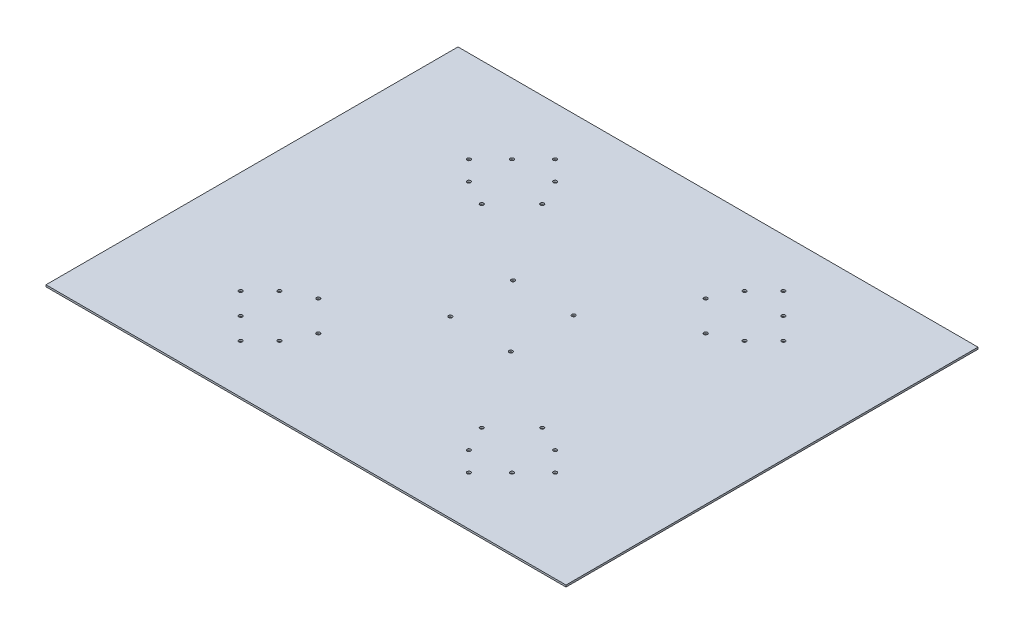
SolidWorks part; units mm, degrees
ref_plane "Front Plane" through (0, 0, 0) normal (0, 0, 1) x (1, 0, 0)
ref_plane "Top Plane" through (0, 0, 0) normal (0, 1, 0) x (1, 0, 0)
ref_plane "Right Plane" through (0, 0, 0) normal (1, 0, 0) x (0, 0, -1)
sketch "Sketch2" plane through (0, 1310.5484, 0) normal (0, 1, 0) x (1, 0, 0)
  line L0 (878.8182, -1232.4154) -> (956.6, -1310.1971) construction
  line L1 (739.7773, -1841.7272) -> (1391.7773, -1841.7272)
  line L2 (739.7773, -1841.7272) -> (739.7773, -1166.7272) construction
  line L3 (793.9654, -1691.1863) -> (878.8182, -1776.0391) construction
  line L4 (739.7773, -1166.7272) -> (1391.7773, -1166.7272)
  line L5 (1391.7773, -1841.7272) -> (1391.7773, -1166.7272) construction
  line L6 (739.7773, -1841.7272) -> (1391.7773, -1166.7272) construction
  line L7 (1337.5891, -1317.2682) -> (1252.7363, -1232.4154) construction
  line L11 (793.9654, -1691.1863) -> (878.8182, -1776.0391) construction
  line L15 (1337.5891, -1317.2682) -> (1252.7363, -1232.4154)
  line L16 (739.7773, -1166.7272) -> (1391.7773, -1841.7272) construction
  line L17 (836.3918, -1733.6127) -> (1295.1627, -1274.8418) construction
  line L18 (956.6, -1310.1971) -> (871.7472, -1395.0499) construction
  line L19 (871.7472, -1395.0499) -> (793.9654, -1317.2682) construction
  line L20 (793.9654, -1317.2682) -> (878.8182, -1232.4154) construction
  line L21 (1337.5891, -1317.2682) -> (1259.8074, -1395.0499) construction
  line L22 (1259.8074, -1395.0499) -> (1174.9546, -1310.1971) construction
  line L23 (1174.9546, -1310.1971) -> (1252.7363, -1232.4154) construction
  line L24 (1252.7363, -1232.4154) -> (1337.5891, -1317.2682) construction
  line L25 (1252.7363, -1776.0391) -> (1174.9546, -1698.2573) construction
  line L26 (1174.9546, -1698.2573) -> (1259.8074, -1613.4045) construction
  line L27 (1259.8074, -1613.4045) -> (1337.5891, -1691.1863) construction
  line L28 (1337.5891, -1691.1863) -> (1252.7363, -1776.0391) construction
  line L29 (871.7472, -1613.4045) -> (956.6, -1698.2573) construction
  line L30 (956.6, -1698.2573) -> (878.8182, -1776.0391) construction
  line L31 (878.8182, -1776.0391) -> (793.9654, -1691.1863) construction
  line L32 (793.9654, -1691.1863) -> (871.7472, -1613.4045) construction
  line L33 (878.8182, -1232.4154) -> (956.6, -1310.1971) construction
  line L34 (956.6, -1310.1971) -> (871.7472, -1395.0499) construction
  line L35 (871.7472, -1395.0499) -> (793.9654, -1317.2682) construction
  line L36 (793.9654, -1317.2682) -> (878.8182, -1232.4154) construction
  line L37 (1337.5891, -1317.2682) -> (1259.8074, -1395.0499) construction
  line L38 (1259.8074, -1395.0499) -> (1174.9546, -1310.1971) construction
  line L39 (1174.9546, -1310.1971) -> (1252.7363, -1232.4154) construction
  line L40 (1252.7363, -1232.4154) -> (1337.5891, -1317.2682) construction
  line L41 (1252.7363, -1776.0391) -> (1174.9546, -1698.2573) construction
  line L42 (1174.9546, -1698.2573) -> (1259.8074, -1613.4045) construction
  line L43 (1259.8074, -1613.4045) -> (1337.5891, -1691.1863) construction
  line L44 (1337.5891, -1691.1863) -> (1252.7363, -1776.0391) construction
  line L45 (871.7472, -1613.4045) -> (956.6, -1698.2573) construction
  line L46 (956.6, -1698.2573) -> (878.8182, -1776.0391) construction
  line L47 (878.8182, -1776.0391) -> (793.9654, -1691.1863) construction
  line L48 (793.9654, -1691.1863) -> (871.7472, -1613.4045) construction
  line L49 (639.7773, -1841.7272) -> (639.7773, -1166.7272)
  line L50 (739.7773, -1841.7272) -> (639.7773, -1841.7272)
  line L51 (739.7773, -1166.7272) -> (639.7773, -1166.7272)
  line L52 (1491.7773, -1841.7272) -> (1491.7773, -1166.7272)
  line L53 (1391.7773, -1841.7272) -> (1491.7773, -1841.7272)
  line L54 (1391.7773, -1166.7272) -> (1491.7773, -1166.7272)
  line L56 (1016.1452, -1555.6101) -> (1115.4094, -1555.6101) construction
  line L57 (1016.1452, -1555.6101) -> (1016.1452, -1452.8443) construction
  line L58 (1016.1452, -1452.8443) -> (1115.4094, -1452.8443) construction
  line L59 (1115.4094, -1555.6101) -> (1115.4094, -1452.8443) construction
  line L60 (1016.1452, -1555.6101) -> (1115.4094, -1452.8443) construction
  line L61 (1016.1452, -1452.8443) -> (1115.4094, -1555.6101) construction
  circle A0 centre (1115.4094, -1555.6101) radius 3
  circle A1 centre (1249.2008, -1638.1533) radius 3
  circle A2 centre (1249.2008, -1638.1533) radius 3
  circle A3 centre (1199.7033, -1687.6507) radius 3
  circle A4 centre (1199.7033, -1687.6507) radius 3
  circle A5 centre (1220.9165, -1730.0771) radius 3
  circle A6 centre (1220.9165, -1730.0771) radius 3
  circle A7 centre (1252.7363, -1761.8969) radius 3
  circle A8 centre (1252.7363, -1761.8969) radius 3
  circle A9 centre (1288.0916, -1726.5416) radius 3
  circle A10 centre (1288.0916, -1726.5416) radius 3
  circle A11 centre (1323.447, -1691.1863) radius 3
  circle A12 centre (1323.447, -1691.1863) radius 3
  circle A13 centre (1291.6272, -1659.3665) radius 3
  circle A14 centre (1291.6272, -1659.3665) radius 3
  circle A15 centre (839.9274, -1659.3665) radius 3
  circle A16 centre (839.9274, -1659.3665) radius 3
  circle A17 centre (808.1076, -1691.1863) radius 3
  circle A18 centre (808.1076, -1691.1863) radius 3
  circle A19 centre (843.4629, -1726.5416) radius 3
  circle A20 centre (843.4629, -1726.5416) radius 3
  circle A21 centre (878.8182, -1761.8969) radius 3
  circle A22 centre (878.8182, -1761.8969) radius 3
  circle A23 centre (910.638, -1730.0771) radius 3
  circle A24 centre (910.638, -1730.0771) radius 3
  circle A25 centre (931.8512, -1687.6507) radius 3
  circle A26 centre (931.8512, -1687.6507) radius 3
  circle A27 centre (882.3538, -1638.1533) radius 3
  circle A28 centre (882.3538, -1638.1533) radius 3
  circle A29 centre (882.3538, -1370.3012) radius 3
  circle A30 centre (882.3538, -1370.3012) radius 3
  circle A31 centre (931.8512, -1320.8037) radius 3
  circle A32 centre (931.8512, -1320.8037) radius 3
  circle A33 centre (910.638, -1278.3773) radius 3
  circle A34 centre (910.638, -1278.3773) radius 3
  circle A35 centre (878.8182, -1246.5575) radius 3
  circle A36 centre (878.8182, -1246.5575) radius 3
  circle A37 centre (843.4629, -1281.9129) radius 3
  circle A38 centre (843.4629, -1281.9129) radius 3
  circle A39 centre (808.1076, -1317.2682) radius 3
  circle A40 centre (808.1076, -1317.2682) radius 3
  circle A41 centre (839.9274, -1349.088) radius 3
  circle A42 centre (839.9274, -1349.088) radius 3
  circle A43 centre (1199.7033, -1320.8037) radius 3
  circle A44 centre (1199.7033, -1320.8037) radius 3
  circle A45 centre (1249.2008, -1370.3012) radius 3
  circle A46 centre (1249.2008, -1370.3012) radius 3
  circle A47 centre (1291.6272, -1349.088) radius 3
  circle A48 centre (1291.6272, -1349.088) radius 3
  circle A49 centre (1323.447, -1317.2682) radius 3
  circle A50 centre (1323.447, -1317.2682) radius 3
  circle A51 centre (1288.0916, -1281.9129) radius 3
  circle A52 centre (1288.0916, -1281.9129) radius 3
  circle A53 centre (1252.7363, -1246.5575) radius 3
  circle A54 centre (1252.7363, -1246.5575) radius 3
  circle A55 centre (1220.9165, -1278.3773) radius 3
  circle A56 centre (1220.9165, -1278.3773) radius 3
  circle A57 centre (1115.4094, -1452.8443) radius 3
  circle A58 centre (1016.1452, -1452.8443) radius 3
  circle A59 centre (1016.1452, -1555.6101) radius 3
  point P3 (1065.7773, -1504.2272)
  point P105 (1065.7773, -1504.2272)
  dimension "D1" = 675
  dimension "D2" = 652
  dimension "D3" = 0
  dimension "D4" = 0
  dimension "D5" = 0
  dimension "D6" = 0
  dimension "D7" = 0
  dimension "D8" = 0
  dimension "D9" = 0
  dimension "D10" = 0
  dimension "D11" = 0
  dimension "D12" = 0
  dimension "D13" = 0
  dimension "D14" = 0
  dimension "D15" = 0
  dimension "D16" = 0
  dimension "D17" = 0
  dimension "D18" = 0
  dimension "D19" = 0
  dimension "D20" = 0
  dimension "D21" = 0
  dimension "D22" = 0
  dimension "D23" = 0
  dimension "D24" = 0
  dimension "D25" = 0
  dimension "D26" = 0
  dimension "D27" = 0
  dimension "D28" = 0
  dimension "D29" = 0
  dimension "D30" = 0
  dimension "D31" = 100
  dimension "D32" = 100
extrude "Boss-Extrude2" add sketch "Sketch2" along normal blind 3 contours L1 L5 L4 L2 L35 L36 L33 L34 L43 L44 L41 L42 L11 L48 L45 L15 L46 | L36 L35 L34 L33 A42 A40 A38 A36 A34 A32 A30 | A20 L17 L45 L48 L11 A28 A18 A16 | A20 L17 L11 L46 L45 A26 A24 A22 | L44 L43 L42 L41 A14 A12 A10 A8 A6 A4 A2 | L17 | L17 L15 region at (1065.7773, 1310.5484, 1504.2272)
sketch "Sketch3" plane through (0, 1310.5484, 0) normal (0, -1, 0) x (1, 0, 0)
  line L0 (913.3836, 1607.1056) -> (907.4131, 1606.4854)
  line L1 (1222.3444, 1606.4834) -> (1215.7646, 1607.0662)
  line L2 (923.3294, 1254.1798) -> (923.3293, 1254.1798)
  line L3 (1187.624, 1254.455) -> (1187.6241, 1254.455)
  line L4 (911.264, 1382.6694) -> (911.264, 1382.6694)
  line L5 (939.7966, 1254.7537) -> (939.7968, 1254.7537)
  line L6 (1208.4937, 1358.2087) -> (1208.4937, 1358.2088)
  line L7 (1214.8998, 1607.2879) -> (1221.3911, 1607.2804)
  line L8 (919.7416, 1217.7617) -> (919.7423, 1217.7617)
  line L9 (907.2235, 1606.8663) -> (913.5239, 1607.5635)
  line L10 (1205.2014, 1383.9141) -> (1205.2021, 1383.9141)
  line L11 (1229.337, 1602.5671) -> (1222.3444, 1606.4834)
  line L12 (733.8279, 1487.5983) -> (650.1419, 1487.5983)
  line L16 (725.4601, 1165.5272) -> (1406.0945, 1165.5272)
  line L17 (725.4601, 1165.5272) -> (634.4526, 1232.4383)
  line L18 (650.1419, 1487.5983) -> (650.1419, 1503.1554)
  line L19 (733.8279, 1462.5557) -> (651.1132, 1462.5557)
  line L20 (650.1419, 1503.1554) -> (733.8279, 1503.1008)
  line L23 (651.1132, 1241.8354) -> (734.5001, 1180.5272)
  line L28 (733.8279, 1462.5557) -> (733.8279, 1477.6608)
  line L32 (733.8279, 1487.5983) -> (733.8279, 1503.1008)
  line L35 (734.5001, 1180.5272) -> (1397.7266, 1180.5272)
  line L36 (1397.7266, 1180.5272) -> (1480.4413, 1241.8354)
  line L37 (1397.7266, 1487.5983) -> (1397.7266, 1503.1008)
  line L38 (1497.1019, 1503.1008) -> (1397.7266, 1503.1008)
  line L39 (1497.1019, 1487.5983) -> (1497.1019, 1503.1008)
  line L40 (1497.1019, 1487.5983) -> (1397.7266, 1487.5983)
  line L41 (1497.1019, 1462.5557) -> (1497.1019, 1477.6608)
  line L42 (1497.1019, 1477.6608) -> (1397.7266, 1477.6608)
  line L43 (1397.7266, 1462.5557) -> (1397.7266, 1477.6608)
  line L44 (1397.7266, 1462.5557) -> (1480.4413, 1462.5557)
  line L45 (1480.4413, 1462.5557) -> (1480.4413, 1241.8354)
  line L46 (1497.1019, 1462.5557) -> (1497.1019, 1232.4383)
  line L47 (733.8279, 1477.6608) -> (651.1132, 1474.0019)
  line L48 (1406.0945, 1165.5272) -> (1497.1019, 1232.4383)
  line L51 (651.1132, 1474.0019) -> (638.2834, 1474.0019)
  line L54 (638.2834, 1474.0019) -> (638.2834, 1229.6218)
  line L55 (651.1132, 1462.5557) -> (651.1132, 1241.8354)
  line L56 (1406.0945, 1165.5272) -> (1497.1019, 1232.4383)
  line L57 (1397.7266, 1462.5557) -> (1397.7266, 1477.6608)
  line L58 (1397.7266, 1487.5983) -> (1397.7266, 1503.1008)
  line L59 (1497.1019, 1503.1008) -> (1397.7266, 1503.1008)
  line L60 (1497.1019, 1487.5983) -> (1397.7266, 1487.5983)
  line L61 (1497.1019, 1477.6608) -> (1397.7266, 1477.6608)
  line L62 (1397.7266, 1462.5557) -> (1480.4413, 1462.5557)
  line L63 (1497.1019, 1487.5983) -> (1497.1019, 1503.1008)
  line L64 (1497.1019, 1462.5557) -> (1497.1019, 1477.6608)
  line L65 (1480.4413, 1462.5557) -> (1480.4413, 1241.8354)
  line L66 (1497.1019, 1462.5557) -> (1497.1019, 1232.4383)
  line L68 (1406.0945, 1165.5272) -> (1497.1019, 1232.4383)
  spline S15 degree 3 poles (1064.8517, 1193.9539) (1064.7409, 1194.1333) (1064.8056, 1194.28) (1064.9955, 1194.28) knots 0 0 0 0 1 1 1 1
  spline S16 degree 3 poles (1065.3409, 1193.9539) (1065.3409, 1193.7746) (1065.2761, 1193.6279) (1065.1971, 1193.6279) knots 0 0 0 0 1 1 1 1
  spline S17 degree 3 poles (753.0042, 1296.8384) (752.849, 1297.9126) (752.4083, 1300.4056) (752.0248, 1302.3784) knots 0 0 0 0 1 1 1 1
  spline S18 degree 3 poles (913.2205, 1830.1795) (925.6339, 1830.6033) (956.23, 1830.4054) (965.5578, 1829.8409) knots 0 0 0 0 1 1 1 1
  spline S19 degree 3 poles (989.8514, 1827.8473) (991.2861, 1827.6666) (993.7807, 1827.3743) (995.3949, 1827.1978) knots 0 0 0 0 1 1 1 1
  spline S20 degree 3 poles (1054.3999, 1262.079) (1054.3224, 1261.9536) (1053.9686, 1259.8747) (1053.6136, 1257.4593) knots 0 0 0 0 1 1 1 1
  spline S21 degree 3 poles (1017.7649, 1206.6738) (1024.2991, 1209.0694) (1025.7313, 1209.7491) (1029.8112, 1212.3909) knots 0 0 0 0 1 1 1 1
  spline S22 degree 3 poles (1030.2919, 1815.6093) (1025.5308, 1818.7394) (1023.8298, 1819.5558) (1017.6916, 1821.6565) knots 0 0 0 0 1 1 1 1
  spline S23 degree 3 poles (759.7483, 1272.9747) (760.2835, 1271.1731) (762.3018, 1266.2665) (764.2334, 1262.0712) knots 0 0 0 0 1 1 1 1
  spline S24 degree 3 poles (811.3179, 1215.5857) (818.6194, 1212.3466) (828.752, 1208.8101) (834.0162, 1207.6635) knots 0 0 0 0 1 1 1 1
  spline S25 degree 3 poles (1036.0021, 1756.9759) (1037.9336, 1751.7545) (1040.917, 1741.4877) (1041.8859, 1736.7284) knots 0 0 0 0 1 1 1 1
  spline S26 degree 3 poles (966.8621, 1220.1862) (974.1535, 1221.1453) (984.4353, 1223.6924) (991.0549, 1226.1792) knots 0 0 0 0 1 1 1 1
  spline S27 degree 3 poles (991.0549, 1226.1792) (1014.5169, 1234.9935) (1027.7483, 1249.1706) (1036.8395, 1275.236) knots 0 0 0 0 1 1 1 1
  spline S28 degree 3 poles (1015.2103, 1756.0594) (1024.0094, 1743.3158) (1030.2061, 1727.2592) (1034.6888, 1705.5869) knots 0 0 0 0 1 1 1 1
  spline S29 degree 3 poles (1001.263, 1256.8878) (984.2052, 1242.406) (957.3354, 1235.109) (925.6119, 1236.3434) knots 0 0 0 0 1 1 1 1
  spline S30 degree 3 poles (1029.1147, 1725.5631) (1025.6599, 1736.6554) (1020.2266, 1748.1038) (1014.685, 1755.9676) knots 0 0 0 0 1 1 1 1
  spline S31 degree 3 poles (828.2616, 1729.7258) (856.1336, 1757.5738) (891.0318, 1773.1823) (927.8947, 1774.2876) knots 0 0 0 0 1 1 1 1
  spline S32 degree 3 poles (939.7968, 1254.7537) (949.8317, 1255.5787) (956.5189, 1256.8929) (965.0275, 1259.7122) knots 0 0 0 0 1 1 1 1
  spline S33 degree 3 poles (784.6183, 1645.5179) (779.3804, 1622.4554) (776.6552, 1596.8533) (775.3926, 1558.8471) knots 0 0 0 0 1 1 1 1
  spline S34 degree 3 poles (1017.4226, 1675.3322) (1021.2031, 1658.6744) (1023.2262, 1642.3014) (1024.4423, 1618.5213) knots 0 0 0 0 1 1 1 1
  spline S35 degree 3 poles (1011.091, 1332.2155) (1014.4722, 1341.6767) (1016.5208, 1349.6196) (1018.8705, 1362.3787) knots 0 0 0 0 1 1 1 1
  spline S36 degree 3 poles (987.1342, 1316.7263) (993.8428, 1325.4344) (999.6849, 1336.6665) (1003.5347, 1348.2584) knots 0 0 0 0 1 1 1 1
  spline S37 degree 3 poles (1014.4866, 1412.5964) (1014.8587, 1418.6614) (1015.4559, 1452.9122) (1015.2155, 1454.3941) knots 0 0 0 0 1 1 1 1
  spline S38 degree 3 poles (820.7012, 1359.2809) (826.2607, 1348.7854) (833.0553, 1339.0009) (840.8548, 1330.259) knots 0 0 0 0 1 1 1 1
  spline S39 degree 3 poles (905.1026, 1721.8465) (924.4129, 1726.5101) (942.0318, 1724.7028) (957.6985, 1716.4512) knots 0 0 0 0 1 1 1 1
  spline S40 degree 3 poles (957.6985, 1716.4512) (965.502, 1712.3412) (974.3669, 1704.7619) (979.8705, 1697.4948) knots 0 0 0 0 1 1 1 1
  spline S41 degree 3 poles (995.2245, 1592.8655) (995.3702, 1587.8756) (995.3948, 1572.9341) (995.2791, 1559.6623) knots 0 0 0 0 1 1 1 1
  spline S42 degree 3 poles (954.3077, 1329.7767) (968.8736, 1339.061) (979.5935, 1354.3844) (986.3542, 1375.5853) knots 0 0 0 0 1 1 1 1
  spline S43 degree 3 poles (971.6525, 1682.5049) (969.0855, 1685.9686) (962.6318, 1692.5939) (959.7417, 1694.7325) knots 0 0 0 0 1 1 1 1
  spline S44 degree 3 poles (896.9161, 1665.0024) (911.8346, 1672.1548) (926.6495, 1671.8995) (939.6337, 1664.2663) knots 0 0 0 0 1 1 1 1
  spline S45 degree 3 poles (968.6272, 1416.9985) (966.9923, 1407.4951) (963.9809, 1396.6378) (961.2696, 1390.4715) knots 0 0 0 0 1 1 1 1
  spline S46 degree 3 poles (962.0279, 1634.6627) (960.6292, 1638.3965) (959.5583, 1640.6192) (957.0762, 1644.9402) knots 0 0 0 0 1 1 1 1
  spline S47 degree 3 poles (868.9835, 1602.869) (874.4942, 1616.8055) (879.3151, 1624.6559) (887.1527, 1632.4559) knots 0 0 0 0 1 1 1 1
  spline S48 degree 3 poles (948.1674, 1408.6188) (945.3191, 1401.6679) (943.453, 1398.5896) (938.8168, 1393.1941) knots 0 0 0 0 1 1 1 1
  spline S49 degree 3 poles (869.2193, 1426.206) (876.4935, 1406.9438) (886.0189, 1394.6661) (899.5242, 1387.1444) knots 0 0 0 0 1 1 1 1
  spline S50 degree 3 poles (935.248, 1558.0318) (935.4919, 1553.0031) (935.565, 1536.9398) (935.47, 1509.2816) knots 0 0 0 0 1 1 1 1
  spline S51 degree 3 poles (913.2205, 1420.7454) (912.1445, 1420.6386) (910.9705, 1420.4998) (910.6118, 1420.437) knots 0 0 0 0 1 1 1 1
  spline S52 degree 3 poles (925.2909, 1599.2721) (923.0861, 1602.0308) (919.1219, 1605.7575) (917.8247, 1606.2912) knots 0 0 0 0 1 1 1 1
  spline S53 degree 3 poles (1288.2224, 1822.922) (1301.281, 1820.4073) (1317.5401, 1814.6876) (1326.6099, 1809.4176) knots 0 0 0 0 1 1 1 1
  spline S54 degree 3 poles (1361.0718, 1251.8347) (1360.2309, 1250.5792) (1358.9478, 1248.5591) (1358.2205, 1247.3456) knots 0 0 0 0 1 1 1 1
  spline S55 degree 3 poles (1335.0161, 1224.0428) (1322.757, 1215.455) (1304.323, 1208.3533) (1284.7985, 1204.6966) knots 0 0 0 0 1 1 1 1
  spline S56 degree 3 poles (1367.6937, 1762.2053) (1366.9883, 1763.617) (1366.2241, 1765.3479) (1365.9957, 1766.0518) knots 0 0 0 0 1 1 1 1
  spline S57 degree 3 poles (1072.5332, 1731.0218) (1069.6739, 1688.371) (1069.2, 1632.5473) (1069.9202, 1423.1942) knots 0 0 0 0 1 1 1 1
  spline S58 degree 3 poles (1178.6566, 1198.4195) (1184.5191, 1198.1107) (1207.2203, 1198.2555) (1219.4177, 1198.6794) knots 0 0 0 0 1 1 1 1
  spline S59 degree 3 poles (1086.0733, 1726.9457) (1086.3523, 1729.0369) (1089.912, 1744.416) (1090.5643, 1746.348) knots 0 0 0 0 1 1 1 1
  spline S60 degree 3 poles (1361.808, 1701.0229) (1362.3563, 1698.9597) (1363.3056, 1695.4376) (1363.9176, 1693.196) knots 0 0 0 0 1 1 1 1
  spline S61 degree 3 poles (1370.8516, 1654.391) (1374.7561, 1621.9163) (1376.3855, 1573.4959) (1376.0131, 1501.0057) knots 0 0 0 0 1 1 1 1
  spline S62 degree 3 poles (1080.8485, 1679.3368) (1078.7599, 1650.1705) (1078.3822, 1624.3107) (1078.3907, 1511.0751) knots 0 0 0 0 1 1 1 1
  spline S63 degree 3 poles (1212.5699, 1791.4757) (1234.0897, 1789.3442) (1252.2884, 1784.2561) (1270.1245, 1775.3844) knots 0 0 0 0 1 1 1 1
  spline S64 degree 3 poles (1363.6928, 1601.5647) (1363.884, 1598.6054) (1364.1156, 1595.0837) (1364.2075, 1593.7385) knots 0 0 0 0 1 1 1 1
  spline S65 degree 3 poles (1270.116, 1252.9563) (1257.9165, 1246.8864) (1245.5399, 1242.6223) (1231.483, 1239.646) knots 0 0 0 0 1 1 1 1
  spline S66 degree 3 poles (1087.5156, 1615.0974) (1087.1158, 1595.7707) (1087.1156, 1425.9682) (1087.5153, 1410.1507) knots 0 0 0 0 1 1 1 1
  spline S67 degree 3 poles (1134.8949, 1252.9401) (1147.1903, 1244.6706) (1161.7107, 1239.7537) (1180.4501, 1237.5143) knots 0 0 0 0 1 1 1 1
  spline S68 degree 3 poles (1321.3933, 1322.5959) (1310.4482, 1305.7826) (1293.5094, 1288.9806) (1276.0662, 1277.6351) knots 0 0 0 0 1 1 1 1
  spline S69 degree 3 poles (1120.7229, 1732.9784) (1116.0356, 1725.2465) (1112.779, 1717.8329) (1109.2278, 1706.8104) knots 0 0 0 0 1 1 1 1
  spline S70 degree 3 poles (1321.0729, 1352.7255) (1327.4351, 1366.1542) (1330.0756, 1373.425) (1333.8157, 1387.8136) knots 0 0 0 0 1 1 1 1
  spline S71 degree 3 poles (1333.7264, 1640.8794) (1330.3395, 1653.9998) (1328.0461, 1660.4687) (1322.5881, 1672.2965) knots 0 0 0 0 1 1 1 1
  spline S72 degree 3 poles (1334.5781, 1504.5533) (1334.3274, 1473.5393) (1333.6974, 1459.8908) (1331.5752, 1439.4986) knots 0 0 0 0 1 1 1 1
  spline S73 degree 3 poles (1290.6995, 1331.2372) (1280.6481, 1319.799) (1269.0134, 1310.1248) (1256.7577, 1303.0149) knots 0 0 0 0 1 1 1 1
  spline S74 degree 3 poles (1333.6987, 1477.651) (1334.7426, 1509.103) (1334.2291, 1552.6755) (1332.5669, 1573.6841) knots 0 0 0 0 1 1 1 1
  spline S75 degree 3 poles (1289.3977, 1697.8983) (1275.0748, 1713.807) (1257.2862, 1726.3507) (1239.3091, 1733.2185) knots 0 0 0 0 1 1 1 1
  spline S76 degree 3 poles (1145.6899, 1338.2481) (1151.987, 1327.9253) (1160.9088, 1319.0197) (1170.5886, 1313.3947) knots 0 0 0 0 1 1 1 1
  spline S77 degree 3 poles (1197.113, 1321.4884) (1178.0355, 1324.6978) (1163.0067, 1335.6944) (1152.4321, 1354.1818) knots 0 0 0 0 1 1 1 1
  spline S78 degree 3 poles (1280.9309, 1363.683) (1270.3978, 1348.7024) (1255.5494, 1335.9009) (1240.2398, 1328.6012) knots 0 0 0 0 1 1 1 1
  spline S79 degree 3 poles (1146.4606, 1576.6189) (1146.2966, 1542.3244) (1146.5983, 1440.5993) (1146.8827, 1434.2812) knots 0 0 0 0 1 1 1 1
  spline S80 degree 3 poles (1196.867, 1340.3733) (1203.1694, 1338.8932) (1207.9694, 1338.5308) (1214.0373, 1339.0771) knots 0 0 0 0 1 1 1 1
  spline S81 degree 3 poles (1264.0624, 1636.2931) (1276.7182, 1616.6176) (1283.5042, 1591.8406) (1286.1056, 1555.8088) knots 0 0 0 0 1 1 1 1
  spline S82 degree 3 poles (1205.354, 1669.2366) (1194.467, 1667.613) (1184.8833, 1661.5651) (1177.2527, 1651.5029) knots 0 0 0 0 1 1 1 1
  spline S83 degree 3 poles (1256.6813, 1612.8147) (1259.9121, 1606.3577) (1262.2983, 1599.9197) (1264.4296, 1591.9095) knots 0 0 0 0 1 1 1 1
  spline S84 degree 3 poles (1248.8329, 1403.5693) (1256.0296, 1413.2386) (1261.1972, 1424.8424) (1264.7066, 1439.2144) knots 0 0 0 0 1 1 1 1
  spline S85 degree 3 poles (1205.3937, 1384.3357) (1209.7692, 1382.8783) (1210.1248, 1382.8132) (1213.8542, 1382.7868) knots 0 0 0 0 1 1 1 1
  spline S86 degree 3 poles (1230.6708, 1427.0632) (1235.9112, 1432.0398) (1237.4102, 1434.496) (1242.1403, 1445.8574) knots 0 0 0 0 1 1 1 1
  spline S94 degree 3 poles (1065.0148, 1294.3892) (1065.1941, 1294.3892) (1065.3409, 1294.2425) (1065.3409, 1294.0632) knots 0 0 0 0 1 1 1 1
  spline S95 degree 3 poles (1065.2322, 1314.1719) (1065.3517, 1314.0524) (1065.254, 1313.9545) (1065.0148, 1313.9545) knots 0 0 0 0 1 1 1 1
  spline S98 degree 3 poles (1064.7974, 1344.1721) (1064.9169, 1344.2917) (1065.1126, 1344.2917) (1065.2322, 1344.1721) knots 0 0 0 0 1 1 1 1
  spline S99 degree 3 poles (1065.0148, 1363.8461) (1064.8354, 1363.8461) (1064.6887, 1363.9928) (1064.6887, 1364.1722) knots 0 0 0 0 1 1 1 1
  spline S100 degree 3 poles (1065.0148, 1383.7375) (1064.8354, 1383.7375) (1064.6887, 1383.8842) (1064.6887, 1384.0636) knots 0 0 0 0 1 1 1 1
  spline S101 degree 3 poles (1065.0148, 1414.3898) (1065.1941, 1414.3898) (1065.3409, 1414.2431) (1065.3409, 1414.0637) knots 0 0 0 0 1 1 1 1
  spline S102 degree 3 poles (1065.3409, 1414.0637) (1065.3409, 1413.8844) (1065.1941, 1413.7377) (1065.0148, 1413.7377) knots 0 0 0 0 1 1 1 1
  spline S106 degree 3 poles (1065.0148, 1473.7379) (1064.8354, 1473.7379) (1064.6887, 1473.8847) (1064.6887, 1474.064) knots 0 0 0 0 1 1 1 1
  spline S107 degree 3 poles (1065.3409, 1504.0642) (1065.3409, 1503.8848) (1065.1941, 1503.7381) (1065.0148, 1503.7381) knots 0 0 0 0 1 1 1 1
  spline S109 degree 3 poles (1065.0148, 1523.9556) (1064.8354, 1523.9556) (1064.6887, 1524.1023) (1064.6887, 1524.2817) knots 0 0 0 0 1 1 1 1
  spline S110 degree 3 poles (1065.0148, 1554.6079) (1065.1941, 1554.6079) (1065.3409, 1554.4612) (1065.3409, 1554.2818) knots 0 0 0 0 1 1 1 1
  spline S115 degree 3 poles (1065.0148, 1613.956) (1064.8354, 1613.956) (1064.6887, 1614.1028) (1064.6887, 1614.2821) knots 0 0 0 0 1 1 1 1
  spline S122 degree 3 poles (1065.2322, 1744.2828) (1065.3517, 1744.1632) (1065.254, 1744.0654) (1065.0148, 1744.0654) knots 0 0 0 0 1 1 1 1
  spline S123 degree 3 poles (1064.6887, 1754.1741) (1064.6887, 1754.3535) (1064.8354, 1754.5002) (1065.0148, 1754.5002) knots 0 0 0 0 1 1 1 1
  spline S126 degree 3 poles (1064.8517, 1804.3918) (1064.9626, 1804.5711) (1065.118, 1804.7179) (1065.1971, 1804.7179) knots 0 0 0 0 1 1 1 1
  spline S127 degree 3 poles (1064.6887, 1814.1744) (1064.6887, 1814.3538) (1064.8354, 1814.5005) (1065.0148, 1814.5005) knots 0 0 0 0 1 1 1 1
  spline S159 degree 3 poles (1064.9955, 1194.28) (1065.1855, 1194.28) (1065.3409, 1194.1333) (1065.3409, 1193.9539) knots 0 0 0 0 1 1 1 1
  spline S161 degree 3 poles (758.174, 1751.8915) (758.5077, 1752.6986) (759.098, 1754.5328) (759.4859, 1755.9676) knots 0 0 0 0 1 1 1 1
  spline S162 degree 3 poles (1030.7587, 1815.8682) (1033.8956, 1813.836) (1035.3485, 1812.6235) (1037.7849, 1810.0045) knots 0 0 0 0 1 1 1 1
  spline S163 degree 3 poles (1029.8112, 1212.3909) (1034.6048, 1215.4949) (1039.3039, 1220.0553) (1041.3158, 1223.556) knots 0 0 0 0 1 1 1 1
  spline S164 degree 3 poles (1059.8325, 1355.8569) (1060.275, 1373.9332) (1060.5077, 1612.2612) (1060.1185, 1648.8475) knots 0 0 0 0 1 1 1 1
  spline S165 degree 3 poles (904.4162, 1199.0229) (911.4108, 1198.7466) (918.2342, 1198.4644) (919.5793, 1198.3956) knots 0 0 0 0 1 1 1 1
  spline S166 degree 3 poles (775.1963, 1307.7589) (771.84, 1315.0405) (766.9012, 1331.0631) (764.0394, 1343.9547) knots 0 0 0 0 1 1 1 1
  spline S167 degree 3 poles (1043.0306, 1731.5913) (1043.8733, 1728.3028) (1046.4078, 1711.9099) (1047.4039, 1703.3043) knots 0 0 0 0 1 1 1 1
  spline S168 degree 3 poles (1045.7699, 1712.5978) (1044.436, 1721.5001) (1043.1275, 1729.2861) (1042.6661, 1731.0666) knots 0 0 0 0 1 1 1 1
  spline S169 degree 3 poles (755.3863, 1593.4125) (754.0104, 1558.8532) (754.4146, 1451.5229) (756.042, 1419.2811) knots 0 0 0 0 1 1 1 1
  spline S170 degree 3 poles (776.5567, 1305.8601) (777.1577, 1304.6625) (777.9944, 1302.8757) (778.4161, 1301.8893) knots 0 0 0 0 1 1 1 1
  spline S171 degree 3 poles (881.4506, 1783.6591) (861.701, 1777.3541) (843.1425, 1766.8555) (826.8683, 1752.7817) knots 0 0 0 0 1 1 1 1
  spline S172 degree 3 poles (870.1769, 1248.7376) (881.6228, 1244.0864) (895.5955, 1240.2299) (906.6988, 1238.6575) knots 0 0 0 0 1 1 1 1
  spline S173 degree 3 poles (1034.1192, 1514.1729) (1034.1316, 1402.7496) (1034.1631, 1404.6769) (1031.8905, 1377.7049) knots 0 0 0 0 1 1 1 1
  spline S174 degree 3 poles (1033.7793, 1594.0646) (1033.5842, 1626.9085) (1031.8093, 1653.6996) (1028.4541, 1674.4455) knots 0 0 0 0 1 1 1 1
  spline S175 degree 3 poles (796.6422, 1345.5851) (805.0363, 1327.1975) (815.2984, 1312.1913) (828.4196, 1299.1175) knots 0 0 0 0 1 1 1 1
  spline S176 degree 3 poles (926.9163, 1756.6895) (913.1192, 1756.393) (902.0795, 1754.2688) (888.9275, 1749.38) knots 0 0 0 0 1 1 1 1
  spline S177 degree 3 poles (788.3369, 1594.8799) (786.2937, 1574.5334) (785.2377, 1547.2649) (785.2431, 1514.9882) knots 0 0 0 0 1 1 1 1
  spline S178 degree 3 poles (919.5793, 1287.8633) (906.6139, 1289.0155) (892.4958, 1293.0881) (880.2856, 1299.1981) knots 0 0 0 0 1 1 1 1
  spline S179 degree 3 poles (1010.3909, 1655.2062) (1012.4256, 1644.2757) (1013.2242, 1637.8683) (1014.2977, 1623.8599) knots 0 0 0 0 1 1 1 1
  spline S180 degree 3 poles (987.1041, 1711.6196) (975.1141, 1727.0481) (958.7696, 1736.553) (939.1446, 1739.5097) knots 0 0 0 0 1 1 1 1
  spline S181 degree 3 poles (988.8756, 1683.0818) (996.626, 1667.6498) (1001.7519, 1647.3789) (1004.17, 1622.5974) knots 0 0 0 0 1 1 1 1
  spline S182 degree 3 poles (931.3185, 1304.6586) (939.3587, 1305.1454) (949.9486, 1308.2646) (957.6447, 1312.4129) knots 0 0 0 0 1 1 1 1
  spline S183 degree 3 poles (914.3619, 1305.0945) (916.7521, 1304.7517) (926.4351, 1304.2156) (927.4054, 1304.3724) knots 0 0 0 0 1 1 1 1
  spline S184 degree 3 poles (986.3542, 1375.5853) (990.1119, 1387.3688) (992.9885, 1404.847) (994.2973, 1423.8464) knots 0 0 0 0 1 1 1 1
  spline S185 degree 3 poles (983.883, 1510.749) (983.8286, 1491.738) (983.8814, 1469.2868) (984.0005, 1460.8574) knots 0 0 0 0 1 1 1 1
  spline S186 degree 3 poles (843.2038, 1544.9883) (844.6897, 1570.592) (847.2503, 1588.746) (851.4018, 1603.1103) knots 0 0 0 0 1 1 1 1
  spline S187 degree 3 poles (939.3076, 1663.9246) (924.3191, 1672.8119) (905.9948, 1671.3733) (888.9847, 1659.974) knots 0 0 0 0 1 1 1 1
  spline S188 degree 3 poles (911.264, 1382.6694) (910.5466, 1382.739) (908.052, 1383.3862) (905.7205, 1384.1076) knots 0 0 0 0 1 1 1 1
  spline S189 degree 3 poles (923.182, 1383.939) (927.467, 1385.0678) (927.8349, 1385.2335) (931.6894, 1387.7706) knots 0 0 0 0 1 1 1 1
  spline S190 degree 3 poles (924.0388, 1644.2143) (920.1685, 1645.3914) (919.9476, 1645.4204) (915.2766, 1645.3653) knots 0 0 0 0 1 1 1 1
  spline S191 degree 3 poles (902.3033, 1423.6687) (900.3518, 1424.6971) (893.3971, 1432.539) (892.0443, 1435.2364) knots 0 0 0 0 1 1 1 1
  spline S192 degree 3 poles (907.4131, 1606.4854) (901.9725, 1604.3141) (900.8464, 1603.4196) (895.4713, 1596.9994) knots 0 0 0 0 1 1 1 1
  spline S193 degree 3 poles (1076.4252, 1257.3382) (1076.2316, 1258.9304) (1075.8725, 1261.1315) (1075.6274, 1262.2296) knots 0 0 0 0 1 1 1 1
  spline S194 degree 3 poles (1085.7721, 1801.0968) (1086.4439, 1802.1019) (1087.4758, 1803.7197) (1088.0653, 1804.6918) knots 0 0 0 0 1 1 1 1
  spline S195 degree 3 poles (1326.6099, 1809.4176) (1335.6191, 1804.183) (1341.7917, 1799.5694) (1348.3334, 1793.181) knots 0 0 0 0 1 1 1 1
  spline S196 degree 3 poles (1378.8958, 1720.8509) (1379.1645, 1718.6807) (1379.4535, 1716.7932) (1379.5381, 1716.6564) knots 0 0 0 0 1 1 1 1
  spline S197 degree 3 poles (1377.0697, 1296.9979) (1376.7198, 1294.9354) (1376.0658, 1291.9283) (1375.6163, 1290.3154) knots 0 0 0 0 1 1 1 1
  spline S198 degree 3 poles (1385.2829, 1420.9116) (1385.7506, 1446.0834) (1385.7236, 1584.2132) (1385.246, 1610.206) knots 0 0 0 0 1 1 1 1
  spline S199 degree 3 poles (1377.4118, 1726.9457) (1377.086, 1728.3805) (1376.7205, 1730.3615) (1376.5995, 1731.3479) knots 0 0 0 0 1 1 1 1
  spline S200 degree 3 poles (1078.8567, 1247.7586) (1079.1973, 1245.4701) (1080.9161, 1239.898) (1082.8802, 1234.715) knots 0 0 0 0 1 1 1 1
  spline S201 degree 3 poles (1113.475, 1787.6129) (1128.7179, 1801.5544) (1151.001, 1808.895) (1183.2961, 1810.6136) knots 0 0 0 0 1 1 1 1
  spline S202 degree 3 poles (1371.5215, 1384.3897) (1373.3202, 1402.8059) (1374.0151, 1416.3385) (1374.8201, 1448.6291) knots 0 0 0 0 1 1 1 1
  spline S203 degree 3 poles (1375.3437, 1527.3795) (1375.1993, 1575.2867) (1375.0596, 1584.384) (1374.1464, 1605.3147) knots 0 0 0 0 1 1 1 1
  spline S204 degree 3 poles (1101.2165, 1257.2151) (1101.8715, 1256.2287) (1102.9618, 1254.4678) (1103.6392, 1253.3021) knots 0 0 0 0 1 1 1 1
  spline S205 degree 3 poles (1270.1245, 1775.3844) (1276.2132, 1772.3558) (1278.1818, 1771.2399) (1285.72, 1766.5437) knots 0 0 0 0 1 1 1 1
  spline S206 degree 3 poles (1359.3138, 1642.8149) (1359.4307, 1641.9181) (1359.7295, 1639.9371) (1359.9779, 1638.4127) knots 0 0 0 0 1 1 1 1
  spline S207 degree 3 poles (1288.0594, 1764.4977) (1268.4689, 1777.5908) (1245.3315, 1786.5437) (1222.5156, 1789.8594) knots 0 0 0 0 1 1 1 1
  spline S208 degree 3 poles (1137.1358, 1753.5264) (1146.7713, 1761.8246) (1157.6406, 1767.4071) (1171.0133, 1770.9259) knots 0 0 0 0 1 1 1 1
  spline S209 degree 3 poles (1222.3525, 1772.2316) (1259.3484, 1765.6009) (1292.7609, 1744.3195) (1317.11, 1711.8779) knots 0 0 0 0 1 1 1 1
  spline S210 degree 3 poles (1249.088, 1764.1144) (1232.0935, 1770.7909) (1216.2189, 1773.8681) (1199.0372, 1773.8166) knots 0 0 0 0 1 1 1 1
  spline S211 degree 3 poles (1105.029, 1513.6838) (1105.0105, 1596.9962) (1105.0683, 1608.4706) (1105.5563, 1618.1952) knots 0 0 0 0 1 1 1 1
  spline S212 degree 3 poles (1342.9939, 1443.2493) (1341.2025, 1421.0188) (1338.6946, 1405.0107) (1334.3601, 1388.1397) knots 0 0 0 0 1 1 1 1
  spline S213 degree 3 poles (1206.3742, 1271.7168) (1221.7163, 1272.4187) (1236.7781, 1276.3649) (1252.8418, 1283.8913) knots 0 0 0 0 1 1 1 1
  spline S214 degree 3 poles (1195.4502, 1287.8906) (1180.0309, 1289.1743) (1165.5294, 1294.9676) (1154.235, 1304.3558) knots 0 0 0 0 1 1 1 1
  spline S215 degree 3 poles (1137.689, 1323.4111) (1133.8236, 1329.5302) (1132.6015, 1331.8597) (1129.8194, 1338.4112) knots 0 0 0 0 1 1 1 1
  spline S216 degree 3 poles (1239.3091, 1733.2185) (1231.1807, 1736.3238) (1223.1544, 1738.3825) (1214.6894, 1739.5332) knots 0 0 0 0 1 1 1 1
  spline S217 degree 3 poles (1230.8308, 1720.2078) (1254.6434, 1712.7994) (1277.3792, 1694.9288) (1292.9109, 1671.4121) knots 0 0 0 0 1 1 1 1
  spline S218 degree 3 poles (1231.9721, 1719.325) (1206.7186, 1727.9248) (1181.0356, 1724.2543) (1162.5618, 1709.4053) knots 0 0 0 0 1 1 1 1
  spline S219 degree 3 poles (1152.4321, 1354.1818) (1144.1975, 1368.578) (1139.3935, 1385.1804) (1136.7769, 1408.285) knots 0 0 0 0 1 1 1 1
  spline S220 degree 3 poles (1269.66, 1678.1955) (1292.2403, 1654.9295) (1305.2978, 1622.2264) (1309.8914, 1577.4341) knots 0 0 0 0 1 1 1 1
  spline S221 degree 3 poles (1300.0136, 1401.9985) (1295.4191, 1387.9623) (1289.1463, 1375.3672) (1280.9309, 1363.683) knots 0 0 0 0 1 1 1 1
  spline S222 degree 3 poles (1249.4179, 1675.8002) (1262.5389, 1666.3148) (1274.2552, 1651.7677) (1282.0376, 1635.2996) knots 0 0 0 0 1 1 1 1
  spline S223 degree 3 poles (1259.3896, 1361.6139) (1273.111, 1374.9604) (1284.1565, 1394.5446) (1290.3505, 1416.5094) knots 0 0 0 0 1 1 1 1
  spline S224 degree 3 poles (1159.5072, 1590.9668) (1159.1866, 1586.944) (1159.0948, 1569.3606) (1159.1063, 1514.1729) knots 0 0 0 0 1 1 1 1
  spline S225 degree 3 poles (1204.2546, 1359.2553) (1209.5335, 1358.3121) (1216.7286, 1358.5737) (1222.3525, 1359.9132) knots 0 0 0 0 1 1 1 1
  spline S226 degree 3 poles (1264.7066, 1439.2144) (1269.5804, 1459.1733) (1271.0229, 1474.2242) (1271.3285, 1508.3033) knots 0 0 0 0 1 1 1 1
  spline S227 degree 3 poles (1186.0821, 1627.2139) (1181.1089, 1619.1517) (1176.9582, 1605.2122) (1175.4347, 1591.4559) knots 0 0 0 0 1 1 1 1
  spline S228 degree 3 poles (1242.3458, 1445.2052) (1240.1102, 1439.7304) (1237.748, 1434.8408) (1236.0755, 1432.2263) knots 0 0 0 0 1 1 1 1
  spline S229 degree 3 poles (1226.3932, 1422.6868) (1225.3517, 1422.1482) (1218.7167, 1420.2506) (1217.9753, 1420.2793) knots 0 0 0 0 1 1 1 1
  spline S230 degree 3 poles (1065.0148, 1203.7366) (1064.8354, 1203.7366) (1064.6887, 1203.8833) (1064.6887, 1204.0627) knots 0 0 0 0 1 1 1 1
  spline S234 degree 3 poles (1065.0148, 1274.4978) (1065.1941, 1274.4978) (1065.3409, 1274.3511) (1065.3409, 1274.1717) knots 0 0 0 0 1 1 1 1
  spline S256 degree 3 poles (1065.0148, 1604.4995) (1065.1941, 1604.4995) (1065.3409, 1604.3527) (1065.3409, 1604.1734) knots 0 0 0 0 1 1 1 1
  spline S258 degree 3 poles (1065.0148, 1633.8474) (1064.8354, 1633.8474) (1064.6887, 1633.9942) (1064.6887, 1634.1735) knots 0 0 0 0 1 1 1 1
  spline S265 degree 3 poles (1065.0148, 1733.9566) (1064.8354, 1733.9566) (1064.6887, 1734.1034) (1064.6887, 1734.2827) knots 0 0 0 0 1 1 1 1
  spline S267 degree 3 poles (1065.0148, 1753.848) (1064.8354, 1753.848) (1064.6887, 1753.9948) (1064.6887, 1754.1741) knots 0 0 0 0 1 1 1 1
  spline S268 degree 3 poles (1065.0148, 1774.0655) (1064.7756, 1774.0655) (1064.6778, 1774.1634) (1064.7974, 1774.2829) knots 0 0 0 0 1 1 1 1
  spline S272 degree 3 poles (1065.0148, 1824.6093) (1065.1941, 1824.6093) (1065.3409, 1824.4625) (1065.3409, 1824.2832) knots 0 0 0 0 1 1 1 1
  spline S304 degree 3 poles (765.2133, 1258.7908) (761.2615, 1267.2499) (760.2056, 1269.7478) (759.4701, 1272.3782) knots 0 0 0 0 1 1 1 1
  spline S305 degree 3 poles (802.5135, 1808.8395) (811.348, 1813.7376) (823.0991, 1818.3663) (833.0789, 1820.8791) knots 0 0 0 0 1 1 1 1
  spline S306 degree 3 poles (1050.2209, 1242.1858) (1049.7735, 1241.0039) (1049.1756, 1239.1421) (1048.8922, 1238.0486) knots 0 0 0 0 1 1 1 1
  spline S307 degree 3 poles (990.6666, 1200.959) (992.3704, 1201.2168) (994.7182, 1201.5191) (995.884, 1201.6309) knots 0 0 0 0 1 1 1 1
  spline S308 degree 3 poles (1043.3695, 1801.5244) (1042.5854, 1802.6531) (1041.6158, 1804.2263) (1041.2148, 1805.0204) knots 0 0 0 0 1 1 1 1
  spline S309 degree 3 poles (759.0143, 1753.1959) (757.2438, 1747.6022) (753.7418, 1733.9025) (753.4293, 1731.3479) knots 0 0 0 0 1 1 1 1
  spline S310 degree 3 poles (752.6178, 1301.4001) (752.9435, 1299.9654) (753.3086, 1297.9843) (753.4292, 1296.9979) knots 0 0 0 0 1 1 1 1
  spline S311 degree 3 poles (757.0428, 1631.8909) (759.5864, 1667.3805) (765.2178, 1695.9233) (773.931, 1717.4892) knots 0 0 0 0 1 1 1 1
  spline S312 degree 3 poles (756.042, 1419.2811) (757.2887, 1394.5838) (759.6351, 1370.6031) (762.2957, 1355.3678) knots 0 0 0 0 1 1 1 1
  spline S313 degree 3 poles (871.3182, 1247.8375) (851.2423, 1255.898) (833.4046, 1267.7446) (817.6775, 1283.4621) knots 0 0 0 0 1 1 1 1
  spline S314 degree 3 poles (950.5577, 1791.1666) (972.0476, 1788.5816) (989.756, 1781.5271) (1002.2823, 1770.5608) knots 0 0 0 0 1 1 1 1
  spline S315 degree 3 poles (981.1442, 1245.2658) (984.3795, 1246.5673) (990.9745, 1250.1091) (994.4763, 1252.4257) knots 0 0 0 0 1 1 1 1
  spline S316 degree 3 poles (1041.6805, 1640.3827) (1040.0169, 1676.106) (1035.9661, 1703.5652) (1029.1147, 1725.5631) knots 0 0 0 0 1 1 1 1
  spline S317 degree 3 poles (792.7259, 1353.9004) (789.4852, 1362.7517) (788.9102, 1364.5421) (786.652, 1372.8135) knots 0 0 0 0 1 1 1 1
  spline S318 degree 3 poles (1032.4035, 1643.9376) (1034.0928, 1622.5478) (1034.1071, 1621.4613) (1034.1192, 1514.1729) knots 0 0 0 0 1 1 1 1
  spline S319 degree 3 poles (921.8619, 1271.2419) (909.3933, 1272.3817) (899.3205, 1274.6194) (888.1746, 1278.7255) knots 0 0 0 0 1 1 1 1
  spline S320 degree 3 poles (795.5572, 1388.6301) (791.0588, 1406.2293) (788.8892, 1420.1539) (787.0472, 1443.2487) knots 0 0 0 0 1 1 1 1
  spline S321 degree 3 poles (941.1011, 1271.7378) (936.1763, 1271.1534) (925.765, 1270.8851) (921.8619, 1271.2419) knots 0 0 0 0 1 1 1 1
  spline S322 degree 3 poles (888.9275, 1749.38) (872.698, 1743.3473) (858.869, 1734.9511) (844.3563, 1722.319) knots 0 0 0 0 1 1 1 1
  spline S323 degree 3 poles (822.4749, 1672.1738) (813.989, 1657.0114) (807.9504, 1640.4929) (803.8151, 1621.13) knots 0 0 0 0 1 1 1 1
  spline S324 degree 3 poles (840.8548, 1330.259) (867.9024, 1299.9431) (905.6471, 1284.0855) (939.3076, 1288.8961) knots 0 0 0 0 1 1 1 1
  spline S325 degree 3 poles (863.6043, 1700.7502) (876.2771, 1710.9028) (891.1991, 1718.4887) (905.1026, 1721.8465) knots 0 0 0 0 1 1 1 1
  spline S326 degree 3 poles (984.8728, 1338.2481) (973.7069, 1320.3997) (958.6441, 1309.3921) (940.1033, 1305.5315) knots 0 0 0 0 1 1 1 1
  spline S327 degree 3 poles (820.1462, 1577.2711) (824.24, 1618.2276) (835.2976, 1648.4551) (854.8587, 1672.1629) knots 0 0 0 0 1 1 1 1
  spline S328 degree 3 poles (940.9646, 1704.4317) (910.6027, 1714.0397) (873.3288, 1697.7923) (849.7288, 1664.6628) knots 0 0 0 0 1 1 1 1
  spline S329 degree 3 poles (818.4399, 1547.597) (817.8914, 1536.3556) (817.8835, 1493.5081) (818.4277, 1481.401) knots 0 0 0 0 1 1 1 1
  spline S330 degree 3 poles (974.3737, 1645.5644) (971.4231, 1653.7792) (967.6066, 1661.154) (963.0559, 1667.4346) knots 0 0 0 0 1 1 1 1
  spline S331 degree 3 poles (957.581, 1645.0975) (961.4876, 1638.2167) (964.4086, 1630.4444) (966.6544, 1620.9549) knots 0 0 0 0 1 1 1 1
  spline S332 degree 3 poles (844.7583, 1467.7053) (846.2515, 1450.9737) (848.6246, 1436.5712) (851.5964, 1426.2041) knots 0 0 0 0 1 1 1 1
  spline S333 degree 3 poles (851.5964, 1426.2041) (857.8, 1404.5632) (866.1235, 1389.4876) (878.8378, 1376.8648) knots 0 0 0 0 1 1 1 1
  spline S334 degree 3 poles (945.635, 1625.4336) (948.0085, 1620.7263) (951.4691, 1611.2338) (952.5535, 1606.456) knots 0 0 0 0 1 1 1 1
  spline S335 degree 3 poles (888.2054, 1632.9003) (883.6004, 1628.4895) (879.2238, 1622.7491) (875.6269, 1616.4017) knots 0 0 0 0 1 1 1 1
  spline S336 degree 3 poles (892.0443, 1435.2364) (889.8503, 1439.6113) (886.215, 1448.9654) (884.7484, 1454.0096) knots 0 0 0 0 1 1 1 1
  spline S337 degree 3 poles (1170.9936, 1198.2133) (1143.001, 1199.3015) (1124.7321, 1201.8683) (1111.3193, 1206.5975) knots 0 0 0 0 1 1 1 1
  spline S338 degree 3 poles (1167.2435, 1829.855) (1180.2875, 1830.4648) (1184.7738, 1830.5323) (1201.6459, 1830.3721) knots 0 0 0 0 1 1 1 1
  spline S339 degree 3 poles (1348.3334, 1793.181) (1351.4799, 1790.1082) (1356.2512, 1784.2743) (1357.9618, 1781.4082) knots 0 0 0 0 1 1 1 1
  spline S340 degree 3 poles (1360.4564, 1777.4895) (1362.3039, 1774.7117) (1366.0877, 1767.5427) (1366.6523, 1765.7503) knots 0 0 0 0 1 1 1 1
  spline S341 degree 3 poles (1367.6585, 1266.1498) (1368.5737, 1268.1407) (1369.8999, 1271.6038) (1370.6055, 1273.8457) knots 0 0 0 0 1 1 1 1
  spline S342 degree 3 poles (1135.613, 1826.8718) (1125.414, 1825.6897) (1110.3106, 1821.5655) (1103.5495, 1818.1162) knots 0 0 0 0 1 1 1 1
  spline S343 degree 3 poles (1078.8528, 1780.7504) (1078.7377, 1780.033) (1078.3028, 1778.052) (1077.8865, 1776.3482) knots 0 0 0 0 1 1 1 1
  spline S344 degree 3 poles (1079.2047, 1370.2048) (1078.2, 1392.4435) (1078.0612, 1409.5044) (1078.0637, 1510.4229) knots 0 0 0 0 1 1 1 1
  spline S345 degree 3 poles (1266.3745, 1227.8791) (1250.8821, 1222.5417) (1229.3231, 1218.6721) (1210.1714, 1217.7912) knots 0 0 0 0 1 1 1 1
  spline S346 degree 3 poles (1374.8201, 1448.6291) (1375.4269, 1472.9644) (1375.4825, 1481.3319) (1375.3437, 1527.3795) knots 0 0 0 0 1 1 1 1
  spline S347 degree 3 poles (1113.8497, 1787.3474) (1110.3774, 1784.163) (1105.5771, 1778.3786) (1103.6392, 1775.0438) knots 0 0 0 0 1 1 1 1
  spline S348 degree 3 poles (1100.6805, 1302.0013) (1094.3105, 1322.6038) (1090.3251, 1347.425) (1088.3421, 1378.8462) knots 0 0 0 0 1 1 1 1
  spline S349 degree 3 poles (1214.6894, 1237.4442) (1241.807, 1240.4574) (1266.1909, 1249.2325) (1288.0594, 1263.8482) knots 0 0 0 0 1 1 1 1
  spline S350 degree 3 poles (1320.7037, 1293.2479) (1322.978, 1295.9689) (1328.9959, 1304.0043) (1331.3423, 1307.453) knots 0 0 0 0 1 1 1 1
  spline S351 degree 3 poles (1100.1198, 1305.4762) (1102.8161, 1296.4862) (1107.0682, 1286.1927) (1110.8288, 1279.5522) knots 0 0 0 0 1 1 1 1
  spline S352 degree 3 poles (1108.822, 1707.0543) (1112.4462, 1718.2497) (1115.6377, 1725.4905) (1120.392, 1733.3045) knots 0 0 0 0 1 1 1 1
  spline S353 degree 3 poles (1102.6783, 1680.152) (1099.1779, 1660.984) (1097.7908, 1646.4309) (1096.462, 1614.9343) knots 0 0 0 0 1 1 1 1
  spline S354 degree 3 poles (1320.361, 1350.187) (1310.1644, 1329.8729) (1294.5992, 1311.4103) (1275.7701, 1297.2953) knots 0 0 0 0 1 1 1 1
  spline S355 degree 3 poles (1222.0264, 1273.0681) (1213.6844, 1271.4382) (1201.9459, 1270.6703) (1194.1459, 1271.2442) knots 0 0 0 0 1 1 1 1
  spline S356 degree 3 poles (1105.4135, 1564.0645) (1105.4207, 1541.7356) (1105.5099, 1518.7708) (1105.6122, 1513.0316) knots 0 0 0 0 1 1 1 1
  spline S357 degree 3 poles (1129.8194, 1338.4112) (1126.4927, 1346.2449) (1124.6328, 1351.8879) (1122.3493, 1361.0743) knots 0 0 0 0 1 1 1 1
  spline S358 degree 3 poles (1332.5669, 1573.6841) (1330.0689, 1605.2566) (1326.2261, 1626.1511) (1319.2243, 1646.2325) knots 0 0 0 0 1 1 1 1
  spline S359 degree 3 poles (1138.4333, 1323.1566) (1143.4733, 1315.3233) (1148.0583, 1310.0569) (1154.4275, 1304.7852) knots 0 0 0 0 1 1 1 1
  spline S360 degree 3 poles (1247.6346, 1712.6265) (1242.3279, 1715.4756) (1238.6224, 1717.0604) (1231.9721, 1719.325) knots 0 0 0 0 1 1 1 1
  spline S361 degree 3 poles (1162.5618, 1709.4053) (1149.9826, 1699.2944) (1140.9103, 1684.9455) (1134.4642, 1664.9659) knots 0 0 0 0 1 1 1 1
  spline S362 degree 3 poles (1146.0726, 1659.4454) (1140.4077, 1644.3553) (1137.9118, 1630.9717) (1135.7344, 1604.0103) knots 0 0 0 0 1 1 1 1
  spline S363 degree 3 poles (1146.1528, 1511.4012) (1145.9388, 1589.8202) (1145.9756, 1592.7388) (1147.3678, 1607.7604) knots 0 0 0 0 1 1 1 1
  spline S364 degree 3 poles (1289.3692, 1615.0974) (1281.4536, 1641.2883) (1266.8362, 1662.9304) (1248.1672, 1676.1001) knots 0 0 0 0 1 1 1 1
  spline S365 degree 3 poles (1213.3851, 1358.2337) (1211.1432, 1358.1622) (1208.9421, 1358.151) (1208.4937, 1358.2087) knots 0 0 0 0 1 1 1 1
  spline S366 degree 3 poles (1286.4364, 1484.0097) (1286.8964, 1492.924) (1287.0804, 1522.2592) (1286.7526, 1534.3904) knots 0 0 0 0 1 1 1 1
  spline S367 degree 3 poles (1248.8823, 1625.6044) (1252.6833, 1620.5363) (1253.4329, 1619.3071) (1256.6813, 1612.8147) knots 0 0 0 0 1 1 1 1
  spline S368 degree 3 poles (1271.3285, 1508.3033) (1271.6082, 1539.5004) (1270.4885, 1559.2727) (1267.4876, 1576.1298) knots 0 0 0 0 1 1 1 1
  spline S369 degree 3 poles (1199.4022, 1589.2599) (1200.5603, 1593.3116) (1200.9083, 1594.0871) (1202.9764, 1597.225) knots 0 0 0 0 1 1 1 1
  spline S370 degree 3 poles (1199.9434, 1589.3972) (1197.3889, 1580.6996) (1196.0099, 1571.2154) (1195.4541, 1558.521) knots 0 0 0 0 1 1 1 1
  spline S371 degree 3 poles (1065.3409, 1204.0627) (1065.3409, 1203.8833) (1065.1941, 1203.7366) (1065.0148, 1203.7366) knots 0 0 0 0 1 1 1 1
  spline S374 degree 3 poles (1064.6887, 1244.1716) (1064.6887, 1244.3509) (1064.8354, 1244.4977) (1065.0148, 1244.4977) knots 0 0 0 0 1 1 1 1
  spline S377 degree 3 poles (1065.0148, 1283.9544) (1064.7756, 1283.9544) (1064.6778, 1284.0522) (1064.7974, 1284.1718) knots 0 0 0 0 1 1 1 1
  spline S380 degree 3 poles (1065.3409, 1324.0633) (1065.3409, 1323.8839) (1065.1941, 1323.7372) (1065.0148, 1323.7372) knots 0 0 0 0 1 1 1 1
  spline S382 degree 3 poles (1064.6887, 1364.1722) (1064.6887, 1364.3515) (1064.8354, 1364.4983) (1065.0148, 1364.4983) knots 0 0 0 0 1 1 1 1
  spline S383 degree 3 poles (1065.3409, 1384.0636) (1065.3409, 1383.8842) (1065.1941, 1383.7375) (1065.0148, 1383.7375) knots 0 0 0 0 1 1 1 1
  spline S386 degree 3 poles (1064.9955, 1403.955) (1064.8056, 1403.955) (1064.7409, 1404.1017) (1064.8517, 1404.2811) knots 0 0 0 0 1 1 1 1
  spline S389 degree 3 poles (1064.6887, 1474.064) (1064.6887, 1474.2434) (1064.8354, 1474.3901) (1065.0148, 1474.3901) knots 0 0 0 0 1 1 1 1
  spline S394 degree 3 poles (1064.6887, 1554.2818) (1064.6887, 1554.4612) (1064.8354, 1554.6079) (1065.0148, 1554.6079) knots 0 0 0 0 1 1 1 1
  spline S396 degree 3 poles (1064.6887, 1604.1734) (1064.6887, 1604.3527) (1064.8354, 1604.4995) (1065.0148, 1604.4995) knots 0 0 0 0 1 1 1 1
  spline S397 degree 3 poles (1064.6887, 1614.2821) (1064.6887, 1614.4615) (1064.8354, 1614.6082) (1065.0148, 1614.6082) knots 0 0 0 0 1 1 1 1
  spline S400 degree 3 poles (1065.3409, 1674.2824) (1065.3409, 1674.1031) (1065.1941, 1673.9563) (1065.0148, 1673.9563) knots 0 0 0 0 1 1 1 1
  spline S402 degree 3 poles (1064.7974, 1684.2825) (1064.9169, 1684.402) (1065.1126, 1684.402) (1065.2322, 1684.2825) knots 0 0 0 0 1 1 1 1
  spline S404 degree 3 poles (1065.0148, 1714.0652) (1064.7756, 1714.0652) (1064.6778, 1714.1631) (1064.7974, 1714.2826) knots 0 0 0 0 1 1 1 1
  spline S405 degree 3 poles (1064.6887, 1724.174) (1064.6887, 1724.3533) (1064.8354, 1724.5001) (1065.0148, 1724.5001) knots 0 0 0 0 1 1 1 1
  spline S407 degree 3 poles (1065.3409, 1764.2829) (1065.3409, 1764.1035) (1065.1941, 1763.9568) (1065.0148, 1763.9568) knots 0 0 0 0 1 1 1 1
  spline S408 degree 3 poles (1065.3409, 1784.1743) (1065.3409, 1783.9949) (1065.1941, 1783.8482) (1065.0148, 1783.8482) knots 0 0 0 0 1 1 1 1
  spline S441 degree 3 poles (1065.1971, 1193.6279) (1065.118, 1193.6279) (1064.9626, 1193.7746) (1064.8517, 1193.9539) knots 0 0 0 0 1 1 1 1
  spline S442 degree 3 poles (752.0248, 1725.9675) (752.4083, 1727.9403) (752.849, 1730.4333) (753.0042, 1731.5075) knots 0 0 0 0 1 1 1 1
  spline S443 degree 3 poles (1051.6584, 1780.5262) (1052.0101, 1778.6094) (1052.4488, 1776.6445) (1052.6331, 1776.1597) knots 0 0 0 0 1 1 1 1
  spline S444 degree 3 poles (1053.6136, 1257.4593) (1053.2586, 1255.044) (1052.8174, 1252.671) (1052.6331, 1252.1862) knots 0 0 0 0 1 1 1 1
  spline S445 degree 3 poles (1052.1629, 1252.1607) (1052.428, 1253.0575) (1052.9294, 1255.6988) (1053.277, 1258.0303) knots 0 0 0 0 1 1 1 1
  spline S446 degree 3 poles (1052.1316, 1776.1851) (1051.7093, 1777.7993) (1051.2619, 1779.8536) (1051.1375, 1780.7504) knots 0 0 0 0 1 1 1 1
  spline S447 degree 3 poles (837.7699, 1206.7186) (838.935, 1206.2757) (855.5314, 1203.2298) (860.2311, 1202.5964) knots 0 0 0 0 1 1 1 1
  spline S448 degree 3 poles (919.5793, 1198.3956) (923.9916, 1198.1701) (956.1169, 1198.5116) (962.786, 1198.855) knots 0 0 0 0 1 1 1 1
  spline S449 degree 3 poles (1041.8859, 1736.7284) (1042.251, 1734.9349) (1042.7661, 1732.6232) (1043.0306, 1731.5913) knots 0 0 0 0 1 1 1 1
  spline S450 degree 3 poles (778.4161, 1301.8893) (780.2166, 1297.6774) (786.1262, 1287.6374) (790.1537, 1281.9479) knots 0 0 0 0 1 1 1 1
  spline S451 degree 3 poles (907.1879, 1219.2609) (909.7885, 1218.9967) (912.9434, 1218.6763) (914.1988, 1218.5489) knots 0 0 0 0 1 1 1 1
  spline S452 degree 3 poles (1042.0276, 1384.9252) (1040.7735, 1361.6036) (1039.1639, 1346.9923) (1035.6646, 1327.1611) knots 0 0 0 0 1 1 1 1
  spline S453 degree 3 poles (949.5794, 1237.4586) (960.525, 1238.7243) (971.8405, 1241.523) (981.1442, 1245.2658) knots 0 0 0 0 1 1 1 1
  spline S454 degree 3 poles (765.8376, 1585.0972) (765.1793, 1573.2579) (764.6932, 1543.3077) (764.6917, 1514.499) knots 0 0 0 0 1 1 1 1
  spline S455 degree 3 poles (1024.86, 1333.6829) (1021.9294, 1321.8869) (1017.4762, 1309.7769) (1012.2791, 1299.4714) knots 0 0 0 0 1 1 1 1
  spline S456 degree 3 poles (991.1021, 1273.9847) (995.0571, 1277.2994) (1000.2242, 1282.4268) (1002.3848, 1285.1806) knots 0 0 0 0 1 1 1 1
  spline S457 degree 3 poles (912.8943, 1255.7272) (922.9129, 1254.3561) (931.2783, 1254.0534) (939.7966, 1254.7537) knots 0 0 0 0 1 1 1 1
  spline S458 degree 3 poles (805.1303, 1668.5759) (816.0203, 1693.5766) (831.4697, 1713.4188) (852.9525, 1729.9957) knots 0 0 0 0 1 1 1 1
  spline S459 degree 3 poles (1023.5894, 1395.3136) (1021.6837, 1370.7997) (1017.3087, 1347.8519) (1011.5288, 1332.0525) knots 0 0 0 0 1 1 1 1
  spline S460 degree 3 poles (1018.8705, 1362.3787) (1021.5982, 1377.1907) (1022.5857, 1385.754) (1023.8342, 1405.4224) knots 0 0 0 0 1 1 1 1
  spline S461 degree 3 poles (829.3743, 1684.2281) (838.3499, 1697.2047) (848.3812, 1707.6919) (860.4947, 1716.7626) knots 0 0 0 0 1 1 1 1
  spline S462 degree 3 poles (939.7968, 1739.8695) (949.5486, 1738.3277) (958.768, 1735.096) (966.5548, 1730.4901) knots 0 0 0 0 1 1 1 1
  spline S463 degree 3 poles (1011.6807, 1644.7714) (1007.4157, 1673.9977) (999.402, 1695.7949) (987.1041, 1711.6196) knots 0 0 0 0 1 1 1 1
  spline S464 degree 3 poles (1000.1033, 1378.6831) (996.6505, 1362.5205) (991.4952, 1348.834) (984.8728, 1338.2481) knots 0 0 0 0 1 1 1 1
  spline S465 degree 3 poles (904.4312, 1721.2109) (891.5492, 1718.0825) (876.148, 1710.1839) (864.1195, 1700.5369) knots 0 0 0 0 1 1 1 1
  spline S466 degree 3 poles (965.0128, 1337.694) (956.063, 1328.8513) (944.0032, 1322.9114) (931.732, 1321.3021) knots 0 0 0 0 1 1 1 1
  spline S467 degree 3 poles (829.5584, 1514.0099) (829.529, 1557.3825) (831.9331, 1583.7917) (838.089, 1607.7193) knots 0 0 0 0 1 1 1 1
  spline S468 degree 3 poles (963.0559, 1667.4346) (959.9838, 1671.6744) (953.506, 1677.9238) (949.0903, 1680.9076) knots 0 0 0 0 1 1 1 1
  spline S469 degree 3 poles (897.0792, 1343.7933) (908.2877, 1339.0637) (920.4735, 1337.7419) (931.6445, 1340.0441) knots 0 0 0 0 1 1 1 1
  spline S470 degree 3 poles (913.5466, 1358.4593) (907.8749, 1359.0338) (902.7654, 1360.5325) (896.9143, 1363.3378) knots 0 0 0 0 1 1 1 1
  spline S471 degree 3 poles (918.0459, 1358.0197) (917.7235, 1358.0434) (915.6988, 1358.2412) (913.5466, 1358.4593) knots 0 0 0 0 1 1 1 1
  spline S472 degree 3 poles (931.3185, 1360.7224) (934.1573, 1361.6197) (936.0985, 1362.519) (939.3076, 1364.4236) knots 0 0 0 0 1 1 1 1
  spline S473 degree 3 poles (938.8168, 1393.1941) (936.5096, 1390.5091) (935.5718, 1389.7199) (931.7798, 1387.2727) knots 0 0 0 0 1 1 1 1
  spline S474 degree 3 poles (955.3488, 1582.1624) (953.9695, 1599.8531) (952.3314, 1607.9825) (947.9022, 1619.1162) knots 0 0 0 0 1 1 1 1
  spline S475 degree 3 poles (935.47, 1509.2816) (935.3217, 1466.1038) (935.2644, 1464.2211) (933.7807, 1453.8465) knots 0 0 0 0 1 1 1 1
  spline S476 degree 3 poles (934.4939, 1464.6846) (934.9984, 1470.5437) (935.0632, 1476.132) (935.0657, 1514.0099) knots 0 0 0 0 1 1 1 1
  spline S477 degree 3 poles (883.1995, 1564.3906) (880.931, 1549.5661) (880.4357, 1542.0206) (880.2242, 1519.0643) knots 0 0 0 0 1 1 1 1
  spline S478 degree 3 poles (1133.8195, 1827.0588) (1134.9852, 1827.1716) (1137.1863, 1827.4624) (1138.7108, 1827.7051) knots 0 0 0 0 1 1 1 1
  spline S479 degree 3 poles (1144.4173, 1828.3503) (1146.0315, 1828.4625) (1148.4527, 1828.6891) (1149.7978, 1828.854) knots 0 0 0 0 1 1 1 1
  spline S480 degree 3 poles (1384.5823, 1375.7483) (1383.3971, 1350.3625) (1383.1504, 1346.8107) (1381.2868, 1328.3024) knots 0 0 0 0 1 1 1 1
  spline S481 degree 3 poles (1222.3525, 1198.3589) (1209.085, 1197.8512) (1182.2643, 1197.7751) (1170.9936, 1198.2133) knots 0 0 0 0 1 1 1 1
  spline S482 degree 3 poles (1385.246, 1610.206) (1384.6046, 1645.1096) (1383.5555, 1670.5304) (1381.9692, 1689.6086) knots 0 0 0 0 1 1 1 1
  spline S483 degree 3 poles (1376.5995, 1731.3479) (1376.4784, 1732.3344) (1375.9638, 1734.7556) (1375.4559, 1736.7284) knots 0 0 0 0 1 1 1 1
  spline S484 degree 3 poles (1076.9137, 1257.0521) (1077.0267, 1255.976) (1077.461, 1253.7749) (1077.8787, 1252.1607) knots 0 0 0 0 1 1 1 1
  spline S485 degree 3 poles (1096.3119, 1762.4644) (1098.4992, 1768.0532) (1103.3299, 1776.1333) (1107.7156, 1781.5392) knots 0 0 0 0 1 1 1 1
  spline S486 degree 3 poles (1376.0131, 1501.0057) (1375.6612, 1432.4872) (1374.0563, 1397.2839) (1369.9123, 1367.1822) knots 0 0 0 0 1 1 1 1
  spline S487 degree 3 poles (1339.7923, 1281.8348) (1340.8737, 1283.2696) (1343.7384, 1287.8218) (1346.1584, 1291.9509) knots 0 0 0 0 1 1 1 1
  spline S488 degree 3 poles (1153.108, 1243.2551) (1142.8901, 1246.9056) (1134.0972, 1252.0603) (1126.9796, 1258.5723) knots 0 0 0 0 1 1 1 1
  spline S489 degree 3 poles (1086.8888, 1492.9772) (1086.665, 1600.4394) (1086.7946, 1618.122) (1087.9723, 1640.8584) knots 0 0 0 0 1 1 1 1
  spline S490 degree 3 poles (1362.8872, 1421.5638) (1364.8181, 1447.4814) (1365.4553, 1475.5676) (1365.2324, 1524.9339) knots 0 0 0 0 1 1 1 1
  spline S491 degree 3 poles (1334.1322, 1716.3682) (1332.0108, 1720.0146) (1324.1571, 1730.9929) (1320.8499, 1734.9349) knots 0 0 0 0 1 1 1 1
  spline S492 degree 3 poles (1093.5725, 1693.6847) (1091.8457, 1683.1784) (1090.9471, 1676.0388) (1089.7965, 1663.6845) knots 0 0 0 0 1 1 1 1
  spline S493 degree 3 poles (1336.6759, 1676.1649) (1341.773, 1662.9821) (1345.722, 1648.4148) (1348.6778, 1631.8909) knots 0 0 0 0 1 1 1 1
  spline S494 degree 3 poles (1339.7587, 1360.5852) (1334.931, 1346.6231) (1328.8618, 1334.0687) (1321.3933, 1322.5959) knots 0 0 0 0 1 1 1 1
  spline S495 degree 3 poles (1162.1287, 1279.4761) (1142.1076, 1289.0457) (1127.9629, 1306.1042) (1118.5005, 1332.0917) knots 0 0 0 0 1 1 1 1
  spline S496 degree 3 poles (1213.059, 1756.6556) (1227.8298, 1754.9386) (1244.0575, 1749.8349) (1257.3962, 1742.7113) knots 0 0 0 0 1 1 1 1
  spline S497 degree 3 poles (1105.5424, 1470.4771) (1105.2789, 1437.3804) (1105.4336, 1419.0533) (1106.0723, 1407.705) knots 0 0 0 0 1 1 1 1
  spline S498 degree 3 poles (1114.5548, 1482.2162) (1114.6584, 1492.3495) (1114.6184, 1520.1567) (1114.4659, 1544.01) knots 0 0 0 0 1 1 1 1
  spline S499 degree 3 poles (1319.3504, 1381.1263) (1312.7788, 1362.4975) (1302.6104, 1344.7916) (1290.6995, 1331.2372) knots 0 0 0 0 1 1 1 1
  spline S500 degree 3 poles (1154.4275, 1304.7852) (1170.5067, 1291.477) (1191.785, 1285.8689) (1214.8663, 1288.856) knots 0 0 0 0 1 1 1 1
  spline S501 degree 3 poles (1141.6628, 1684.0992) (1144.6933, 1690.1025) (1150.6733, 1698.5779) (1155.324, 1703.461) knots 0 0 0 0 1 1 1 1
  spline S502 degree 3 poles (1297.5725, 1364.4983) (1281.9947, 1337.229) (1257.2551, 1316.3442) (1230.8308, 1308.156) knots 0 0 0 0 1 1 1 1
  spline S503 degree 3 poles (1208.6568, 1304.1556) (1201.7711, 1303.7909) (1201.4899, 1303.7985) (1196.1024, 1304.4985) knots 0 0 0 0 1 1 1 1
  spline S504 degree 3 poles (1309.8914, 1577.4341) (1312.0777, 1556.1158) (1312.6356, 1540.7798) (1312.4121, 1508.1403) knots 0 0 0 0 1 1 1 1
  spline S505 degree 3 poles (1135.7344, 1604.0103) (1135.1674, 1596.99) (1135.1541, 1433.9233) (1135.7197, 1424.8247) knots 0 0 0 0 1 1 1 1
  spline S506 degree 3 poles (1161.4364, 1659.6084) (1164.6838, 1665.3545) (1166.992, 1668.5376) (1171.3492, 1673.2784) knots 0 0 0 0 1 1 1 1
  spline S507 degree 3 poles (1290.3505, 1416.5094) (1295.8497, 1436.0106) (1298.4435, 1455.5624) (1299.6729, 1486.7815) knots 0 0 0 0 1 1 1 1
  spline S508 degree 3 poles (1287.3061, 1507.4881) (1287.099, 1483.4378) (1286.5979, 1473.5732) (1284.7968, 1458.0857) knots 0 0 0 0 1 1 1 1
  spline S509 degree 3 poles (1274.793, 1613.2884) (1271.0824, 1623.2447) (1269.0359, 1627.4575) (1264.0931, 1635.3148) knots 0 0 0 0 1 1 1 1
  spline S510 degree 3 poles (1222.6815, 1644.7642) (1232.5457, 1642.0607) (1241.3918, 1635.5918) (1248.8823, 1625.6044) knots 0 0 0 0 1 1 1 1
  spline S511 degree 3 poles (1197.0285, 1639.6348) (1192.2601, 1636.1226) (1189.9852, 1633.5412) (1186.0821, 1627.2139) knots 0 0 0 0 1 1 1 1
  spline S512 degree 3 poles (1236.1061, 1596.0718) (1237.4291, 1594.0036) (1240.8832, 1586.8492) (1242.7546, 1582.3009) knots 0 0 0 0 1 1 1 1
  spline S513 degree 3 poles (1217.9753, 1420.2793) (1217.6925, 1420.2903) (1216.0672, 1420.7028) (1214.3633, 1421.1961) knots 0 0 0 0 1 1 1 1
  spline S529 degree 3 poles (1065.3409, 1434.2812) (1065.3409, 1434.1019) (1065.1855, 1433.9552) (1064.9955, 1433.9552) knots 0 0 0 0 1 1 1 1
  spline S530 degree 3 poles (1064.6887, 1444.0639) (1064.6887, 1444.2432) (1064.8354, 1444.39) (1065.0148, 1444.39) knots 0 0 0 0 1 1 1 1
  spline S532 degree 3 poles (1065.3409, 1454.1726) (1065.3409, 1453.9933) (1065.1941, 1453.8465) (1065.0148, 1453.8465) knots 0 0 0 0 1 1 1 1
  spline S536 degree 3 poles (1064.9955, 1534.3904) (1065.1855, 1534.3904) (1065.3409, 1534.2437) (1065.3409, 1534.0643) knots 0 0 0 0 1 1 1 1
  spline S538 degree 3 poles (1064.8517, 1564.0645) (1064.7409, 1564.2438) (1064.8056, 1564.3906) (1064.9955, 1564.3906) knots 0 0 0 0 1 1 1 1
  spline S552 degree 3 poles (1065.0148, 1763.9568) (1064.8354, 1763.9568) (1064.6887, 1764.1035) (1064.6887, 1764.2829) knots 0 0 0 0 1 1 1 1
  spline S554 degree 3 poles (1065.0148, 1793.9569) (1064.8354, 1793.9569) (1064.6887, 1794.1037) (1064.6887, 1794.283) knots 0 0 0 0 1 1 1 1
  spline S587 degree 3 poles (857.2084, 1202.6005) (854.6283, 1202.8473) (840.4827, 1205.5667) (835.2854, 1206.8151) knots 0 0 0 0 1 1 1 1
  spline S588 degree 3 poles (861.5355, 1826.3942) (863.4187, 1826.6647) (866.6469, 1827.0482) (868.7094, 1827.2464) knots 0 0 0 0 1 1 1 1
  spline S589 degree 3 poles (1032.597, 1213.5648) (1027.4532, 1210.0199) (1025.7861, 1209.1663) (1019.0363, 1206.6211) knots 0 0 0 0 1 1 1 1
  spline S590 degree 3 poles (1019.0363, 1206.6211) (1014.1282, 1204.7703) (1001.5618, 1201.8907) (995.0688, 1201.1288) knots 0 0 0 0 1 1 1 1
  spline S591 degree 3 poles (1060.1185, 1648.8475) (1059.6921, 1688.9304) (1058.5711, 1719.1784) (1056.6681, 1741.9458) knots 0 0 0 0 1 1 1 1
  spline S592 degree 3 poles (794.5243, 1803.2502) (783.6153, 1795.4391) (778.059, 1789.6241) (770.5326, 1778.1416) knots 0 0 0 0 1 1 1 1
  spline S593 degree 3 poles (751.8127, 1722.3805) (751.6956, 1721.3044) (751.3928, 1719.25) (751.1398, 1717.8153) knots 0 0 0 0 1 1 1 1
  spline S594 degree 3 poles (876.6986, 1224.1107) (852.9331, 1229.8796) (830.8182, 1241.1654) (812.1331, 1257.0603) knots 0 0 0 0 1 1 1 1
  spline S595 degree 3 poles (1042.0201, 1292.1843) (1041.3756, 1288.7869) (1038.26, 1277.6514) (1037.0259, 1274.3348) knots 0 0 0 0 1 1 1 1
  spline S596 degree 3 poles (953.4917, 1218.0686) (948.5993, 1217.6149) (926.425, 1217.4133) (919.7416, 1217.7617) knots 0 0 0 0 1 1 1 1
  spline S597 degree 3 poles (1049.9968, 1665.152) (1049.0194, 1683.5771) (1047.4076, 1701.6681) (1045.7699, 1712.5978) knots 0 0 0 0 1 1 1 1
  spline S598 degree 3 poles (766.336, 1600.0973) (769.9444, 1654.7928) (778.3644, 1688.3893) (795.5116, 1716.5109) knots 0 0 0 0 1 1 1 1
  spline S599 degree 3 poles (826.8683, 1752.7817) (818.4083, 1745.4656) (811.9112, 1738.5457) (804.4478, 1728.9023) knots 0 0 0 0 1 1 1 1
  spline S600 degree 3 poles (764.6917, 1514.499) (764.6887, 1456.4142) (765.8974, 1427.6887) (769.5969, 1397.9306) knots 0 0 0 0 1 1 1 1
  spline S601 degree 3 poles (775.052, 1464.9336) (774.477, 1478.2869) (774.4792, 1548.688) (775.0552, 1562.9232) knots 0 0 0 0 1 1 1 1
  spline S602 degree 3 poles (1031.8905, 1377.7049) (1030.8287, 1365.1034) (1027.5219, 1344.3979) (1024.86, 1333.6829) knots 0 0 0 0 1 1 1 1
  spline S603 degree 3 poles (1003.4548, 1741.6197) (998.206, 1748.503) (990.5714, 1755.5201) (983.3295, 1760.1175) knots 0 0 0 0 1 1 1 1
  spline S604 degree 3 poles (787.0472, 1443.2487) (785.3804, 1464.1479) (784.9084, 1479.5664) (784.9013, 1513.3577) knots 0 0 0 0 1 1 1 1
  spline S605 degree 3 poles (1013.8487, 1687.7154) (1002.4323, 1725.8783) (981.1157, 1747.8911) (948.8476, 1754.8395) knots 0 0 0 0 1 1 1 1
  spline S606 degree 3 poles (870.5029, 1287.499) (892.8948, 1275.0128) (916.8183, 1269.6756) (939.7171, 1272.0577) knots 0 0 0 0 1 1 1 1
  spline S607 degree 3 poles (1015.5236, 1478.3032) (1016.2557, 1418.1141) (1014.9394, 1394.9002) (1009.2643, 1367.9222) knots 0 0 0 0 1 1 1 1
  spline S608 degree 3 poles (1009.0269, 1369.0635) (1012.0165, 1383.3961) (1013.3455, 1393.9926) (1014.4866, 1412.5964) knots 0 0 0 0 1 1 1 1
  spline S609 degree 3 poles (806.1106, 1515.9664) (806.0971, 1570.7975) (810.1292, 1606.2344) (819.6608, 1635.0547) knots 0 0 0 0 1 1 1 1
  spline S610 degree 3 poles (979.8705, 1697.4948) (982.4476, 1694.0919) (987.0274, 1686.7617) (988.8756, 1683.0818) knots 0 0 0 0 1 1 1 1
  spline S611 degree 3 poles (1005.6807, 1547.2143) (1005.3663, 1515.8351) (1005.4551, 1451.208) (1005.8229, 1443.7378) knots 0 0 0 0 1 1 1 1
  spline S612 degree 3 poles (817.9817, 1482.3793) (817.5478, 1492.616) (817.4758, 1500.0264) (817.6126, 1520.3686) knots 0 0 0 0 1 1 1 1
  spline S613 degree 3 poles (830.2918, 1625.6952) (823.4251, 1604.4862) (820.1684, 1583.0261) (818.4399, 1547.597) knots 0 0 0 0 1 1 1 1
  spline S614 degree 3 poles (838.089, 1607.7193) (845.6771, 1637.2137) (860.4258, 1661.0251) (879.9595, 1675.3178) knots 0 0 0 0 1 1 1 1
  spline S615 degree 3 poles (980.8644, 1409.4985) (983.0669, 1424.5121) (983.5184, 1434.3026) (983.4137, 1464.7705) knots 0 0 0 0 1 1 1 1
  spline S616 degree 3 poles (914.851, 1689.1267) (902.486, 1687.6431) (891.1004, 1682.9824) (880.2856, 1674.9771) knots 0 0 0 0 1 1 1 1
  spline S617 degree 3 poles (963.4761, 1397.7593) (967.1432, 1409.0424) (969.4348, 1421.8725) (970.4946, 1437.053) knots 0 0 0 0 1 1 1 1
  spline S618 degree 3 poles (888.8045, 1368.5432) (897.5038, 1362.7281) (905.5912, 1359.6798) (914.5249, 1358.8484) knots 0 0 0 0 1 1 1 1
  spline S619 degree 3 poles (887.1527, 1632.4559) (890.2353, 1635.5238) (892.4143, 1637.3682) (894.6915, 1638.8371) knots 0 0 0 0 1 1 1 1
  spline S620 degree 3 poles (922.2312, 1603.269) (927.4229, 1597.9316) (927.8498, 1597.23) (930.1142, 1590.3146) knots 0 0 0 0 1 1 1 1
  spline S621 degree 3 poles (935.0657, 1514.0099) (935.0685, 1558.7706) (934.9964, 1561.6046) (933.5751, 1572.5413) knots 0 0 0 0 1 1 1 1
  spline S622 degree 3 poles (895.3219, 1431.5095) (900.9182, 1424.8743) (901.7869, 1424.1695) (907.0249, 1422.0136) knots 0 0 0 0 1 1 1 1
  spline S623 degree 3 poles (1078.524, 1781.2395) (1079.0882, 1785.2322) (1083.8038, 1798.1516) (1085.7721, 1801.0968) knots 0 0 0 0 1 1 1 1
  spline S624 degree 3 poles (1227.2438, 1829.8477) (1240.6304, 1829.1127) (1245.3009, 1828.8189) (1248.2766, 1828.5248) knots 0 0 0 0 1 1 1 1
  spline S625 degree 3 poles (1377.0815, 1731.0415) (1377.0815, 1730.4627) (1377.3799, 1728.8209) (1377.7444, 1727.3929) knots 0 0 0 0 1 1 1 1
  spline S626 degree 3 poles (1219.4177, 1198.6794) (1235.2054, 1199.2282) (1248.1791, 1200.1151) (1261.9723, 1201.5888) knots 0 0 0 0 1 1 1 1
  spline S627 degree 3 poles (1378.374, 1307.1037) (1378.5777, 1308.8058) (1378.8846, 1310.8238) (1379.0558, 1311.5882) knots 0 0 0 0 1 1 1 1
  spline S628 degree 3 poles (1260.994, 1826.8844) (1226.6168, 1830.7494) (1168.5467, 1831.0597) (1140.9934, 1827.5256) knots 0 0 0 0 1 1 1 1
  spline S629 degree 3 poles (1179.1458, 1217.9136) (1172.7272, 1218.3719) (1172.0464, 1218.4491) (1164.3088, 1219.5953) knots 0 0 0 0 1 1 1 1
  spline S630 degree 3 poles (1085.2212, 1306.4545) (1082.6392, 1320.4571) (1080.3623, 1344.5833) (1079.2047, 1370.2048) knots 0 0 0 0 1 1 1 1
  spline S631 degree 3 poles (1308.6569, 1250.3987) (1321.4344, 1260.0181) (1329.4455, 1268.1065) (1339.7923, 1281.8348) knots 0 0 0 0 1 1 1 1
  spline S632 degree 3 poles (1255.4505, 1803.2246) (1247.7076, 1805.2366) (1237.8911, 1807.1615) (1228.8743, 1808.4358) knots 0 0 0 0 1 1 1 1
  spline S633 degree 3 poles (1084.2394, 1315.748) (1084.4069, 1314.8513) (1084.6347, 1313.3105) (1084.7456, 1312.3241) knots 0 0 0 0 1 1 1 1
  spline S634 degree 3 poles (1285.72, 1261.8022) (1278.1823, 1257.1063) (1276.2129, 1255.9898) (1270.116, 1252.9563) knots 0 0 0 0 1 1 1 1
  spline S635 degree 3 poles (1364.0304, 1588.195) (1363.3035, 1603.2663) (1361.0636, 1628.1087) (1359.4584, 1638.9018) knots 0 0 0 0 1 1 1 1
  spline S636 degree 3 poles (1180.4501, 1237.5143) (1186.6696, 1236.771) (1187.5139, 1236.7418) (1199.5263, 1236.8543) knots 0 0 0 0 1 1 1 1
  spline S637 degree 3 poles (1120.392, 1733.3045) (1125.5039, 1741.7061) (1130.7065, 1747.9894) (1137.1358, 1753.5264) knots 0 0 0 0 1 1 1 1
  spline S638 degree 3 poles (1301.5947, 1299.1101) (1313.7629, 1311.2902) (1323.4455, 1324.9799) (1331.1219, 1340.8568) knots 0 0 0 0 1 1 1 1
  spline S639 degree 3 poles (1112.4656, 1674.6417) (1116.4021, 1692.5111) (1122.1371, 1707.6019) (1129.2493, 1718.8058) knots 0 0 0 0 1 1 1 1
  spline S640 degree 3 poles (1340.5538, 1423.8464) (1342.6954, 1440.9096) (1343.803, 1457.3468) (1344.4977, 1482.3793) knots 0 0 0 0 1 1 1 1
  spline S641 degree 3 poles (1211.7546, 1756.3169) (1205.6389, 1756.9823) (1193.5866, 1756.8118) (1187.4802, 1755.9735) knots 0 0 0 0 1 1 1 1
  spline S642 degree 3 poles (1137.018, 1703.9565) (1156.4148, 1735.722) (1191.5142, 1747.9469) (1230.7502, 1736.6029) knots 0 0 0 0 1 1 1 1
  spline S643 degree 3 poles (1119.3234, 1377.9446) (1123.1023, 1354.997) (1129.206, 1337.4978) (1138.4333, 1323.1566) knots 0 0 0 0 1 1 1 1
  spline S644 degree 3 poles (1124.4013, 1458.4118) (1124.5626, 1495.3429) (1124.5587, 1505.2237) (1124.3629, 1555.7492) knots 0 0 0 0 1 1 1 1
  spline S645 degree 3 poles (1230.8308, 1308.156) (1223.0262, 1305.7375) (1216.5856, 1304.5755) (1208.6568, 1304.1556) knots 0 0 0 0 1 1 1 1
  spline S646 degree 3 poles (1319.0079, 1433.1399) (1322.1277, 1454.6825) (1323.3309, 1477.4892) (1323.3434, 1515.3142) knots 0 0 0 0 1 1 1 1
  spline S647 degree 3 poles (1312.4121, 1508.1403) (1312.2264, 1481.0238) (1312.0829, 1476.997) (1310.7041, 1460.2053) knots 0 0 0 0 1 1 1 1
  spline S648 degree 3 poles (1280.5862, 1364.0092) (1293.4434, 1382.2308) (1301.3628, 1402.3236) (1306.4837, 1429.716) knots 0 0 0 0 1 1 1 1
  spline S649 degree 3 poles (1248.1672, 1676.1001) (1237.1255, 1683.8892) (1225.6194, 1688.2624) (1213.4342, 1689.3011) knots 0 0 0 0 1 1 1 1
  spline S650 degree 3 poles (1162.1601, 1368.462) (1165.4331, 1362.7642) (1167.309, 1360.167) (1171.3675, 1355.7141) knots 0 0 0 0 1 1 1 1
  spline S651 degree 3 poles (1208.747, 1670.1765) (1209.1553, 1670.2347) (1211.5765, 1670.1692) (1214.1274, 1670.031) knots 0 0 0 0 1 1 1 1
  spline S652 degree 3 poles (1196.8868, 1388.1533) (1193.5814, 1390.5319) (1192.5685, 1391.4899) (1190.0698, 1394.6002) knots 0 0 0 0 1 1 1 1
  spline S653 degree 3 poles (1174.1829, 1583.3037) (1175.7725, 1602.5121) (1179.5534, 1617.2821) (1185.3674, 1626.9957) knots 0 0 0 0 1 1 1 1
  spline S654 degree 3 poles (1197.1109, 1388.6105) (1200.5997, 1386.0249) (1201.1046, 1385.7644) (1205.3937, 1384.3357) knots 0 0 0 0 1 1 1 1
  spline S655 degree 3 poles (1203.2909, 1596.8973) (1201.5103, 1594.1638) (1201.0223, 1593.0704) (1199.9434, 1589.3972) knots 0 0 0 0 1 1 1 1
  spline S658 degree 3 poles (1065.3409, 1234.0628) (1065.3409, 1233.8835) (1065.1941, 1233.7368) (1065.0148, 1233.7368) knots 0 0 0 0 1 1 1 1
  spline S660 degree 3 poles (1065.0148, 1253.9543) (1064.7756, 1253.9543) (1064.6778, 1254.0521) (1064.7974, 1254.1716) knots 0 0 0 0 1 1 1 1
  spline S663 degree 3 poles (1065.3409, 1294.0632) (1065.3409, 1293.8838) (1065.1941, 1293.737) (1065.0148, 1293.737) knots 0 0 0 0 1 1 1 1
  spline S664 degree 3 poles (1065.3409, 1304.1719) (1065.3409, 1303.9925) (1065.1941, 1303.8458) (1065.0148, 1303.8458) knots 0 0 0 0 1 1 1 1
  spline S666 degree 3 poles (1065.0148, 1334.4981) (1065.1941, 1334.4981) (1065.3409, 1334.3514) (1065.3409, 1334.172) knots 0 0 0 0 1 1 1 1
  spline S667 degree 3 poles (1065.2322, 1344.1721) (1065.3517, 1344.0525) (1065.254, 1343.9547) (1065.0148, 1343.9547) knots 0 0 0 0 1 1 1 1
  spline S668 degree 3 poles (1065.2322, 1374.1722) (1065.3517, 1374.0527) (1065.254, 1373.9548) (1065.0148, 1373.9548) knots 0 0 0 0 1 1 1 1
  spline S671 degree 3 poles (1065.0148, 1394.4984) (1065.1941, 1394.4984) (1065.3409, 1394.3517) (1065.3409, 1394.1723) knots 0 0 0 0 1 1 1 1
  spline S672 degree 3 poles (1064.6887, 1424.1725) (1064.6887, 1424.3518) (1064.8354, 1424.4986) (1065.0148, 1424.4986) knots 0 0 0 0 1 1 1 1
  spline S673 degree 3 poles (1065.3409, 1444.0639) (1065.3409, 1443.8845) (1065.1941, 1443.7378) (1065.0148, 1443.7378) knots 0 0 0 0 1 1 1 1
  spline S675 degree 3 poles (1064.6887, 1484.1728) (1064.6887, 1484.3521) (1064.8354, 1484.4989) (1065.0148, 1484.4989) knots 0 0 0 0 1 1 1 1
  spline S676 degree 3 poles (1065.0148, 1494.6076) (1065.1941, 1494.6076) (1065.3409, 1494.4609) (1065.3409, 1494.2815) knots 0 0 0 0 1 1 1 1
  spline S680 degree 3 poles (1065.1971, 1563.7384) (1065.118, 1563.7384) (1064.9626, 1563.8851) (1064.8517, 1564.0645) knots 0 0 0 0 1 1 1 1
  spline S681 degree 3 poles (1065.0148, 1583.9559) (1064.8354, 1583.9559) (1064.6887, 1584.1026) (1064.6887, 1584.282) knots 0 0 0 0 1 1 1 1
  spline S685 degree 3 poles (1065.0148, 1644.6084) (1065.1941, 1644.6084) (1065.3409, 1644.4616) (1065.3409, 1644.2823) knots 0 0 0 0 1 1 1 1
  spline S686 degree 3 poles (1065.2322, 1654.2823) (1065.3517, 1654.1628) (1065.254, 1654.0649) (1065.0148, 1654.0649) knots 0 0 0 0 1 1 1 1
  spline S687 degree 3 poles (1065.3409, 1664.1737) (1065.3409, 1663.9943) (1065.1941, 1663.8476) (1065.0148, 1663.8476) knots 0 0 0 0 1 1 1 1
  spline S690 degree 3 poles (1064.7974, 1714.2826) (1064.9169, 1714.4022) (1065.1126, 1714.4022) (1065.2322, 1714.2826) knots 0 0 0 0 1 1 1 1
  spline S730 degree 3 poles (835.2854, 1206.8151) (824.8289, 1209.3268) (811.3849, 1214.516) (802.5644, 1219.4449) knots 0 0 0 0 1 1 1 1
  spline S731 degree 3 poles (752.0248, 1302.3784) (748.5389, 1320.3103) (745.8887, 1354.3308) (744.7976, 1395.1506) knots 0 0 0 0 1 1 1 1
  spline S732 degree 3 poles (965.5578, 1829.8409) (978.6497, 1829.0487) (983.4226, 1828.657) (989.8514, 1827.8473) knots 0 0 0 0 1 1 1 1
  spline S733 degree 3 poles (1019.6885, 1821.4315) (1024.9897, 1819.502) (1025.7023, 1819.1439) (1030.7587, 1815.8682) knots 0 0 0 0 1 1 1 1
  spline S734 degree 3 poles (1048.7103, 1790.9121) (1048.7103, 1790.6285) (1049.2298, 1788.9599) (1049.8646, 1787.2039) knots 0 0 0 0 1 1 1 1
  spline S735 degree 3 poles (1041.3158, 1223.556) (1042.0015, 1224.7492) (1043.041, 1226.3908) (1043.6258, 1227.2039) knots 0 0 0 0 1 1 1 1
  spline S736 degree 3 poles (982.6774, 1828.183) (956.09, 1830.5741) (922.3177, 1830.693) (888.9269, 1828.5128) knots 0 0 0 0 1 1 1 1
  spline S737 degree 3 poles (751.1398, 1717.8153) (749.3701, 1707.7797) (747.0022, 1679.301) (746.1102, 1657.3258) knots 0 0 0 0 1 1 1 1
  spline S738 degree 3 poles (753.4292, 1296.9979) (753.6672, 1295.0498) (758.0192, 1277.663) (758.488, 1276.787) knots 0 0 0 0 1 1 1 1
  spline S739 degree 3 poles (1047.4039, 1703.3043) (1049.1386, 1688.3188) (1050.4642, 1668.7754) (1051.396, 1644.4453) knots 0 0 0 0 1 1 1 1
  spline S740 degree 3 poles (1042.6661, 1731.0666) (1042.4022, 1732.0849) (1041.9554, 1734.1422) (1041.6732, 1735.6384) knots 0 0 0 0 1 1 1 1
  spline S741 degree 3 poles (945.1772, 1810.2904) (922.1344, 1811.4697) (895.1037, 1808.6961) (873.2584, 1802.911) knots 0 0 0 0 1 1 1 1
  spline S742 degree 3 poles (1034.6888, 1705.5869) (1038.5961, 1686.6968) (1040.6087, 1669.1762) (1042.2553, 1639.717) knots 0 0 0 0 1 1 1 1
  spline S743 degree 3 poles (914.3619, 1790.7393) (901.6053, 1789.1606) (892.6461, 1787.2333) (881.4506, 1783.6591) knots 0 0 0 0 1 1 1 1
  spline S744 degree 3 poles (777.7859, 1673.9563) (774.3246, 1661.6513) (770.8378, 1642.6352) (768.9367, 1625.6952) knots 0 0 0 0 1 1 1 1
  spline S745 degree 3 poles (906.6988, 1238.6575) (912.2166, 1237.8761) (919.3548, 1237.047) (922.0249, 1236.8775) knots 0 0 0 0 1 1 1 1
  spline S746 degree 3 poles (974.8514, 1765.3238) (988.4745, 1759.0217) (1000.3336, 1748.3419) (1008.7794, 1734.7698) knots 0 0 0 0 1 1 1 1
  spline S747 degree 3 poles (815.5698, 1339.7155) (806.8187, 1353.9226) (800.4496, 1369.4899) (795.5572, 1388.6301) knots 0 0 0 0 1 1 1 1
  spline S748 degree 3 poles (975.3625, 1744.8258) (989.5852, 1735.7763) (1000.4523, 1722.4833) (1008.1501, 1704.719) knots 0 0 0 0 1 1 1 1
  spline S749 degree 3 poles (844.3563, 1722.319) (830.7625, 1710.4867) (817.9774, 1693.8333) (809.6057, 1677.0542) knots 0 0 0 0 1 1 1 1
  spline S750 degree 3 poles (800.8756, 1607.4343) (804.01, 1626.9994) (808.1736, 1642.1797) (814.4354, 1656.8722) knots 0 0 0 0 1 1 1 1
  spline S751 degree 3 poles (939.3076, 1288.8961) (958.4083, 1291.6259) (975.4259, 1301.5284) (987.1342, 1316.7263) knots 0 0 0 0 1 1 1 1
  spline S752 degree 3 poles (1014.9983, 1533.0861) (1014.9312, 1609.9261) (1014.9218, 1610.9676) (1014.2126, 1619.9887) knots 0 0 0 0 1 1 1 1
  spline S753 degree 3 poles (992.2055, 1353.9004) (998.857, 1369.9843) (1003.0873, 1391.8592) (1004.723, 1418.629) knots 0 0 0 0 1 1 1 1
  spline S754 degree 3 poles (864.1195, 1700.5369) (856.5531, 1694.4684) (847.54, 1685.0701) (841.7559, 1677.2172) knots 0 0 0 0 1 1 1 1
  spline S755 degree 3 poles (995.2791, 1559.6623) (995.0362, 1531.7922) (995.1074, 1467.9839) (995.3962, 1454.8248) knots 0 0 0 0 1 1 1 1
  spline S756 degree 3 poles (848.1331, 1365.8026) (854.8208, 1356.0439) (863.7793, 1346.5188) (872.5665, 1339.8238) knots 0 0 0 0 1 1 1 1
  spline S757 degree 3 poles (872.5665, 1339.8238) (891.1365, 1325.6752) (911.9086, 1319.2129) (930.9785, 1321.6515) knots 0 0 0 0 1 1 1 1
  spline S758 degree 3 poles (949.0903, 1680.9076) (939.152, 1687.6232) (926.8779, 1690.5696) (914.851, 1689.1267) knots 0 0 0 0 1 1 1 1
  spline S759 degree 3 poles (971.3539, 1541.5644) (971.2238, 1526.5888) (971.2238, 1503.037) (971.3539, 1489.2271) knots 0 0 0 0 1 1 1 1
  spline S760 degree 3 poles (961.2696, 1390.4715) (959.702, 1386.9062) (955.9356, 1380.1632) (953.8656, 1377.2157) knots 0 0 0 0 1 1 1 1
  spline S761 degree 3 poles (894.6915, 1638.8371) (899.7996, 1642.1323) (901.2249, 1642.834) (905.7205, 1644.2667) knots 0 0 0 0 1 1 1 1
  spline S762 degree 3 poles (931.7798, 1387.2727) (927.4994, 1384.5102) (927.3126, 1384.4274) (923.137, 1383.4412) knots 0 0 0 0 1 1 1 1
  spline S763 degree 3 poles (931.8627, 1640.4652) (928.5074, 1642.6783) (927.4959, 1643.163) (924.0388, 1644.2143) knots 0 0 0 0 1 1 1 1
  spline S764 degree 3 poles (910.6118, 1420.437) (910.2531, 1420.3741) (908.4923, 1420.9411) (906.6988, 1421.6968) knots 0 0 0 0 1 1 1 1
  spline S765 degree 3 poles (930.1293, 1439.4986) (932.353, 1446.6612) (933.5235, 1453.4161) (934.4939, 1464.6846) knots 0 0 0 0 1 1 1 1
  spline S766 degree 3 poles (1111.3193, 1206.5975) (1105.1336, 1208.7785) (1103.6008, 1209.5388) (1098.6093, 1212.902) knots 0 0 0 0 1 1 1 1
  spline S767 degree 3 poles (1075.6211, 1766.0764) (1075.8871, 1767.3318) (1076.2563, 1769.6063) (1076.4416, 1771.1307) knots 0 0 0 0 1 1 1 1
  spline S768 degree 3 poles (1381.1611, 1703.1413) (1382.3247, 1692.6132) (1383.5337, 1675.7096) (1384.2515, 1659.9345) knots 0 0 0 0 1 1 1 1
  spline S769 degree 3 poles (1368.2953, 1266.3661) (1367.6177, 1265.0097) (1366.879, 1263.313) (1366.6539, 1262.5956) knots 0 0 0 0 1 1 1 1
  spline S770 degree 3 poles (1382.6068, 1347.2156) (1383.8867, 1365.2553) (1384.6284, 1385.6816) (1385.2829, 1420.9116) knots 0 0 0 0 1 1 1 1
  spline S771 degree 3 poles (1074.7897, 1272.0522) (1074.9568, 1271.1554) (1075.1871, 1269.2478) (1075.3013, 1267.813) knots 0 0 0 0 1 1 1 1
  spline S772 degree 3 poles (1164.3088, 1219.5953) (1153.3542, 1221.218) (1145.4445, 1223.182) (1137.4354, 1226.2678) knots 0 0 0 0 1 1 1 1
  spline S773 degree 3 poles (1090.5643, 1746.348) (1090.8367, 1747.1551) (1091.5018, 1749.3131) (1092.0422, 1751.1437) knots 0 0 0 0 1 1 1 1
  spline S774 degree 3 poles (1183.2961, 1810.6136) (1192.2628, 1811.0907) (1209.7796, 1810.84) (1217.6242, 1810.1222) knots 0 0 0 0 1 1 1 1
  spline S775 degree 3 poles (1319.6861, 1258.663) (1303.9568, 1244.8614) (1286.6351, 1234.8593) (1266.3745, 1227.8791) knots 0 0 0 0 1 1 1 1
  spline S776 degree 3 poles (1091.7432, 1279.8783) (1094.238, 1271.6514) (1098.6689, 1261.0512) (1101.2165, 1257.2151) knots 0 0 0 0 1 1 1 1
  spline S777 degree 3 poles (1174.2544, 1218.7263) (1182.9039, 1217.8179) (1201.9024, 1217.6766) (1213.5481, 1218.434) knots 0 0 0 0 1 1 1 1
  spline S778 degree 3 poles (1364.2075, 1593.7385) (1366.0857, 1566.2322) (1366.4253, 1488.8902) (1364.8453, 1448.4661) knots 0 0 0 0 1 1 1 1
  spline S779 degree 3 poles (1353.5735, 1358.1396) (1346.016, 1329.0474) (1334.2716, 1306.9984) (1315.4804, 1286.6235) knots 0 0 0 0 1 1 1 1
  spline S780 degree 3 poles (1180.9393, 1790.9159) (1153.6035, 1787.6135) (1134.854, 1778.8518) (1120.7171, 1762.7738) knots 0 0 0 0 1 1 1 1
  spline S781 degree 3 poles (1171.0133, 1770.9259) (1176.2223, 1772.2966) (1179.2441, 1772.8237) (1187.298, 1773.7662) knots 0 0 0 0 1 1 1 1
  spline S782 degree 3 poles (1213.3851, 1255.2931) (1224.5642, 1256.7002) (1230.9458, 1258.0439) (1239.5875, 1260.8103) knots 0 0 0 0 1 1 1 1
  spline S783 degree 3 poles (1131.0995, 1281.3926) (1141.66, 1269.8792) (1155.3547, 1261.8615) (1171.4932, 1257.7438) knots 0 0 0 0 1 1 1 1
  spline S784 degree 3 poles (1129.2493, 1718.8058) (1136.4164, 1730.0961) (1143.256, 1737.2185) (1153.3848, 1743.9392) knots 0 0 0 0 1 1 1 1
  spline S785 degree 3 poles (1187.4802, 1755.9735) (1165.7775, 1752.9943) (1147.2222, 1742.3928) (1134.5916, 1725.756) knots 0 0 0 0 1 1 1 1
  spline S786 degree 3 poles (1331.5752, 1439.4986) (1329.2328, 1416.9904) (1325.1867, 1397.6709) (1319.3504, 1381.1263) knots 0 0 0 0 1 1 1 1
  spline S787 degree 3 poles (1214.8663, 1288.856) (1241.8722, 1292.3509) (1268.4563, 1307.186) (1289.3978, 1330.4476) knots 0 0 0 0 1 1 1 1
  spline S788 degree 3 poles (1319.2255, 1382.1071) (1323.4939, 1394.3098) (1327.5551, 1411.7517) (1329.7794, 1427.4334) knots 0 0 0 0 1 1 1 1
  spline S789 degree 3 poles (1137.4488, 1353.6444) (1131.0859, 1369.6248) (1127.7781, 1385.212) (1125.5269, 1409.8246) knots 0 0 0 0 1 1 1 1
  spline S790 degree 3 poles (1136.7769, 1408.285) (1134.6419, 1427.1371) (1134.2924, 1439.7708) (1134.8041, 1479.6075) knots 0 0 0 0 1 1 1 1
  spline S791 degree 3 poles (1134.8041, 1479.6075) (1135.169, 1508.014) (1135.1063, 1534.4898) (1134.5998, 1565.858) knots 0 0 0 0 1 1 1 1
  spline S792 degree 3 poles (1296.6846, 1634.1983) (1286.4922, 1660.5259) (1269.5373, 1681.7895) (1248.426, 1694.7204) knots 0 0 0 0 1 1 1 1
  spline S793 degree 3 poles (1256.8694, 1358.6036) (1248.6244, 1351.2453) (1240.5185, 1346.1767) (1231.3765, 1342.6629) knots 0 0 0 0 1 1 1 1
  spline S794 degree 3 poles (1197.6698, 1360.5918) (1193.2887, 1362.182) (1192.21, 1362.7355) (1188.3208, 1365.3887) knots 0 0 0 0 1 1 1 1
  spline S795 degree 3 poles (1197.5698, 1667.6942) (1200.7049, 1668.8569) (1202.8911, 1669.3425) (1208.747, 1670.1765) knots 0 0 0 0 1 1 1 1
  spline S796 degree 3 poles (1280.5438, 1434.9909) (1283.5455, 1448.9637) (1285.4424, 1464.743) (1286.4364, 1484.0097) knots 0 0 0 0 1 1 1 1
  spline S797 degree 3 poles (1263.0584, 1431.3464) (1261.3278, 1425.6278) (1259.3276, 1420.772) (1256.0249, 1414.2713) knots 0 0 0 0 1 1 1 1
  spline S798 degree 3 poles (1222.6815, 1383.5817) (1218.815, 1382.522) (1218.148, 1382.4345) (1214.0626, 1382.4509) knots 0 0 0 0 1 1 1 1
  spline S799 degree 3 poles (1202.9764, 1597.225) (1205.7665, 1601.4583) (1208.8337, 1604.9791) (1210.4498, 1605.8036) knots 0 0 0 0 1 1 1 1
  spline S800 degree 3 poles (1249.9345, 1528.0317) (1249.24, 1547.7047) (1247.8074, 1560.7625) (1244.9795, 1573.195) knots 0 0 0 0 1 1 1 1
  spline S801 degree 3 poles (1065.0148, 1204.3888) (1065.1941, 1204.3888) (1065.3409, 1204.242) (1065.3409, 1204.0627) knots 0 0 0 0 1 1 1 1
  spline S805 degree 3 poles (1064.6887, 1274.1717) (1064.6887, 1274.3511) (1064.8354, 1274.4978) (1065.0148, 1274.4978) knots 0 0 0 0 1 1 1 1
  spline S806 degree 3 poles (1065.3409, 1274.1717) (1065.3409, 1273.9924) (1065.1941, 1273.8457) (1065.0148, 1273.8457) knots 0 0 0 0 1 1 1 1
  spline S809 degree 3 poles (1064.7974, 1314.1719) (1064.9169, 1314.2915) (1065.1126, 1314.2915) (1065.2322, 1314.1719) knots 0 0 0 0 1 1 1 1
  spline S812 degree 3 poles (1065.0148, 1354.3895) (1065.1941, 1354.3895) (1065.3409, 1354.2428) (1065.3409, 1354.0634) knots 0 0 0 0 1 1 1 1
  spline S815 degree 3 poles (1065.0148, 1413.7377) (1064.8354, 1413.7377) (1064.6887, 1413.8844) (1064.6887, 1414.0637) knots 0 0 0 0 1 1 1 1
  spline S817 degree 3 poles (1065.0148, 1424.4986) (1065.1941, 1424.4986) (1065.3409, 1424.3518) (1065.3409, 1424.1725) knots 0 0 0 0 1 1 1 1
  spline S823 degree 3 poles (1065.3409, 1524.2817) (1065.3409, 1524.1023) (1065.1941, 1523.9556) (1065.0148, 1523.9556) knots 0 0 0 0 1 1 1 1
  spline S824 degree 3 poles (1065.0148, 1543.847) (1064.8354, 1543.847) (1064.6887, 1543.9937) (1064.6887, 1544.1731) knots 0 0 0 0 1 1 1 1
  spline S827 degree 3 poles (1064.8517, 1594.0646) (1064.7409, 1594.244) (1064.8056, 1594.3907) (1064.9955, 1594.3907) knots 0 0 0 0 1 1 1 1
  spline S831 degree 3 poles (1065.0148, 1654.0649) (1064.7756, 1654.0649) (1064.6778, 1654.1628) (1064.7974, 1654.2823) knots 0 0 0 0 1 1 1 1
  spline S839 degree 3 poles (1064.6887, 1794.283) (1064.6887, 1794.4624) (1064.8354, 1794.6091) (1065.0148, 1794.6091) knots 0 0 0 0 1 1 1 1
  spline S840 degree 3 poles (1065.1971, 1804.7179) (1065.2761, 1804.7179) (1065.3409, 1804.5711) (1065.3409, 1804.3918) knots 0 0 0 0 1 1 1 1
  spline S841 degree 3 poles (1065.0148, 1813.8483) (1064.8354, 1813.8483) (1064.6887, 1813.9951) (1064.6887, 1814.1744) knots 0 0 0 0 1 1 1 1
  spline S873 degree 3 poles (744.7976, 1395.1506) (744.0779, 1422.0783) (743.7547, 1473.9719) (743.9181, 1536.347) knots 0 0 0 0 1 1 1 1
  spline S874 degree 3 poles (763.5805, 1766.0532) (767.0479, 1773.7028) (769.7804, 1778.3308) (775.2422, 1785.8047) knots 0 0 0 0 1 1 1 1
  spline S875 degree 3 poles (995.3949, 1827.1978) (1001.8668, 1826.4899) (1013.1465, 1823.8126) (1019.6885, 1821.4315) knots 0 0 0 0 1 1 1 1
  spline S876 degree 3 poles (1060.6182, 1523.4665) (1060.7043, 1372.629) (1060.6097, 1359.6352) (1059.1413, 1320.3133) knots 0 0 0 0 1 1 1 1
  spline S877 degree 3 poles (1056.6681, 1741.9458) (1056.0688, 1749.1157) (1054.3194, 1764.6737) (1053.9364, 1766.2394) knots 0 0 0 0 1 1 1 1
  spline S878 degree 3 poles (832.9321, 1820.3888) (819.6303, 1817.0956) (804.3181, 1810.2629) (794.5243, 1803.2502) knots 0 0 0 0 1 1 1 1
  spline S879 degree 3 poles (764.0394, 1343.9547) (763.3212, 1347.1902) (761.2285, 1358.7026) (760.9275, 1361.0743) knots 0 0 0 0 1 1 1 1
  spline S880 degree 3 poles (1051.396, 1644.4453) (1051.991, 1628.9123) (1051.9889, 1399.4221) (1051.3929, 1383.7375) knots 0 0 0 0 1 1 1 1
  spline S881 degree 3 poles (1041.6732, 1735.6384) (1041.1255, 1738.5418) (1039.2036, 1745.746) (1037.5634, 1751.0439) knots 0 0 0 0 1 1 1 1
  spline S882 degree 3 poles (1021.6471, 1781.5416) (1006.8158, 1799.2252) (982.4584, 1808.3824) (945.1772, 1810.2904) knots 0 0 0 0 1 1 1 1
  spline S883 degree 3 poles (817.6775, 1283.4621) (807.2279, 1293.9053) (799.0098, 1305.0239) (791.1629, 1319.335) knots 0 0 0 0 1 1 1 1
  spline S884 degree 3 poles (1014.2553, 1270.9614) (1011.3493, 1266.9179) (1005.0868, 1260.1342) (1001.263, 1256.8878) knots 0 0 0 0 1 1 1 1
  spline S885 degree 3 poles (786.652, 1372.8135) (780.0502, 1396.9952) (776.9006, 1422.0075) (775.052, 1464.9336) knots 0 0 0 0 1 1 1 1
  spline S886 degree 3 poles (984.471, 1268.3718) (977.5477, 1263.7446) (966.678, 1259.2233) (956.8219, 1256.8709) knots 0 0 0 0 1 1 1 1
  spline S887 degree 3 poles (1022.1684, 1702.8152) (1017.536, 1718.4083) (1011.3101, 1731.3184) (1003.4548, 1741.6197) knots 0 0 0 0 1 1 1 1
  spline S888 degree 3 poles (788.1894, 1597.8147) (791.0543, 1625.1674) (796.9512, 1649.7989) (805.1303, 1668.5759) knots 0 0 0 0 1 1 1 1
  spline S889 degree 3 poles (785.2431, 1514.9882) (785.252, 1462.2472) (787.3484, 1430.8227) (792.7312, 1402.7458) knots 0 0 0 0 1 1 1 1
  spline S890 degree 3 poles (805.681, 1359.77) (816.6974, 1334.5335) (832.5024, 1314.3978) (854.1423, 1298.0302) knots 0 0 0 0 1 1 1 1
  spline S891 degree 3 poles (814.4354, 1656.8722) (817.1769, 1663.305) (818.1659, 1665.3267) (821.8286, 1671.9862) knots 0 0 0 0 1 1 1 1
  spline S892 degree 3 poles (1015.5438, 1544.9883) (1015.3331, 1518.352) (1015.3258, 1494.5577) (1015.5236, 1478.3032) knots 0 0 0 0 1 1 1 1
  spline S893 degree 3 poles (919.4162, 1304.1952) (907.1547, 1304.9802) (893.0624, 1309.3084) (880.7546, 1316.0692) knots 0 0 0 0 1 1 1 1
  spline S894 degree 3 poles (957.6447, 1312.4129) (972.6616, 1320.5073) (984.0488, 1334.1768) (992.2055, 1353.9004) knots 0 0 0 0 1 1 1 1
  spline S895 degree 3 poles (841.7559, 1677.2172) (823.5712, 1652.5286) (813.5432, 1622.7184) (809.2242, 1580.5107) knots 0 0 0 0 1 1 1 1
  spline S896 degree 3 poles (871.5818, 1339.933) (866.8096, 1343.6269) (858.1054, 1352.183) (854.0554, 1357.1613) knots 0 0 0 0 1 1 1 1
  spline S897 degree 3 poles (879.9595, 1353.0324) (868.8956, 1361.125) (859.4807, 1372.097) (851.658, 1386.0145) knots 0 0 0 0 1 1 1 1
  spline S898 degree 3 poles (984.0005, 1460.8574) (984.3606, 1435.3609) (982.9946, 1416.428) (979.577, 1399.543) knots 0 0 0 0 1 1 1 1
  spline S899 degree 3 poles (875.3599, 1648.5981) (882.1224, 1656.0731) (888.6454, 1661.0371) (896.9161, 1665.0024) knots 0 0 0 0 1 1 1 1
  spline S900 degree 3 poles (878.8378, 1376.8648) (883.1322, 1372.6013) (884.7328, 1371.2649) (888.8045, 1368.5432) knots 0 0 0 0 1 1 1 1
  spline S901 degree 3 poles (905.7205, 1384.1076) (899.0762, 1386.1635) (893.6949, 1389.5126) (887.6113, 1395.3779) knots 0 0 0 0 1 1 1 1
  spline S902 degree 3 poles (938.443, 1393.5202) (943.0094, 1398.7115) (944.8875, 1401.7875) (947.72, 1408.7145) knots 0 0 0 0 1 1 1 1
  spline S903 degree 3 poles (890.8554, 1590.4126) (892.9073, 1594.9017) (893.8304, 1596.1855) (899.0212, 1601.7691) knots 0 0 0 0 1 1 1 1
  spline S904 degree 3 poles (918.0916, 1606.7888) (918.7244, 1606.5799) (920.3798, 1605.1724) (922.2312, 1603.269) knots 0 0 0 0 1 1 1 1
  spline S905 degree 3 poles (880.2242, 1519.0643) (880.0351, 1498.5338) (880.4317, 1487.1545) (881.764, 1474.8793) knots 0 0 0 0 1 1 1 1
  spline S906 degree 3 poles (890.9155, 1438.8465) (892.5476, 1435.126) (893.2299, 1433.9898) (895.3219, 1431.5095) knots 0 0 0 0 1 1 1 1
  spline S907 degree 3 poles (1091.9094, 1809.6188) (1096.1013, 1814.3962) (1100.9665, 1817.6654) (1108.0585, 1820.4705) knots 0 0 0 0 1 1 1 1
  spline S908 degree 3 poles (1366.6523, 1765.7503) (1366.8783, 1765.0329) (1367.6102, 1763.3454) (1368.2787, 1762.0003) knots 0 0 0 0 1 1 1 1
  spline S909 degree 3 poles (1384.2515, 1659.9345) (1385.565, 1631.0654) (1385.9209, 1607.4985) (1386.1107, 1536.8361) knots 0 0 0 0 1 1 1 1
  spline S910 degree 3 poles (1374.7989, 1286.7204) (1374.7989, 1285.3764) (1369.4867, 1268.7508) (1368.2953, 1266.3661) knots 0 0 0 0 1 1 1 1
  spline S911 degree 3 poles (1381.9692, 1689.6086) (1380.9623, 1701.7183) (1379.715, 1713.1962) (1378.9205, 1717.6642) knots 0 0 0 0 1 1 1 1
  spline S912 degree 3 poles (1103.5495, 1818.1162) (1102.8439, 1817.7562) (1100.5982, 1816.292) (1098.5592, 1814.8623) knots 0 0 0 0 1 1 1 1
  spline S913 degree 3 poles (1092.3919, 1218.7872) (1094.6881, 1216.2098) (1099.9935, 1212.2447) (1104.1454, 1210.0028) knots 0 0 0 0 1 1 1 1
  spline S914 degree 3 poles (1099.3893, 1259.3347) (1097.6514, 1262.5571) (1093.0921, 1273.6458) (1092.0407, 1277.2072) knots 0 0 0 0 1 1 1 1
  spline S915 degree 3 poles (1374.1464, 1605.3147) (1372.0267, 1653.9013) (1366.867, 1687.2079) (1357.6275, 1711.9457) knots 0 0 0 0 1 1 1 1
  spline S916 degree 3 poles (1103.6392, 1775.0438) (1102.9618, 1773.878) (1101.8806, 1772.1172) (1101.2367, 1771.1307) knots 0 0 0 0 1 1 1 1
  spline S917 degree 3 poles (1113.8217, 1241.0368) (1127.347, 1228.6062) (1146.0993, 1221.6832) (1174.2544, 1218.7263) knots 0 0 0 0 1 1 1 1
  spline S918 degree 3 poles (1087.9723, 1640.8584) (1089.2898, 1666.2919) (1090.2971, 1676.5197) (1093.2396, 1694.3369) knots 0 0 0 0 1 1 1 1
  spline S919 degree 3 poles (1364.8453, 1448.4661) (1363.3526, 1410.2742) (1359.8727, 1382.3883) (1353.5735, 1358.1396) knots 0 0 0 0 1 1 1 1
  spline S920 degree 3 poles (1222.5156, 1789.8594) (1212.7057, 1791.285) (1209.783, 1791.4776) (1197.7328, 1791.4923) knots 0 0 0 0 1 1 1 1
  spline S921 degree 3 poles (1110.8288, 1279.5522) (1115.2094, 1271.817) (1118.2592, 1267.8697) (1125.1123, 1261.0653) knots 0 0 0 0 1 1 1 1
  spline S922 degree 3 poles (1214.2002, 1254.9181) (1207.3352, 1254.0292) (1193.54, 1253.7888) (1187.624, 1254.455) knots 0 0 0 0 1 1 1 1
  spline S923 degree 3 poles (1239.5875, 1260.8103) (1262.8154, 1268.2462) (1283.5646, 1281.0623) (1301.5947, 1299.1101) knots 0 0 0 0 1 1 1 1
  spline S924 degree 3 poles (1105.5563, 1618.1952) (1106.7894, 1642.7674) (1108.4719, 1656.5122) (1112.4656, 1674.6417) knots 0 0 0 0 1 1 1 1
  spline S925 degree 3 poles (1300.3814, 1708.1556) (1307.5902, 1699.5387) (1315.9722, 1686.9774) (1320.2647, 1678.3585) knots 0 0 0 0 1 1 1 1
  spline S926 degree 3 poles (1265.5232, 1737.3797) (1248.6334, 1747.8766) (1230.441, 1754.2839) (1211.7546, 1756.3169) knots 0 0 0 0 1 1 1 1
  spline S927 degree 3 poles (1154.235, 1304.3558) (1147.4585, 1309.9887) (1142.722, 1315.4435) (1137.689, 1323.4111) knots 0 0 0 0 1 1 1 1
  spline S928 degree 3 poles (1122.3493, 1361.0743) (1118.462, 1376.7136) (1116.0626, 1394.3219) (1114.8843, 1415.8572) knots 0 0 0 0 1 1 1 1
  spline S929 degree 3 poles (1115.2174, 1607.1082) (1114.744, 1592.6702) (1114.7117, 1581.5953) (1115.0134, 1537.1622) knots 0 0 0 0 1 1 1 1
  spline S930 degree 3 poles (1292.9109, 1671.4121) (1310.2267, 1645.1942) (1319.3259, 1612.7806) (1322.4508, 1566.1841) knots 0 0 0 0 1 1 1 1
  spline S931 degree 3 poles (1322.6142, 1465.7488) (1321.3295, 1444.8438) (1319.8215, 1432.6524) (1316.5638, 1416.8355) knots 0 0 0 0 1 1 1 1
  spline S932 degree 3 poles (1134.5998, 1565.858) (1134.2733, 1586.0773) (1135.476, 1612.5877) (1137.2612, 1624.5231) knots 0 0 0 0 1 1 1 1
  spline S933 degree 3 poles (1206.6234, 1707.5406) (1229.1581, 1707.5278) (1251.1103, 1697.3085) (1269.66, 1678.1955) knots 0 0 0 0 1 1 1 1
  spline S934 degree 3 poles (1306.4837, 1429.716) (1308.5566, 1440.8044) (1310.7839, 1462.8097) (1311.5996, 1480.2597) knots 0 0 0 0 1 1 1 1
  spline S935 degree 3 poles (1282.0376, 1635.2996) (1292.4939, 1613.1729) (1297.7788, 1587.6546) (1299.8632, 1549.2275) knots 0 0 0 0 1 1 1 1
  spline S936 degree 3 poles (1299.3245, 1550.4978) (1297.8535, 1577.5155) (1294.8634, 1596.9185) (1289.3692, 1615.0974) knots 0 0 0 0 1 1 1 1
  spline S937 degree 3 poles (1159.1063, 1514.1729) (1159.1222, 1437.9825) (1159.1094, 1438.6756) (1160.7451, 1425.6399) knots 0 0 0 0 1 1 1 1
  spline S938 degree 3 poles (1190.0698, 1394.6002) (1186.1759, 1399.4471) (1183.7075, 1403.6306) (1181.7351, 1408.7261) knots 0 0 0 0 1 1 1 1
  spline S939 degree 3 poles (1256.0249, 1414.2713) (1247.8179, 1398.1178) (1235.9867, 1387.2283) (1222.6815, 1383.5817) knots 0 0 0 0 1 1 1 1
  spline S940 degree 3 poles (1222.0271, 1644.4545) (1217.5614, 1645.6526) (1217.3747, 1645.6746) (1213.409, 1645.4736) knots 0 0 0 0 1 1 1 1
  spline S941 degree 3 poles (1224.6382, 1422.5548) (1226.3477, 1423.1134) (1227.1174, 1423.6887) (1230.6708, 1427.0632) knots 0 0 0 0 1 1 1 1
  spline S942 degree 3 poles (1215.3416, 1421.3983) (1218.1008, 1420.6931) (1218.1237, 1420.6927) (1220.396, 1421.3022) knots 0 0 0 0 1 1 1 1
  spline S945 degree 3 poles (1065.0148, 1244.4977) (1065.1941, 1244.4977) (1065.3409, 1244.3509) (1065.3409, 1244.1716) knots 0 0 0 0 1 1 1 1
  spline S947 degree 3 poles (1065.0148, 1273.8457) (1064.8354, 1273.8457) (1064.6887, 1273.9924) (1064.6887, 1274.1717) knots 0 0 0 0 1 1 1 1
  spline S948 degree 3 poles (1065.2322, 1284.1718) (1065.3517, 1284.0522) (1065.254, 1283.9544) (1065.0148, 1283.9544) knots 0 0 0 0 1 1 1 1
  spline S950 degree 3 poles (1064.6887, 1324.0633) (1064.6887, 1324.2427) (1064.8354, 1324.3894) (1065.0148, 1324.3894) knots 0 0 0 0 1 1 1 1
  spline S952 degree 3 poles (1064.6887, 1354.0634) (1064.6887, 1354.2428) (1064.8354, 1354.3895) (1065.0148, 1354.3895) knots 0 0 0 0 1 1 1 1
  spline S953 degree 3 poles (1065.0148, 1364.4983) (1065.1941, 1364.4983) (1065.3409, 1364.3515) (1065.3409, 1364.1722) knots 0 0 0 0 1 1 1 1
  spline S955 degree 3 poles (1065.3409, 1394.1723) (1065.3409, 1393.993) (1065.1941, 1393.8463) (1065.0148, 1393.8463) knots 0 0 0 0 1 1 1 1
  spline S958 degree 3 poles (1064.8517, 1434.2812) (1064.9626, 1434.4606) (1065.118, 1434.6073) (1065.1971, 1434.6073) knots 0 0 0 0 1 1 1 1
  spline S959 degree 3 poles (1065.0148, 1463.9553) (1064.8354, 1463.9553) (1064.6887, 1464.102) (1064.6887, 1464.2814) knots 0 0 0 0 1 1 1 1
  spline S960 degree 3 poles (1065.0148, 1474.3901) (1065.1941, 1474.3901) (1065.3409, 1474.2434) (1065.3409, 1474.064) knots 0 0 0 0 1 1 1 1
  spline S962 degree 3 poles (1065.0148, 1503.7381) (1064.8354, 1503.7381) (1064.6887, 1503.8848) (1064.6887, 1504.0642) knots 0 0 0 0 1 1 1 1
  spline S963 degree 3 poles (1065.1971, 1533.7383) (1065.118, 1533.7383) (1064.9626, 1533.885) (1064.8517, 1534.0643) knots 0 0 0 0 1 1 1 1
  spline S966 degree 3 poles (1065.0148, 1574.4993) (1065.1941, 1574.4993) (1065.3409, 1574.3526) (1065.3409, 1574.1732) knots 0 0 0 0 1 1 1 1
  spline S968 degree 3 poles (1064.9955, 1594.3907) (1065.1855, 1594.3907) (1065.3409, 1594.244) (1065.3409, 1594.0646) knots 0 0 0 0 1 1 1 1
  spline S969 degree 3 poles (1065.0148, 1603.8473) (1064.8354, 1603.8473) (1064.6887, 1603.994) (1064.6887, 1604.1734) knots 0 0 0 0 1 1 1 1
  spline S970 degree 3 poles (1064.7974, 1624.2822) (1064.9169, 1624.4017) (1065.1126, 1624.4017) (1065.2322, 1624.2822) knots 0 0 0 0 1 1 1 1
  spline S971 degree 3 poles (1064.6887, 1634.1735) (1064.6887, 1634.3529) (1064.8354, 1634.4996) (1065.0148, 1634.4996) knots 0 0 0 0 1 1 1 1
  spline S972 degree 3 poles (1065.3409, 1634.1735) (1065.3409, 1633.9942) (1065.1941, 1633.8474) (1065.0148, 1633.8474) knots 0 0 0 0 1 1 1 1
  spline S977 degree 3 poles (1065.0148, 1723.8479) (1064.8354, 1723.8479) (1064.6887, 1723.9946) (1064.6887, 1724.174) knots 0 0 0 0 1 1 1 1
  spline S978 degree 3 poles (1065.0148, 1734.6088) (1065.1941, 1734.6088) (1065.3409, 1734.4621) (1065.3409, 1734.2827) knots 0 0 0 0 1 1 1 1
  spline S983 degree 3 poles (1065.0148, 1794.6091) (1065.1941, 1794.6091) (1065.3409, 1794.4624) (1065.3409, 1794.283) knots 0 0 0 0 1 1 1 1
  spline S984 degree 3 poles (1065.3409, 1824.2832) (1065.3409, 1824.1038) (1065.1941, 1823.9571) (1065.0148, 1823.9571) knots 0 0 0 0 1 1 1 1
  spline S1014 degree 3 poles (907.677, 1198.3513) (891.5553, 1198.9908) (883.9056, 1199.4985) (873.1116, 1200.645) knots 0 0 0 0 1 1 1 1
  spline S1015 degree 3 poles (759.4701, 1272.3782) (759.0689, 1273.813) (758.4699, 1275.6756) (758.139, 1276.5173) knots 0 0 0 0 1 1 1 1
  spline S1016 degree 3 poles (872.6973, 1827.7536) (873.1993, 1828.0633) (902.3477, 1829.8083) (913.2205, 1830.1795) knots 0 0 0 0 1 1 1 1
  spline S1017 degree 3 poles (1049.8646, 1787.2039) (1050.4994, 1785.4479) (1051.3066, 1782.443) (1051.6584, 1780.5262) knots 0 0 0 0 1 1 1 1
  spline S1018 degree 3 poles (990.313, 1200.4666) (988.5956, 1200.1454) (974.5159, 1199.0301) (965.3947, 1198.4928) knots 0 0 0 0 1 1 1 1
  spline S1019 degree 3 poles (965.3947, 1198.4928) (955.9719, 1197.9377) (920.3082, 1197.8503) (907.677, 1198.3513) knots 0 0 0 0 1 1 1 1
  spline S1020 degree 3 poles (1041.2148, 1805.0204) (1039.8789, 1807.666) (1034.6207, 1812.7634) (1030.2919, 1815.6093) knots 0 0 0 0 1 1 1 1
  spline S1021 degree 3 poles (744.3991, 1516.7162) (744.3527, 1434.3545) (744.6882, 1405.7418) (746.1074, 1371.0201) knots 0 0 0 0 1 1 1 1
  spline S1022 degree 3 poles (758.488, 1276.787) (758.646, 1276.4919) (759.2131, 1274.7764) (759.7483, 1272.9747) knots 0 0 0 0 1 1 1 1
  spline S1023 degree 3 poles (773.931, 1717.4892) (778.1527, 1727.9383) (784.2069, 1739.0721) (789.9781, 1747.0002) knots 0 0 0 0 1 1 1 1
  spline S1024 degree 3 poles (1051.4821, 1514.0099) (1051.4821, 1634.7314) (1051.453, 1637.7065) (1049.9968, 1665.152) knots 0 0 0 0 1 1 1 1
  spline S1025 degree 3 poles (790.1537, 1281.9479) (796.0891, 1273.5632) (806.3123, 1262.4976) (814.0896, 1256.0398) knots 0 0 0 0 1 1 1 1
  spline S1026 degree 3 poles (915.6662, 1791.3347) (925.9493, 1792.4536) (940.4385, 1792.3838) (950.5577, 1791.1666) knots 0 0 0 0 1 1 1 1
  spline S1027 degree 3 poles (1035.6646, 1327.1611) (1035.2848, 1325.009) (1033.9612, 1319.2127) (1032.7233, 1314.2806) knots 0 0 0 0 1 1 1 1
  spline S1028 degree 3 poles (947.949, 1791.0935) (945.5067, 1791.3656) (939.9914, 1791.4998) (932.1337, 1791.4784) knots 0 0 0 0 1 1 1 1
  spline S1029 degree 3 poles (803.7036, 1330.5851) (800.7832, 1335.5228) (794.8082, 1348.213) (792.7259, 1353.9004) knots 0 0 0 0 1 1 1 1
  spline S1030 degree 3 poles (1008.7794, 1734.7698) (1016.4462, 1722.4494) (1021.6693, 1708.6847) (1025.8541, 1689.7716) knots 0 0 0 0 1 1 1 1
  spline S1031 degree 3 poles (888.1746, 1278.7255) (876.6983, 1282.9533) (863.5779, 1290.2272) (853.2413, 1298.0925) knots 0 0 0 0 1 1 1 1
  spline S1032 degree 3 poles (852.9525, 1729.9957) (871.5138, 1744.3182) (892.999, 1753.3749) (915.8293, 1756.5002) knots 0 0 0 0 1 1 1 1
  spline S1033 degree 3 poles (939.7171, 1272.0577) (955.4496, 1273.6944) (970.3768, 1279.5591) (981.5349, 1288.4875) knots 0 0 0 0 1 1 1 1
  spline S1034 degree 3 poles (799.5192, 1376.2375) (803.0179, 1366.1297) (803.6963, 1364.3165) (805.681, 1359.77) knots 0 0 0 0 1 1 1 1
  spline S1035 degree 3 poles (879.3073, 1728.1122) (859.4959, 1717.6144) (843.7493, 1703.7104) (830.4714, 1684.9908) knots 0 0 0 0 1 1 1 1
  spline S1036 degree 3 poles (880.7546, 1316.0692) (862.9725, 1325.8372) (846.9505, 1341.2115) (835.5, 1359.4945) knots 0 0 0 0 1 1 1 1
  spline S1037 degree 3 poles (1005.0064, 1416.1833) (1004.2035, 1403.2966) (1002.3768, 1389.3253) (1000.1033, 1378.6831) knots 0 0 0 0 1 1 1 1
  spline S1038 degree 3 poles (1004.7427, 1609.7169) (1003.0123, 1636.6726) (998.9253, 1657.9754) (992.4495, 1673.7933) knots 0 0 0 0 1 1 1 1
  spline S1039 degree 3 poles (854.8587, 1672.1629) (858.5348, 1676.6181) (867.1094, 1684.9499) (871.5818, 1688.4123) knots 0 0 0 0 1 1 1 1
  spline S1040 degree 3 poles (849.7288, 1664.6628) (841.2295, 1652.7317) (835.0048, 1640.2522) (830.2918, 1625.6952) knots 0 0 0 0 1 1 1 1
  spline S1041 degree 3 poles (979.577, 1399.543) (977.2431, 1388.0125) (972.5925, 1375.2618) (967.8453, 1367.3778) knots 0 0 0 0 1 1 1 1
  spline S1042 degree 3 poles (878.4901, 1376.5381) (865.9045, 1389.0107) (857.5191, 1404.0848) (851.4006, 1425.2356) knots 0 0 0 0 1 1 1 1
  spline S1043 degree 3 poles (966.6544, 1620.9549) (971.0248, 1602.4888) (971.7733, 1589.8447) (971.3539, 1541.5644) knots 0 0 0 0 1 1 1 1
  spline S1044 degree 3 poles (947.634, 1371.0178) (952.2114, 1375.5853) (953.7163, 1377.5567) (957.0335, 1383.3314) knots 0 0 0 0 1 1 1 1
  spline S1045 degree 3 poles (869.2621, 1424.8247) (863.7491, 1438.8903) (860.3762, 1457.656) (858.7122, 1483.5206) knots 0 0 0 0 1 1 1 1
  spline S1046 degree 3 poles (914.2281, 1645.8131) (918.7757, 1646.0214) (920.3066, 1645.7951) (925.8345, 1644.0978) knots 0 0 0 0 1 1 1 1
  spline S1047 degree 3 poles (955.9329, 1518.4121) (955.9109, 1568.7013) (955.846, 1575.7857) (955.3488, 1582.1624) knots 0 0 0 0 1 1 1 1
  spline S1048 degree 3 poles (947.9022, 1619.1162) (945.0233, 1626.353) (943.1279, 1629.5004) (938.442, 1634.8257) knots 0 0 0 0 1 1 1 1
  spline S1049 degree 3 poles (882.4219, 1562.271) (884.2244, 1574.0779) (885.8146, 1579.3842) (890.8554, 1590.4126) knots 0 0 0 0 1 1 1 1
  spline S1050 degree 3 poles (1087.1016, 1225.2585) (1084.9279, 1228.6808) (1083.9082, 1230.713) (1082.5204, 1234.3889) knots 0 0 0 0 1 1 1 1
  spline S1051 degree 3 poles (1280.3963, 1824.4284) (1282.7278, 1823.9797) (1286.2496, 1823.3019) (1288.2224, 1822.922) knots 0 0 0 0 1 1 1 1
  spline S1052 degree 3 poles (1368.2787, 1762.0003) (1370.3404, 1757.852) (1377.0815, 1734.1439) (1377.0815, 1731.0415) knots 0 0 0 0 1 1 1 1
  spline S1053 degree 3 poles (1261.6462, 1201.1266) (1259.5837, 1200.9278) (1257.6761, 1200.7044) (1257.407, 1200.6301) knots 0 0 0 0 1 1 1 1
  spline S1054 degree 3 poles (1370.6055, 1273.8457) (1373.1584, 1281.9562) (1376.1969, 1293.7266) (1376.6242, 1297.161) knots 0 0 0 0 1 1 1 1
  spline S1055 degree 3 poles (1077.8865, 1776.3482) (1077.4701, 1774.6443) (1076.9725, 1771.9297) (1076.7806, 1770.3155) knots 0 0 0 0 1 1 1 1
  spline S1056 degree 3 poles (1104.1454, 1210.0028) (1106.9228, 1208.5032) (1115.3494, 1205.5565) (1120.4498, 1204.3014) knots 0 0 0 0 1 1 1 1
  spline S1057 degree 3 poles (1078.0637, 1510.4229) (1078.0668, 1630.953) (1078.3807, 1652.757) (1080.52, 1680.9672) knots 0 0 0 0 1 1 1 1
  spline S1058 degree 3 poles (1217.6242, 1810.1222) (1239.4055, 1808.1293) (1258.3476, 1803.9061) (1274.3056, 1797.4849) knots 0 0 0 0 1 1 1 1
  spline S1059 degree 3 poles (1274.3056, 1797.4849) (1301.6912, 1786.4656) (1322.936, 1770.1817) (1339.8494, 1747.2466) knots 0 0 0 0 1 1 1 1
  spline S1060 degree 3 poles (1101.2367, 1771.1307) (1099.639, 1768.6834) (1096.7079, 1762.4586) (1094.535, 1756.8983) knots 0 0 0 0 1 1 1 1
  spline S1061 degree 3 poles (1088.3421, 1378.8462) (1087.121, 1398.1937) (1087.0794, 1401.4603) (1086.8888, 1492.9772) knots 0 0 0 0 1 1 1 1
  spline S1062 degree 3 poles (1339.0148, 1320.6387) (1340.5279, 1323.4429) (1345.2977, 1334.0945) (1346.9004, 1338.2481) knots 0 0 0 0 1 1 1 1
  spline S1063 degree 3 poles (1346.9004, 1338.2481) (1350.2601, 1346.9559) (1354.4504, 1362.2115) (1356.8525, 1374.4814) knots 0 0 0 0 1 1 1 1
  spline S1064 degree 3 poles (1348.6778, 1631.8909) (1351.5997, 1615.5567) (1353.7268, 1592.3776) (1354.9768, 1563.2493) knots 0 0 0 0 1 1 1 1
  spline S1065 degree 3 poles (1354.9674, 1464.7705) (1353.4368, 1429.1451) (1351.2258, 1408.2405) (1346.6037, 1385.694) knots 0 0 0 0 1 1 1 1
  spline S1066 degree 3 poles (1096.6454, 1409.1724) (1098.1949, 1369.9049) (1102.2735, 1341.9366) (1109.6735, 1319.8349) knots 0 0 0 0 1 1 1 1
  spline S1067 degree 3 poles (1189.2545, 1756.6357) (1195.5573, 1757.3905) (1206.6575, 1757.3998) (1213.059, 1756.6556) knots 0 0 0 0 1 1 1 1
  spline S1068 degree 3 poles (1284.3253, 1724.1815) (1288.8657, 1720.2522) (1297.3257, 1711.8081) (1300.3814, 1708.1556) knots 0 0 0 0 1 1 1 1
  spline S1069 degree 3 poles (1106.0723, 1407.705) (1108.6799, 1361.37) (1116.1328, 1330.9772) (1130.3278, 1308.7911) knots 0 0 0 0 1 1 1 1
  spline S1070 degree 3 poles (1271.1028, 1715.7171) (1278.0338, 1710.2874) (1286.7757, 1701.8419) (1292.3199, 1695.2193) knots 0 0 0 0 1 1 1 1
  spline S1071 degree 3 poles (1120.9892, 1659.2824) (1117.8139, 1643.9661) (1115.8413, 1626.1351) (1115.2174, 1607.1082) knots 0 0 0 0 1 1 1 1
  spline S1072 degree 3 poles (1114.9574, 1469.6619) (1114.3895, 1421.4009) (1115.2932, 1402.4187) (1119.3234, 1377.9446) knots 0 0 0 0 1 1 1 1
  spline S1073 degree 3 poles (1125.3265, 1607.9234) (1124.7783, 1598.3078) (1124.7039, 1593.1146) (1124.7657, 1568.7928) knots 0 0 0 0 1 1 1 1
  spline S1074 degree 3 poles (1124.7657, 1568.7928) (1124.8049, 1553.3688) (1124.844, 1514.5561) (1124.8527, 1482.5424) knots 0 0 0 0 1 1 1 1
  spline S1075 degree 3 poles (1135.7197, 1424.8247) (1136.3854, 1414.1175) (1137.7847, 1402.0852) (1139.3794, 1393.3571) knots 0 0 0 0 1 1 1 1
  spline S1076 degree 3 poles (1203.1133, 1338.7474) (1198.847, 1339.1439) (1192.4832, 1340.9311) (1187.8594, 1343.0314) knots 0 0 0 0 1 1 1 1
  spline S1077 degree 3 poles (1171.3675, 1355.7141) (1178.3214, 1348.0845) (1187.4711, 1342.5799) (1196.867, 1340.3733) knots 0 0 0 0 1 1 1 1
  spline S1078 degree 3 poles (1254.4999, 1648.8475) (1258.7493, 1644.1527) (1260.4054, 1641.9785) (1264.0624, 1636.2931) knots 0 0 0 0 1 1 1 1
  spline S1079 degree 3 poles (1260.0663, 1387.0113) (1269.2571, 1399.2104) (1276.5057, 1416.1943) (1280.5438, 1434.9909) knots 0 0 0 0 1 1 1 1
  spline S1080 degree 3 poles (1271.8684, 1518.7382) (1272.2415, 1478.5328) (1269.6957, 1453.279) (1263.0584, 1431.3464) knots 0 0 0 0 1 1 1 1
  spline S1081 degree 3 poles (1214.3633, 1421.1961) (1212.6595, 1421.6893) (1210.8103, 1422.3332) (1210.254, 1422.627) knots 0 0 0 0 1 1 1 1
  spline S1082 degree 3 poles (1210.4498, 1605.8036) (1211.1112, 1606.141) (1213.1137, 1606.809) (1214.8998, 1607.2879) knots 0 0 0 0 1 1 1 1
  spline S1083 degree 3 poles (1225.9395, 1605.8259) (1227.6492, 1605.0705) (1234.6406, 1598.3628) (1236.1061, 1596.0718) knots 0 0 0 0 1 1 1 1
  spline S1085 degree 3 poles (1064.7974, 1224.1715) (1064.9169, 1224.2911) (1065.1126, 1224.2911) (1065.2322, 1224.1715) knots 0 0 0 0 1 1 1 1
  spline S1088 degree 3 poles (1064.6887, 1264.063) (1064.6887, 1264.2423) (1064.8354, 1264.3891) (1065.0148, 1264.3891) knots 0 0 0 0 1 1 1 1
  spline S1094 degree 3 poles (1065.0148, 1333.8459) (1064.8354, 1333.8459) (1064.6887, 1333.9927) (1064.6887, 1334.172) knots 0 0 0 0 1 1 1 1
  spline S1097 degree 3 poles (1064.6887, 1384.0636) (1064.6887, 1384.2429) (1064.8354, 1384.3897) (1065.0148, 1384.3897) knots 0 0 0 0 1 1 1 1
  spline S1100 degree 3 poles (1065.3409, 1424.1725) (1065.3409, 1423.9931) (1065.1941, 1423.8464) (1065.0148, 1423.8464) knots 0 0 0 0 1 1 1 1
  spline S1103 degree 3 poles (1065.3409, 1474.064) (1065.3409, 1473.8847) (1065.1941, 1473.7379) (1065.0148, 1473.7379) knots 0 0 0 0 1 1 1 1
  spline S1106 degree 3 poles (1064.6887, 1524.2817) (1064.6887, 1524.461) (1064.8354, 1524.6078) (1065.0148, 1524.6078) knots 0 0 0 0 1 1 1 1
  spline S1107 degree 3 poles (1065.3409, 1534.0643) (1065.3409, 1533.885) (1065.2761, 1533.7383) (1065.1971, 1533.7383) knots 0 0 0 0 1 1 1 1
  spline S1110 degree 3 poles (1065.1971, 1593.7385) (1065.118, 1593.7385) (1064.9626, 1593.8853) (1064.8517, 1594.0646) knots 0 0 0 0 1 1 1 1
  spline S1111 degree 3 poles (1065.0148, 1614.6082) (1065.1941, 1614.6082) (1065.3409, 1614.4615) (1065.3409, 1614.2821) knots 0 0 0 0 1 1 1 1
  spline S1115 degree 3 poles (1065.0148, 1673.9563) (1064.8354, 1673.9563) (1064.6887, 1674.1031) (1064.6887, 1674.2824) knots 0 0 0 0 1 1 1 1
  spline S1117 degree 3 poles (1065.3409, 1704.2826) (1065.3409, 1704.1032) (1065.1941, 1703.9565) (1065.0148, 1703.9565) knots 0 0 0 0 1 1 1 1
  spline S1118 degree 3 poles (1065.3409, 1724.174) (1065.3409, 1723.9946) (1065.1941, 1723.8479) (1065.0148, 1723.8479) knots 0 0 0 0 1 1 1 1
  spline S1122 degree 3 poles (1064.6887, 1784.1743) (1064.6887, 1784.3536) (1064.8354, 1784.5004) (1065.0148, 1784.5004) knots 0 0 0 0 1 1 1 1
  spline S1125 degree 3 poles (1065.0148, 1814.5005) (1065.1941, 1814.5005) (1065.3409, 1814.3538) (1065.3409, 1814.1744) knots 0 0 0 0 1 1 1 1
  spline S1159 degree 3 poles (753.0042, 1731.5075) (753.389, 1734.1713) (757.4217, 1750.072) (758.174, 1751.8915) knots 0 0 0 0 1 1 1 1
  spline S1160 degree 3 poles (1052.6331, 1776.1597) (1052.8174, 1775.6748) (1053.2586, 1773.3019) (1053.6136, 1770.8865) knots 0 0 0 0 1 1 1 1
  spline S1161 degree 3 poles (1051.6662, 1247.8197) (1051.3187, 1245.9029) (1050.6684, 1243.3677) (1050.2209, 1242.1858) knots 0 0 0 0 1 1 1 1
  spline S1162 degree 3 poles (1054.2318, 1264.063) (1054.5829, 1266.0146) (1055.9513, 1278.1726) (1056.5256, 1284.4435) knots 0 0 0 0 1 1 1 1
  spline S1163 degree 3 poles (873.3316, 1827.3687) (872.9146, 1827.2722) (870.6401, 1826.9832) (868.2772, 1826.7266) knots 0 0 0 0 1 1 1 1
  spline S1164 degree 3 poles (812.1331, 1257.0603) (805.2398, 1262.9243) (796.1502, 1272.8779) (790.0053, 1281.2917) knots 0 0 0 0 1 1 1 1
  spline S1165 degree 3 poles (789.9781, 1747.0002) (806.4147, 1769.5799) (828.1573, 1786.3352) (855.3398, 1797.3695) knots 0 0 0 0 1 1 1 1
  spline S1166 degree 3 poles (1044.2906, 1303.3092) (1043.829, 1300.6451) (1043.24, 1297.6352) (1042.9816, 1296.6205) knots 0 0 0 0 1 1 1 1
  spline S1167 degree 3 poles (776.5911, 1722.5435) (773.5699, 1716.5263) (768.7886, 1702.4195) (766.3124, 1692.2173) knots 0 0 0 0 1 1 1 1
  spline S1168 degree 3 poles (914.1988, 1218.5489) (921.7464, 1217.7827) (940.1576, 1217.6306) (949.1201, 1218.2604) knots 0 0 0 0 1 1 1 1
  spline S1169 degree 3 poles (809.9743, 1736.5653) (822.0294, 1751.0528) (840.5357, 1765.5609) (858.6007, 1774.6863) knots 0 0 0 0 1 1 1 1
  spline S1170 degree 3 poles (1042.3801, 1626.3474) (1042.2587, 1628.4099) (1041.9439, 1634.7258) (1041.6805, 1640.3827) knots 0 0 0 0 1 1 1 1
  spline S1171 degree 3 poles (776.9254, 1358.1396) (781.5259, 1340.5645) (786.9111, 1327.2787) (795.0995, 1313.3024) knots 0 0 0 0 1 1 1 1
  spline S1172 degree 3 poles (1002.3848, 1285.1806) (1003.7539, 1286.9256) (1009.7205, 1295.9584) (1011.2677, 1298.6284) knots 0 0 0 0 1 1 1 1
  spline S1173 degree 3 poles (1019.5611, 1317.4973) (1028.8097, 1343.566) (1033.4249, 1380.5773) (1033.7781, 1431.5095) knots 0 0 0 0 1 1 1 1
  spline S1174 degree 3 poles (784.9013, 1513.3577) (784.893, 1552.7096) (785.7377, 1574.406) (788.1894, 1597.8147) knots 0 0 0 0 1 1 1 1
  spline S1175 degree 3 poles (1008.1501, 1704.719) (1012.3213, 1695.0932) (1014.5173, 1688.1336) (1017.4226, 1675.3322) knots 0 0 0 0 1 1 1 1
  spline S1176 degree 3 poles (1011.5288, 1332.0525) (1009.8974, 1327.593) (1005.0209, 1316.6769) (1003.2984, 1313.6284) knots 0 0 0 0 1 1 1 1
  spline S1177 degree 3 poles (948.8476, 1754.8395) (941.5541, 1756.41) (935.9413, 1756.8834) (926.9163, 1756.6895) knots 0 0 0 0 1 1 1 1
  spline S1178 degree 3 poles (914.2108, 1739.8641) (920.9949, 1740.9149) (933.1684, 1740.9175) (939.7968, 1739.8695) knots 0 0 0 0 1 1 1 1
  spline S1179 degree 3 poles (914.1134, 1739.3665) (901.9793, 1737.5623) (889.568, 1733.5493) (879.3073, 1728.1122) knots 0 0 0 0 1 1 1 1
  spline S1180 degree 3 poles (802.9731, 1411.1115) (808.0381, 1388.4292) (813.0993, 1373.6322) (820.7012, 1359.2809) knots 0 0 0 0 1 1 1 1
  spline S1181 degree 3 poles (807.7376, 1467.5423) (809.1657, 1443.6464) (811.9969, 1423.2799) (816.219, 1406.5308) knots 0 0 0 0 1 1 1 1
  spline S1182 degree 3 poles (871.5818, 1688.4123) (887.781, 1700.9533) (905.5206, 1707.5591) (922.9396, 1707.5367) knots 0 0 0 0 1 1 1 1
  spline S1183 degree 3 poles (931.732, 1321.3021) (926.612, 1320.6307) (917.9288, 1320.7024) (913.0575, 1321.4563) knots 0 0 0 0 1 1 1 1
  spline S1184 degree 3 poles (930.9785, 1321.6515) (938.6636, 1322.6343) (948.4488, 1326.0423) (954.3077, 1329.7767) knots 0 0 0 0 1 1 1 1
  spline S1185 degree 3 poles (879.9595, 1675.3178) (903.2827, 1692.3833) (929.5612, 1694.6221) (949.4164, 1681.2352) knots 0 0 0 0 1 1 1 1
  spline S1186 degree 3 poles (880.2856, 1674.9771) (860.4907, 1660.3246) (845.9448, 1636.723) (838.4049, 1607.023) knots 0 0 0 0 1 1 1 1
  spline S1187 degree 3 poles (851.4018, 1603.1103) (856.9788, 1622.4065) (864.3834, 1636.4652) (875.3599, 1648.5981) knots 0 0 0 0 1 1 1 1
  spline S1188 degree 3 poles (957.0762, 1644.9402) (953.6485, 1650.9072) (952.4052, 1652.5454) (947.8274, 1657.127) knots 0 0 0 0 1 1 1 1
  spline S1189 degree 3 poles (888.9847, 1659.974) (876.2314, 1651.4273) (864.369, 1636.0815) (857.4457, 1619.1735) knots 0 0 0 0 1 1 1 1
  spline S1190 degree 3 poles (937.107, 1637.0599) (941.1804, 1632.6058) (943.8622, 1628.9497) (945.635, 1625.4336) knots 0 0 0 0 1 1 1 1
  spline S1191 degree 3 poles (915.2766, 1645.3653) (910.5926, 1645.31) (910.3873, 1645.2772) (906.1462, 1643.9075) knots 0 0 0 0 1 1 1 1
  spline S1192 degree 3 poles (911.7531, 1383.1008) (916.9223, 1382.5869) (918.4842, 1382.7015) (923.182, 1383.939) knots 0 0 0 0 1 1 1 1
  spline S1193 degree 3 poles (933.5751, 1572.5413) (932.8042, 1578.4725) (931.7071, 1583.6423) (930.1147, 1588.8472) knots 0 0 0 0 1 1 1 1
  spline S1194 degree 3 poles (1098.6093, 1212.902) (1093.7521, 1216.1748) (1090.9815, 1219.1497) (1087.1016, 1225.2585) knots 0 0 0 0 1 1 1 1
  spline S1195 degree 3 poles (1077.5476, 1776.8373) (1077.9706, 1778.4514) (1078.41, 1780.4324) (1078.524, 1781.2395) knots 0 0 0 0 1 1 1 1
  spline S1196 degree 3 poles (1357.9618, 1781.4082) (1358.4989, 1780.5083) (1359.6215, 1778.7449) (1360.4564, 1777.4895) knots 0 0 0 0 1 1 1 1
  spline S1197 degree 3 poles (1379.5381, 1716.6564) (1379.6226, 1716.5196) (1379.917, 1714.3765) (1380.1922, 1711.894) knots 0 0 0 0 1 1 1 1
  spline S1198 degree 3 poles (1366.6539, 1262.5956) (1366.0486, 1260.667) (1362.8243, 1254.4512) (1361.0718, 1251.8347) knots 0 0 0 0 1 1 1 1
  spline S1199 degree 3 poles (1375.4559, 1736.7284) (1374.948, 1738.7012) (1374.4335, 1740.9023) (1374.3125, 1741.6197) knots 0 0 0 0 1 1 1 1
  spline S1200 degree 3 poles (1076.7806, 1770.3155) (1076.5888, 1768.7014) (1076.2842, 1766.8682) (1076.1038, 1766.2417) knots 0 0 0 0 1 1 1 1
  spline S1201 degree 3 poles (1071.208, 1323.4111) (1072.0196, 1303.0847) (1073.8214, 1277.2476) (1074.7897, 1272.0522) knots 0 0 0 0 1 1 1 1
  spline S1202 degree 3 poles (1085.2291, 1722.0544) (1085.5738, 1723.8479) (1085.9537, 1726.049) (1086.0733, 1726.9457) knots 0 0 0 0 1 1 1 1
  spline S1203 degree 3 poles (1346.1584, 1291.9509) (1353.915, 1305.1853) (1359.0635, 1317.9364) (1363.2063, 1334.172) knots 0 0 0 0 1 1 1 1
  spline S1204 degree 3 poles (1367.1376, 1352.1069) (1367.2624, 1353.0933) (1367.5625, 1354.7808) (1367.8044, 1355.8569) knots 0 0 0 0 1 1 1 1
  spline S1205 degree 3 poles (1126.9796, 1258.5723) (1118.9354, 1265.9322) (1113.081, 1273.7099) (1107.9369, 1283.8709) knots 0 0 0 0 1 1 1 1
  spline S1206 degree 3 poles (1111.9042, 1751.5654) (1116.556, 1759.8603) (1126.4836, 1770.428) (1134.9608, 1776.1086) knots 0 0 0 0 1 1 1 1
  spline S1207 degree 3 poles (1342.1901, 1702.5512) (1342.1901, 1702.4469) (1342.9776, 1700.6293) (1343.9401, 1698.5122) knots 0 0 0 0 1 1 1 1
  spline S1208 degree 3 poles (1343.6135, 1698.0351) (1342.4719, 1700.6072) (1341.5379, 1702.7619) (1341.5379, 1702.8234) knots 0 0 0 0 1 1 1 1
  spline S1209 degree 3 poles (1089.7965, 1663.6845) (1089.0755, 1655.9427) (1087.7972, 1628.7141) (1087.5156, 1615.0974) knots 0 0 0 0 1 1 1 1
  spline S1210 degree 3 poles (1102.1614, 1679.989) (1104.2364, 1691.3425) (1105.8234, 1697.7911) (1108.822, 1707.0543) knots 0 0 0 0 1 1 1 1
  spline S1211 degree 3 poles (1331.1219, 1340.8568) (1336.4047, 1351.7831) (1339.3945, 1359.9274) (1343.0187, 1373.264) knots 0 0 0 0 1 1 1 1
  spline S1212 degree 3 poles (1109.2278, 1706.8104) (1106.0875, 1697.0633) (1104.8372, 1691.974) (1102.6783, 1680.152) knots 0 0 0 0 1 1 1 1
  spline S1213 degree 3 poles (1257.3962, 1742.7113) (1265.9514, 1738.1425) (1276.8917, 1730.6145) (1284.3253, 1724.1815) knots 0 0 0 0 1 1 1 1
  spline S1214 degree 3 poles (1130.3278, 1308.7911) (1133.7338, 1303.4676) (1135.7203, 1300.8874) (1139.784, 1296.5088) knots 0 0 0 0 1 1 1 1
  spline S1215 degree 3 poles (1139.784, 1296.5088) (1144.1563, 1291.7977) (1147.6383, 1288.8469) (1153.319, 1285.0385) knots 0 0 0 0 1 1 1 1
  spline S1216 degree 3 poles (1114.8843, 1415.8572) (1114.4687, 1423.452) (1114.3004, 1457.3573) (1114.5548, 1482.2162) knots 0 0 0 0 1 1 1 1
  spline S1217 degree 3 poles (1124.3629, 1555.7492) (1124.2161, 1593.6141) (1124.2583, 1598.7915) (1124.7855, 1607.5973) knots 0 0 0 0 1 1 1 1
  spline S1218 degree 3 poles (1155.324, 1703.461) (1166.3951, 1715.0853) (1180.6346, 1722.0447) (1197.3798, 1724.0153) knots 0 0 0 0 1 1 1 1
  spline S1219 degree 3 poles (1217.6242, 1305.4203) (1223.356, 1306.415) (1226.8425, 1307.2751) (1231.483, 1308.8396) knots 0 0 0 0 1 1 1 1
  spline S1220 degree 3 poles (1128.287, 1638.2496) (1127.396, 1633.315) (1125.9009, 1617.9996) (1125.3265, 1607.9234) knots 0 0 0 0 1 1 1 1
  spline S1221 degree 3 poles (1310.7041, 1460.2053) (1308.7485, 1436.389) (1305.5241, 1418.8333) (1300.0136, 1401.9985) knots 0 0 0 0 1 1 1 1
  spline S1222 degree 3 poles (1187.8594, 1343.0314) (1177.2242, 1347.8624) (1168.4745, 1356.3357) (1161.5678, 1368.4925) knots 0 0 0 0 1 1 1 1
  spline S1223 degree 3 poles (1288.2798, 1408.3572) (1281.5595, 1388.4773) (1270.224, 1370.5222) (1256.8694, 1358.6036) knots 0 0 0 0 1 1 1 1
  spline S1224 degree 3 poles (1160.4232, 1424.4986) (1158.7198, 1437.7732) (1158.2776, 1450.756) (1158.5685, 1478.9554) knots 0 0 0 0 1 1 1 1
  spline S1225 degree 3 poles (1163.1792, 1620.2048) (1167.659, 1639.9423) (1176.2041, 1654.5631) (1188.0263, 1662.7187) knots 0 0 0 0 1 1 1 1
  spline S1226 degree 3 poles (1265.3984, 1394.0093) (1252.262, 1372.3972) (1232.5591, 1358.8452) (1213.3851, 1358.2337) knots 0 0 0 0 1 1 1 1
  spline S1227 degree 3 poles (1214.315, 1645.9127) (1218.0816, 1645.9127) (1218.9012, 1645.8002) (1222.6815, 1644.7642) knots 0 0 0 0 1 1 1 1
  spline S1228 degree 3 poles (1214.0626, 1382.4509) (1209.7305, 1382.4684) (1209.5382, 1382.5001) (1205.2014, 1383.9141) knots 0 0 0 0 1 1 1 1
  spline S1229 degree 3 poles (1195.2971, 1465.0966) (1194.6746, 1473.4389) (1194.5202, 1551.7647) (1195.1071, 1561.4558) knots 0 0 0 0 1 1 1 1
  spline S1230 degree 3 poles (1249.9821, 1490.0424) (1248.5983, 1468.7875) (1246.182, 1454.5999) (1242.3458, 1445.2052) knots 0 0 0 0 1 1 1 1
  spline S1231 degree 3 poles (1195.1285, 1512.7948) (1195.1228, 1461.7604) (1195.5717, 1454.6631) (1199.7525, 1439.7064) knots 0 0 0 0 1 1 1 1
  spline S1234 degree 3 poles (1065.2322, 1254.1716) (1065.3517, 1254.0521) (1065.254, 1253.9543) (1065.0148, 1253.9543) knots 0 0 0 0 1 1 1 1
  spline S1242 degree 3 poles (1065.0148, 1384.3897) (1065.1941, 1384.3897) (1065.3409, 1384.2429) (1065.3409, 1384.0636) knots 0 0 0 0 1 1 1 1
  spline S1244 degree 3 poles (1064.8517, 1404.2811) (1064.9626, 1404.4604) (1065.118, 1404.6072) (1065.1971, 1404.6072) knots 0 0 0 0 1 1 1 1
  spline S1247 degree 3 poles (1065.0148, 1454.4987) (1065.1941, 1454.4987) (1065.3409, 1454.352) (1065.3409, 1454.1726) knots 0 0 0 0 1 1 1 1
  spline S1248 degree 3 poles (1064.6887, 1464.2814) (1064.6887, 1464.4607) (1064.8354, 1464.6075) (1065.0148, 1464.6075) knots 0 0 0 0 1 1 1 1
  spline S1253 degree 3 poles (1065.0148, 1553.9557) (1064.8354, 1553.9557) (1064.6887, 1554.1025) (1064.6887, 1554.2818) knots 0 0 0 0 1 1 1 1
  spline S1259 degree 3 poles (1065.3409, 1644.2823) (1065.3409, 1644.1029) (1065.1941, 1643.9562) (1065.0148, 1643.9562) knots 0 0 0 0 1 1 1 1
  spline S1263 degree 3 poles (1065.0148, 1694.4999) (1065.1941, 1694.4999) (1065.3409, 1694.3532) (1065.3409, 1694.1738) knots 0 0 0 0 1 1 1 1
  spline S1264 degree 3 poles (1065.0148, 1693.8477) (1064.8354, 1693.8477) (1064.6887, 1693.9945) (1064.6887, 1694.1738) knots 0 0 0 0 1 1 1 1
  spline S1268 degree 3 poles (1065.3409, 1754.1741) (1065.3409, 1753.9948) (1065.1941, 1753.848) (1065.0148, 1753.848) knots 0 0 0 0 1 1 1 1
  spline S1269 degree 3 poles (1064.7974, 1774.2829) (1064.9169, 1774.4025) (1065.1126, 1774.4025) (1065.2322, 1774.2829) knots 0 0 0 0 1 1 1 1
  spline S1270 degree 3 poles (1065.0148, 1783.8482) (1064.8354, 1783.8482) (1064.6887, 1783.9949) (1064.6887, 1784.1743) knots 0 0 0 0 1 1 1 1
  spline S1304 degree 3 poles (802.5644, 1219.4449) (792.4324, 1225.1067) (781.0358, 1234.6426) (775.6594, 1241.9573) knots 0 0 0 0 1 1 1 1
  spline S1305 degree 3 poles (749.843, 1711.5134) (750.3866, 1716.4685) (751.1105, 1721.2644) (752.0248, 1725.9675) knots 0 0 0 0 1 1 1 1
  spline S1306 degree 3 poles (1041.5623, 1805.3027) (1041.9504, 1804.5327) (1042.9216, 1802.9803) (1043.7205, 1801.853) knots 0 0 0 0 1 1 1 1
  spline S1307 degree 3 poles (1041.5757, 1223.0586) (1040.5173, 1220.9754) (1035.2156, 1215.3694) (1032.597, 1213.5648) knots 0 0 0 0 1 1 1 1
  spline S1308 degree 3 poles (1053.2783, 1770.3155) (1053.07, 1771.9297) (1052.554, 1774.571) (1052.1316, 1776.1851) knots 0 0 0 0 1 1 1 1
  spline S1309 degree 3 poles (753.4293, 1731.3479) (753.3087, 1730.3615) (752.9435, 1728.3805) (752.6178, 1726.9457) knots 0 0 0 0 1 1 1 1
  spline S1310 degree 3 poles (746.1102, 1657.3258) (744.7395, 1623.5534) (744.4458, 1599.4218) (744.3991, 1516.7162) knots 0 0 0 0 1 1 1 1
  spline S1311 degree 3 poles (756.39, 1405.0963) (754.6168, 1433.0629) (753.7672, 1478.667) (754.0389, 1531.2926) knots 0 0 0 0 1 1 1 1
  spline S1312 degree 3 poles (1037.0259, 1274.3348) (1034.2115, 1266.7711) (1033.2332, 1264.4751) (1031.2483, 1260.7751) knots 0 0 0 0 1 1 1 1
  spline S1313 degree 3 poles (1050.1662, 1365.8026) (1051.4443, 1391.543) (1051.4821, 1395.8046) (1051.4821, 1514.0099) knots 0 0 0 0 1 1 1 1
  spline S1314 degree 3 poles (873.2584, 1802.911) (847.9704, 1796.2142) (823.2308, 1782.1601) (805.597, 1764.4739) knots 0 0 0 0 1 1 1 1
  spline S1315 degree 3 poles (795.5116, 1716.5109) (800.5094, 1724.7072) (803.1248, 1728.3339) (809.9743, 1736.5653) knots 0 0 0 0 1 1 1 1
  spline S1316 degree 3 poles (1014.685, 1755.9676) (1012.2859, 1759.372) (1006.8956, 1765.6846) (1004.3445, 1768.0774) knots 0 0 0 0 1 1 1 1
  spline S1317 degree 3 poles (804.4478, 1728.9023) (800.8485, 1724.2516) (800.3425, 1723.5017) (795.9716, 1716.3398) knots 0 0 0 0 1 1 1 1
  spline S1318 degree 3 poles (828.4202, 1298.4577) (818.8626, 1307.9978) (811.0781, 1318.1163) (803.7036, 1330.5851) knots 0 0 0 0 1 1 1 1
  spline S1319 degree 3 poles (788.1173, 1660.9493) (790.0201, 1667.162) (793.8101, 1677.6931) (795.5342, 1681.5585) knots 0 0 0 0 1 1 1 1
  spline S1320 degree 3 poles (853.2413, 1298.0925) (837.8633, 1309.7938) (825.7704, 1323.1551) (815.5698, 1339.7155) knots 0 0 0 0 1 1 1 1
  spline S1321 degree 3 poles (1003.2984, 1313.6284) (1001.4469, 1310.3519) (995.8123, 1302.0876) (993.7383, 1299.6066) knots 0 0 0 0 1 1 1 1
  spline S1322 degree 3 poles (1002.9729, 1314.1044) (1004.8257, 1317.3625) (1009.5476, 1327.8968) (1011.091, 1332.2155) knots 0 0 0 0 1 1 1 1
  spline S1323 degree 3 poles (1024.6581, 1578.9015) (1024.9026, 1586.4) (1024.401, 1611.7967) (1023.7984, 1622.4343) knots 0 0 0 0 1 1 1 1
  spline S1324 degree 3 poles (1009.2643, 1367.9222) (1003.8897, 1342.3725) (994.6905, 1322.9227) (981.7587, 1309.7671) knots 0 0 0 0 1 1 1 1
  spline S1325 degree 3 poles (830.4714, 1684.9908) (827.0679, 1680.1925) (826.0461, 1678.5548) (822.4749, 1672.1738) knots 0 0 0 0 1 1 1 1
  spline S1326 degree 3 poles (819.6608, 1635.0547) (825.8542, 1653.7816) (835.6867, 1671.4725) (847.5173, 1685.1751) knots 0 0 0 0 1 1 1 1
  spline S1327 degree 3 poles (1004.723, 1418.629) (1005.2953, 1427.9947) (1005.313, 1600.8312) (1004.7427, 1609.7169) knots 0 0 0 0 1 1 1 1
  spline S1328 degree 3 poles (809.2242, 1580.5107) (806.3472, 1552.3946) (805.683, 1501.9201) (807.7376, 1467.5423) knots 0 0 0 0 1 1 1 1
  spline S1329 degree 3 poles (834.7276, 1389.6071) (824.6581, 1413.0953) (819.7703, 1440.1734) (817.9817, 1482.3793) knots 0 0 0 0 1 1 1 1
  spline S1330 degree 3 poles (827.5054, 1411.9442) (830.051, 1402.6398) (831.8858, 1397.3834) (835.53, 1388.9549) knots 0 0 0 0 1 1 1 1
  spline S1331 degree 3 poles (949.4164, 1681.2352) (952.3263, 1679.2732) (954.4009, 1677.5132) (957.5092, 1674.3696) knots 0 0 0 0 1 1 1 1
  spline S1332 degree 3 poles (983.4711, 1556.5645) (983.597, 1594.3203) (983.401, 1599.4017) (981.1758, 1616.0756) knots 0 0 0 0 1 1 1 1
  spline S1333 degree 3 poles (838.4049, 1607.023) (833.5029, 1587.7138) (831.1329, 1567.4501) (830.1961, 1536.8361) knots 0 0 0 0 1 1 1 1
  spline S1334 degree 3 poles (957.0335, 1383.3314) (960.0033, 1388.5012) (961.7079, 1392.3186) (963.4761, 1397.7593) knots 0 0 0 0 1 1 1 1
  spline S1335 degree 3 poles (858.7122, 1483.5206) (858.0172, 1494.3236) (857.909, 1531.2669) (858.5404, 1542.2166) knots 0 0 0 0 1 1 1 1
  spline S1336 degree 3 poles (905.7205, 1644.2667) (909.4964, 1645.4701) (910.4261, 1645.6391) (914.2281, 1645.8131) knots 0 0 0 0 1 1 1 1
  spline S1337 degree 3 poles (938.442, 1634.8257) (936.253, 1637.3134) (934.9572, 1638.4241) (931.8627, 1640.4652) knots 0 0 0 0 1 1 1 1
  spline S1338 degree 3 poles (927.8994, 1431.9964) (926.9969, 1430.2333) (924.4756, 1427.2057) (921.4847, 1424.2939) knots 0 0 0 0 1 1 1 1
  spline S1339 degree 3 poles (907.0249, 1422.0136) (910.0176, 1420.7819) (910.168, 1420.769) (914.4535, 1421.3762) knots 0 0 0 0 1 1 1 1
  spline S1340 degree 3 poles (1201.6459, 1830.3721) (1212.3172, 1830.2708) (1223.8362, 1830.0348) (1227.2438, 1829.8477) knots 0 0 0 0 1 1 1 1
  spline S1341 degree 3 poles (1248.2766, 1828.5248) (1249.9804, 1828.3564) (1253.9423, 1827.9825) (1257.0809, 1827.6939) knots 0 0 0 0 1 1 1 1
  spline S1342 degree 3 poles (1377.7444, 1727.3929) (1378.109, 1725.9649) (1378.6272, 1723.021) (1378.8958, 1720.8509) knots 0 0 0 0 1 1 1 1
  spline S1343 degree 3 poles (1261.9723, 1201.5888) (1268.6682, 1202.3042) (1285.8011, 1205.2396) (1292.9446, 1206.8953) knots 0 0 0 0 1 1 1 1
  spline S1344 degree 3 poles (1378.2168, 1722.3805) (1378.0998, 1723.4566) (1377.7375, 1725.5109) (1377.4118, 1726.9457) knots 0 0 0 0 1 1 1 1
  spline S1345 degree 3 poles (1098.5592, 1814.8623) (1094.6116, 1812.0945) (1090.5138, 1807.8649) (1088.3925, 1804.3685) knots 0 0 0 0 1 1 1 1
  spline S1346 degree 3 poles (1092.0407, 1277.2072) (1091.5012, 1279.035) (1090.8367, 1281.1908) (1090.5643, 1281.9979) knots 0 0 0 0 1 1 1 1
  spline S1347 degree 3 poles (1086.0716, 1301.4001) (1085.9511, 1302.2969) (1085.5684, 1304.5714) (1085.2212, 1306.4545) knots 0 0 0 0 1 1 1 1
  spline S1348 degree 3 poles (1369.9123, 1367.1822) (1366.3244, 1341.1195) (1361.8161, 1323.7738) (1354.0623, 1306.1986) knots 0 0 0 0 1 1 1 1
  spline S1349 degree 3 poles (1228.8743, 1808.4358) (1216.9523, 1810.1208) (1200.0733, 1810.8695) (1186.7635, 1810.3038) knots 0 0 0 0 1 1 1 1
  spline S1350 degree 3 poles (1085.7707, 1722.7066) (1083.8881, 1711.76) (1081.943, 1694.6212) (1080.8485, 1679.3368) knots 0 0 0 0 1 1 1 1
  spline S1351 degree 3 poles (1334.939, 1715.9745) (1337.3137, 1711.8386) (1342.1901, 1702.8114) (1342.1901, 1702.5512) knots 0 0 0 0 1 1 1 1
  spline S1352 degree 3 poles (1320.8499, 1734.9349) (1312.0113, 1745.4704) (1299.0655, 1757.1418) (1288.0594, 1764.4977) knots 0 0 0 0 1 1 1 1
  spline S1353 degree 3 poles (1095.9953, 1607.2712) (1096.6049, 1638.4281) (1098.37, 1659.244) (1102.1614, 1679.989) knots 0 0 0 0 1 1 1 1
  spline S1354 degree 3 poles (1187.298, 1773.7662) (1197.2943, 1774.936) (1210.4856, 1774.3585) (1222.3525, 1772.2316) knots 0 0 0 0 1 1 1 1
  spline S1355 degree 3 poles (1330.9705, 1687.7848) (1323.5715, 1703.0651) (1313.397, 1717.422) (1301.5947, 1729.2358) knots 0 0 0 0 1 1 1 1
  spline S1356 degree 3 poles (1096.462, 1614.9343) (1096.103, 1606.4246) (1096.2703, 1418.6762) (1096.6454, 1409.1724) knots 0 0 0 0 1 1 1 1
  spline S1357 degree 3 poles (1268.5697, 1292.8409) (1290.5748, 1307.2076) (1310.01, 1329.3752) (1321.0729, 1352.7255) knots 0 0 0 0 1 1 1 1
  spline S1358 degree 3 poles (1293.1969, 1715.1025) (1283.9741, 1724.4051) (1275.7585, 1731.0186) (1265.5232, 1737.3797) knots 0 0 0 0 1 1 1 1
  spline S1359 degree 3 poles (1259.2005, 1723.904) (1261.4277, 1722.5823) (1268.9019, 1717.4412) (1271.1028, 1715.7171) knots 0 0 0 0 1 1 1 1
  spline S1360 degree 3 poles (1305.9758, 1353.2261) (1310.6535, 1361.2064) (1315.9627, 1372.7793) (1319.2255, 1382.1071) knots 0 0 0 0 1 1 1 1
  spline S1361 degree 3 poles (1329.7794, 1427.4334) (1331.4312, 1439.0787) (1333.149, 1461.089) (1333.6987, 1477.651) knots 0 0 0 0 1 1 1 1
  spline S1362 degree 3 poles (1316.5638, 1416.8355) (1312.2738, 1396.0067) (1306.531, 1380.1804) (1297.5725, 1364.4983) knots 0 0 0 0 1 1 1 1
  spline S1363 degree 3 poles (1124.8527, 1482.5424) (1124.8692, 1420.7091) (1124.8667, 1420.8284) (1126.5067, 1404.6072) knots 0 0 0 0 1 1 1 1
  spline S1364 degree 3 poles (1311.5996, 1480.2597) (1312.1597, 1492.2412) (1312.167, 1535.8827) (1311.6109, 1547.434) knots 0 0 0 0 1 1 1 1
  spline S1365 degree 3 poles (1146.0381, 1459.5531) (1146.159, 1466.9064) (1146.2106, 1490.238) (1146.1528, 1511.4012) knots 0 0 0 0 1 1 1 1
  spline S1366 degree 3 poles (1297.832, 1453.2027) (1295.6203, 1434.9139) (1292.832, 1421.8234) (1288.2798, 1408.3572) knots 0 0 0 0 1 1 1 1
  spline S1367 degree 3 poles (1208.4937, 1358.2088) (1203.9194, 1358.7986) (1200.5921, 1359.5311) (1197.6698, 1360.5918) knots 0 0 0 0 1 1 1 1
  spline S1368 degree 3 poles (1286.1056, 1555.8088) (1287.2484, 1539.981) (1287.499, 1529.8927) (1287.3061, 1507.4881) knots 0 0 0 0 1 1 1 1
  spline S1369 degree 3 poles (1181.7351, 1408.7261) (1177.6619, 1419.249) (1175.4254, 1430.0035) (1174.1829, 1445.0422) knots 0 0 0 0 1 1 1 1
  spline S1370 degree 3 poles (1205.3826, 1644.4359) (1209.9794, 1645.8631) (1210.2797, 1645.9127) (1214.315, 1645.9127) knots 0 0 0 0 1 1 1 1
  spline S1371 degree 3 poles (1202.9764, 1431.1209) (1200.9083, 1434.2588) (1200.5603, 1435.0343) (1199.4022, 1439.086) knots 0 0 0 0 1 1 1 1
  spline S1372 degree 3 poles (1249.9643, 1538.7926) (1250.5037, 1531.1585) (1250.5157, 1498.2376) (1249.9821, 1490.0424) knots 0 0 0 0 1 1 1 1
  spline S1374 degree 3 poles (1065.0148, 1214.4975) (1065.1941, 1214.4975) (1065.3409, 1214.3508) (1065.3409, 1214.1714) knots 0 0 0 0 1 1 1 1
  spline S1376 degree 3 poles (1065.3409, 1244.1716) (1065.3409, 1243.9922) (1065.1941, 1243.8455) (1065.0148, 1243.8455) knots 0 0 0 0 1 1 1 1
  spline S1378 degree 3 poles (1064.7974, 1254.1716) (1064.9169, 1254.2912) (1065.1126, 1254.2912) (1065.2322, 1254.1716) knots 0 0 0 0 1 1 1 1
  spline S1381 degree 3 poles (1065.0148, 1303.8458) (1064.8354, 1303.8458) (1064.6887, 1303.9925) (1064.6887, 1304.1719) knots 0 0 0 0 1 1 1 1
  spline S1387 degree 3 poles (1064.6887, 1394.1723) (1064.6887, 1394.3517) (1064.8354, 1394.4984) (1065.0148, 1394.4984) knots 0 0 0 0 1 1 1 1
  spline S1390 degree 3 poles (1065.0148, 1443.7378) (1064.8354, 1443.7378) (1064.6887, 1443.8845) (1064.6887, 1444.0639) knots 0 0 0 0 1 1 1 1
  spline S1392 degree 3 poles (1065.0148, 1493.9554) (1064.8354, 1493.9554) (1064.6887, 1494.1022) (1064.6887, 1494.2815) knots 0 0 0 0 1 1 1 1
  spline S1393 degree 3 poles (1065.0148, 1504.3903) (1065.1941, 1504.3903) (1065.3409, 1504.2435) (1065.3409, 1504.0642) knots 0 0 0 0 1 1 1 1
  spline S1394 degree 3 poles (1065.0148, 1514.499) (1065.1941, 1514.499) (1065.3409, 1514.3523) (1065.3409, 1514.1729) knots 0 0 0 0 1 1 1 1
  spline S1395 degree 3 poles (1065.0148, 1513.8468) (1064.8354, 1513.8468) (1064.6887, 1513.9936) (1064.6887, 1514.1729) knots 0 0 0 0 1 1 1 1
  spline S1402 degree 3 poles (1064.6887, 1644.2823) (1064.6887, 1644.4616) (1064.8354, 1644.6084) (1065.0148, 1644.6084) knots 0 0 0 0 1 1 1 1
  spline S1406 degree 3 poles (1065.0148, 1684.0651) (1064.7756, 1684.0651) (1064.6778, 1684.1629) (1064.7974, 1684.2825) knots 0 0 0 0 1 1 1 1
  spline S1407 degree 3 poles (1065.0148, 1703.9565) (1064.8354, 1703.9565) (1064.6887, 1704.1032) (1064.6887, 1704.2826) knots 0 0 0 0 1 1 1 1
  spline S1408 degree 3 poles (1065.2322, 1714.2826) (1065.3517, 1714.1631) (1065.254, 1714.0652) (1065.0148, 1714.0652) knots 0 0 0 0 1 1 1 1
  spline S1413 degree 3 poles (1065.3409, 1794.283) (1065.3409, 1794.1037) (1065.1941, 1793.9569) (1065.0148, 1793.9569) knots 0 0 0 0 1 1 1 1
  spline S1446 degree 3 poles (743.9181, 1536.347) (744.1286, 1616.6764) (744.6448, 1643.4251) (746.5986, 1675.2607) knots 0 0 0 0 1 1 1 1
  spline S1447 degree 3 poles (1037.7849, 1810.0045) (1039.4743, 1808.1886) (1041.1741, 1806.0728) (1041.5623, 1805.3027) knots 0 0 0 0 1 1 1 1
  spline S1448 degree 3 poles (1059.1413, 1320.3133) (1058.74, 1309.5678) (1057.9391, 1296.3705) (1056.9941, 1284.9327) knots 0 0 0 0 1 1 1 1
  spline S1449 degree 3 poles (1043.6258, 1227.2039) (1044.2105, 1228.0171) (1045.3057, 1230.1063) (1046.0596, 1231.8465) knots 0 0 0 0 1 1 1 1
  spline S1450 degree 3 poles (1017.6916, 1821.6565) (1008.7475, 1824.7174) (997.1275, 1826.8834) (982.6774, 1828.183) knots 0 0 0 0 1 1 1 1
  spline S1451 degree 3 poles (751.8127, 1305.9654) (751.9298, 1304.8893) (752.2921, 1302.8349) (752.6178, 1301.4001) knots 0 0 0 0 1 1 1 1
  spline S1452 degree 3 poles (775.3527, 1243.2295) (782.8266, 1232.8237) (796.9762, 1221.948) (811.3179, 1215.5857) knots 0 0 0 0 1 1 1 1
  spline S1453 degree 3 poles (1051.3929, 1383.7375) (1049.9917, 1346.8152) (1048.083, 1325.201) (1044.2906, 1303.3092) knots 0 0 0 0 1 1 1 1
  spline S1454 degree 3 poles (805.597, 1764.4739) (800.4562, 1759.3178) (793.7671, 1751.4894) (790.1108, 1746.3501) knots 0 0 0 0 1 1 1 1
  spline S1455 degree 3 poles (766.3124, 1692.2173) (760.1925, 1667.0025) (757.2607, 1640.4906) (755.3863, 1593.4125) knots 0 0 0 0 1 1 1 1
  spline S1456 degree 3 poles (1043.0744, 1525.7491) (1043.2114, 1422.9065) (1043.0738, 1404.3768) (1042.0276, 1384.9252) knots 0 0 0 0 1 1 1 1
  spline S1457 degree 3 poles (994.4763, 1252.4257) (1003.4944, 1258.3915) (1012.8118, 1268.3957) (1018.2698, 1277.973) knots 0 0 0 0 1 1 1 1
  spline S1458 degree 3 poles (768.9367, 1625.6952) (768.0843, 1618.0997) (766.5687, 1598.2457) (765.8376, 1585.0972) knots 0 0 0 0 1 1 1 1
  spline S1459 degree 3 poles (775.0552, 1562.9232) (776.2965, 1593.6079) (778.2513, 1614.5167) (781.686, 1633.8474) knots 0 0 0 0 1 1 1 1
  spline S1460 degree 3 poles (1025.8541, 1689.7716) (1029.2739, 1674.3161) (1030.9069, 1662.888) (1032.4035, 1643.9376) knots 0 0 0 0 1 1 1 1
  spline S1461 degree 3 poles (939.7968, 1756.7903) (952.5957, 1755.3843) (965.6926, 1750.9785) (975.3625, 1744.8258) knots 0 0 0 0 1 1 1 1
  spline S1462 degree 3 poles (1024.4423, 1618.5213) (1024.9166, 1609.2463) (1024.9914, 1596.9739) (1025.0414, 1520.2056) knots 0 0 0 0 1 1 1 1
  spline S1463 degree 3 poles (1024.4249, 1493.6294) (1024.4538, 1537.4801) (1024.5588, 1575.8526) (1024.6581, 1578.9015) knots 0 0 0 0 1 1 1 1
  spline S1464 degree 3 poles (860.4947, 1716.7626) (877.4568, 1729.4642) (894.5627, 1736.8208) (914.2108, 1739.8641) knots 0 0 0 0 1 1 1 1
  spline S1465 degree 3 poles (1014.2126, 1619.9887) (1013.2477, 1632.2621) (1012.6445, 1638.1662) (1011.6807, 1644.7714) knots 0 0 0 0 1 1 1 1
  spline S1466 degree 3 poles (803.8151, 1621.13) (802.6829, 1615.8286) (800.1574, 1600.5266) (799.429, 1594.5538) knots 0 0 0 0 1 1 1 1
  spline S1467 degree 3 poles (992.4495, 1673.7933) (988.6801, 1683.0006) (984.4702, 1690.6181) (979.474, 1697.2717) knots 0 0 0 0 1 1 1 1
  spline S1468 degree 3 poles (834.9589, 1361.2374) (841.1019, 1351.2215) (847.2369, 1343.5483) (855.5454, 1335.4895) knots 0 0 0 0 1 1 1 1
  spline S1469 degree 3 poles (995.3962, 1454.8248) (995.7914, 1436.817) (994.4269, 1413.7344) (992.1035, 1399.1239) knots 0 0 0 0 1 1 1 1
  spline S1470 degree 3 poles (913.2205, 1338.8845) (902.1402, 1340.4039) (890.3935, 1345.4005) (879.9595, 1353.0324) knots 0 0 0 0 1 1 1 1
  spline S1471 degree 3 poles (983.4137, 1464.7705) (983.3142, 1493.6937) (983.3264, 1513.1856) (983.4711, 1556.5645) knots 0 0 0 0 1 1 1 1
  spline S1472 degree 3 poles (830.1961, 1536.8361) (829.7864, 1523.4452) (829.974, 1492.6066) (830.5383, 1480.5858) knots 0 0 0 0 1 1 1 1
  spline S1473 degree 3 poles (840.0397, 1415.2538) (841.5042, 1410.1816) (841.5126, 1410.1573) (844.0151, 1403.6256) knots 0 0 0 0 1 1 1 1
  spline S1474 degree 3 poles (953.8656, 1377.2157) (953.0468, 1376.05) (950.4635, 1373.1781) (948.1249, 1370.8339) knots 0 0 0 0 1 1 1 1
  spline S1475 degree 3 poles (948.1249, 1370.8339) (944.3223, 1367.0222) (943.4156, 1366.3027) (939.547, 1364.027) knots 0 0 0 0 1 1 1 1
  spline S1476 degree 3 poles (931.6894, 1387.7706) (934.9769, 1389.9345) (936.2193, 1390.9922) (938.443, 1393.5202) knots 0 0 0 0 1 1 1 1
  spline S1477 degree 3 poles (875.6269, 1616.4017) (873.3768, 1612.4311) (868.4615, 1600.8922) (867.223, 1596.6733) knots 0 0 0 0 1 1 1 1
  spline S1478 degree 3 poles (867.223, 1596.6733) (864.2978, 1586.709) (861.7362, 1573.0242) (860.3867, 1560.1514) knots 0 0 0 0 1 1 1 1
  spline S1479 degree 3 poles (914.4535, 1421.3762) (918.0275, 1421.8826) (918.532, 1422.1395) (921.4966, 1424.963) knots 0 0 0 0 1 1 1 1
  spline S1480 degree 3 poles (1082.5204, 1234.3889) (1080.4307, 1239.9242) (1078.8251, 1245.0381) (1078.5277, 1247.1064) knots 0 0 0 0 1 1 1 1
  spline S1481 degree 3 poles (1074.2911, 1272.2425) (1074.0711, 1272.5996) (1072.199, 1295.1838) (1071.712, 1303.3567) knots 0 0 0 0 1 1 1 1
  spline S1482 degree 3 poles (1292.9446, 1206.8953) (1308.5082, 1210.5026) (1324.2747, 1217.1548) (1334.8555, 1224.5782) knots 0 0 0 0 1 1 1 1
  spline S1483 degree 3 poles (1358.353, 1248.4489) (1358.9865, 1249.5696) (1359.9921, 1251.1567) (1360.5879, 1251.9758) knots 0 0 0 0 1 1 1 1
  spline S1484 degree 3 poles (1088.3925, 1804.3685) (1087.8018, 1803.3949) (1086.7149, 1801.6445) (1085.9774, 1800.4787) knots 0 0 0 0 1 1 1 1
  spline S1485 degree 3 poles (1075.3013, 1267.813) (1075.4156, 1266.3782) (1075.7789, 1263.8103) (1076.1087, 1262.1065) knots 0 0 0 0 1 1 1 1
  spline S1486 degree 3 poles (1082.8802, 1234.715) (1084.9451, 1229.2663) (1088.786, 1222.8345) (1092.3919, 1218.7872) knots 0 0 0 0 1 1 1 1
  spline S1487 degree 3 poles (1092.0422, 1751.1437) (1092.5827, 1752.9742) (1093.5369, 1755.6889) (1094.1627, 1757.1763) knots 0 0 0 0 1 1 1 1
  spline S1488 degree 3 poles (1339.8494, 1747.2466) (1343.0951, 1742.8454) (1350.3829, 1730.4215) (1352.7143, 1725.3153) knots 0 0 0 0 1 1 1 1
  spline S1489 degree 3 poles (1213.5481, 1218.434) (1229.2071, 1219.4525) (1243.2909, 1221.7758) (1257.8962, 1225.7499) knots 0 0 0 0 1 1 1 1
  spline S1490 degree 3 poles (1091.4694, 1747.6434) (1089.9823, 1742.8543) (1086.9648, 1729.65) (1085.7707, 1722.7066) knots 0 0 0 0 1 1 1 1
  spline S1491 degree 3 poles (1186.4828, 1236.4964) (1172.9082, 1237.6351) (1163.5132, 1239.5377) (1153.108, 1243.2551) knots 0 0 0 0 1 1 1 1
  spline S1492 degree 3 poles (1300.9399, 1272.9742) (1297.4665, 1270.0058) (1289.4913, 1264.1517) (1285.72, 1261.8022) knots 0 0 0 0 1 1 1 1
  spline S1493 degree 3 poles (1359.4584, 1638.9018) (1355.9461, 1662.5181) (1350.7193, 1682.0248) (1343.6135, 1698.0351) knots 0 0 0 0 1 1 1 1
  spline S1494 degree 3 poles (1095.5157, 1324.2263) (1097.6669, 1313.751) (1097.797, 1313.2214) (1100.1198, 1305.4762) knots 0 0 0 0 1 1 1 1
  spline S1495 degree 3 poles (1317.11, 1711.8779) (1323.6574, 1703.1543) (1332.4354, 1687.1322) (1336.6759, 1676.1649) knots 0 0 0 0 1 1 1 1
  spline S1496 degree 3 poles (1346.6037, 1385.694) (1345.4828, 1380.226) (1341.5062, 1365.6392) (1339.7587, 1360.5852) knots 0 0 0 0 1 1 1 1
  spline S1497 degree 3 poles (1171.4932, 1257.7438) (1184.3211, 1254.4707) (1199.7024, 1253.5709) (1213.3851, 1255.2931) knots 0 0 0 0 1 1 1 1
  spline S1498 degree 3 poles (1134.5916, 1725.756) (1120.3045, 1706.9371) (1111.4004, 1679.0381) (1107.6, 1641.1844) knots 0 0 0 0 1 1 1 1
  spline S1499 degree 3 poles (1105.6122, 1513.0316) (1105.7145, 1507.2925) (1105.6831, 1488.1429) (1105.5424, 1470.4771) knots 0 0 0 0 1 1 1 1
  spline S1500 degree 3 poles (1245.7753, 1731.0521) (1248.17, 1729.972) (1256.0048, 1725.8005) (1259.2005, 1723.904) knots 0 0 0 0 1 1 1 1
  spline S1501 degree 3 poles (1316.3434, 1655.2062) (1330.2442, 1620.9926) (1335.1891, 1580.1385) (1334.5781, 1504.5533) knots 0 0 0 0 1 1 1 1
  spline S1502 degree 3 poles (1201.1568, 1740.051) (1193.9145, 1739.9064) (1192.0167, 1739.7591) (1188.1389, 1739.0404) knots 0 0 0 0 1 1 1 1
  spline S1503 degree 3 poles (1125.5269, 1409.8246) (1124.4618, 1421.4684) (1124.2751, 1429.527) (1124.4013, 1458.4118) knots 0 0 0 0 1 1 1 1
  spline S1504 degree 3 poles (1170.5886, 1313.3947) (1174.4885, 1311.1284) (1175.5459, 1310.6365) (1181.2653, 1308.4273) knots 0 0 0 0 1 1 1 1
  spline S1505 degree 3 poles (1137.2612, 1624.5231) (1138.3576, 1631.8531) (1139.7538, 1639.6211) (1140.6525, 1643.3909) knots 0 0 0 0 1 1 1 1
  spline S1506 degree 3 poles (1248.426, 1694.7204) (1221.6431, 1711.1253) (1191.9566, 1711.2532) (1170.8305, 1695.0546) knots 0 0 0 0 1 1 1 1
  spline S1507 degree 3 poles (1146.8827, 1434.2812) (1148.1838, 1405.3799) (1153.0867, 1384.2571) (1162.1601, 1368.462) knots 0 0 0 0 1 1 1 1
  spline S1508 degree 3 poles (1188.3208, 1365.3887) (1182.1378, 1369.6068) (1176.8598, 1375.5622) (1172.6016, 1383.125) knots 0 0 0 0 1 1 1 1
  spline S1509 degree 3 poles (1214.1274, 1670.031) (1228.4876, 1669.2531) (1242.852, 1661.7161) (1254.4999, 1648.8475) knots 0 0 0 0 1 1 1 1
  spline S1510 degree 3 poles (1284.7968, 1458.0857) (1281.7308, 1431.7215) (1275.1915, 1410.1211) (1265.3984, 1394.0093) knots 0 0 0 0 1 1 1 1
  spline S1511 degree 3 poles (1174.1829, 1445.0422) (1173.5781, 1452.3624) (1173.5787, 1575.9945) (1174.1829, 1583.3037) knots 0 0 0 0 1 1 1 1
  spline S1512 degree 3 poles (1264.0575, 1591.5398) (1256.5819, 1620.0167) (1241.2719, 1639.2914) (1222.0271, 1644.4545) knots 0 0 0 0 1 1 1 1
  spline S1513 degree 3 poles (1242.7546, 1582.3009) (1245.9519, 1574.5303) (1248.5451, 1558.8807) (1249.9643, 1538.7926) knots 0 0 0 0 1 1 1 1
  spline S1514 degree 3 poles (1238.1114, 1591.2017) (1235.3069, 1596.7681) (1234.3947, 1597.9498) (1229.337, 1602.5671) knots 0 0 0 0 1 1 1 1
  spline S1515 degree 3 poles (1220.396, 1421.3022) (1221.6514, 1421.639) (1223.5604, 1422.2026) (1224.6382, 1422.5548) knots 0 0 0 0 1 1 1 1
  spline S1516 degree 3 poles (1065.0148, 1213.8454) (1064.8354, 1213.8454) (1064.6887, 1213.9921) (1064.6887, 1214.1714) knots 0 0 0 0 1 1 1 1
  spline S1517 degree 3 poles (1064.6887, 1234.0628) (1064.6887, 1234.2422) (1064.8354, 1234.3889) (1065.0148, 1234.3889) knots 0 0 0 0 1 1 1 1
  spline S1521 degree 3 poles (1064.6887, 1294.0632) (1064.6887, 1294.2425) (1064.8354, 1294.3892) (1065.0148, 1294.3892) knots 0 0 0 0 1 1 1 1
  spline S1523 degree 3 poles (1065.0148, 1313.9545) (1064.7756, 1313.9545) (1064.6778, 1314.0524) (1064.7974, 1314.1719) knots 0 0 0 0 1 1 1 1
  spline S1525 degree 3 poles (1065.0148, 1353.7374) (1064.8354, 1353.7374) (1064.6887, 1353.8841) (1064.6887, 1354.0634) knots 0 0 0 0 1 1 1 1
  spline S1532 degree 3 poles (1065.1971, 1434.6073) (1065.2761, 1434.6073) (1065.3409, 1434.4606) (1065.3409, 1434.2812) knots 0 0 0 0 1 1 1 1
  spline S1551 degree 3 poles (1064.6887, 1764.2829) (1064.6887, 1764.4622) (1064.8354, 1764.609) (1065.0148, 1764.609) knots 0 0 0 0 1 1 1 1
  spline S1586 degree 3 poles (873.1116, 1200.645) (870.7801, 1200.8927) (867.9187, 1201.1866) (866.7529, 1201.298) knots 0 0 0 0 1 1 1 1
  spline S1587 degree 3 poles (746.5986, 1675.2607) (747.1088, 1683.5735) (748.9102, 1705.1025) (749.2227, 1706.6221) knots 0 0 0 0 1 1 1 1
  spline S1588 degree 3 poles (775.2422, 1785.8047) (781.0349, 1793.7314) (792.0601, 1803.0439) (802.5135, 1808.8395) knots 0 0 0 0 1 1 1 1
  spline S1589 degree 3 poles (1053.6136, 1770.8865) (1053.9686, 1768.4712) (1054.3224, 1766.3923) (1054.3999, 1766.2669) knots 0 0 0 0 1 1 1 1
  spline S1590 degree 3 poles (1046.0596, 1231.8465) (1047.8137, 1235.896) (1050.8177, 1245.2892) (1051.3049, 1248.2477) knots 0 0 0 0 1 1 1 1
  spline S1591 degree 3 poles (1053.9364, 1766.2394) (1053.7828, 1766.8671) (1053.4867, 1768.7014) (1053.2783, 1770.3155) knots 0 0 0 0 1 1 1 1
  spline S1592 degree 3 poles (752.6178, 1726.9457) (752.2921, 1725.5109) (751.9298, 1723.4566) (751.8127, 1722.3805) knots 0 0 0 0 1 1 1 1
  spline S1593 degree 3 poles (834.0162, 1207.6635) (835.6496, 1207.3077) (837.3388, 1206.8825) (837.7699, 1206.7186) knots 0 0 0 0 1 1 1 1
  spline S1594 degree 3 poles (760.9275, 1361.0743) (760.8137, 1361.9711) (760.5173, 1363.9521) (760.2689, 1365.4765) knots 0 0 0 0 1 1 1 1
  spline S1595 degree 3 poles (974.8513, 1807.1984) (991.6364, 1803.7515) (1005.6241, 1797.2727) (1015.869, 1788.1999) knots 0 0 0 0 1 1 1 1
  spline S1596 degree 3 poles (959.8512, 1219.2491) (961.824, 1219.5168) (964.979, 1219.9384) (966.8621, 1220.1862) knots 0 0 0 0 1 1 1 1
  spline S1597 degree 3 poles (1037.5634, 1751.0439) (1034.0779, 1762.3023) (1027.9744, 1773.9975) (1021.6471, 1781.5416) knots 0 0 0 0 1 1 1 1
  spline S1598 degree 3 poles (791.1629, 1319.335) (782.9155, 1334.3762) (776.0813, 1355.4281) (771.8431, 1378.8462) knots 0 0 0 0 1 1 1 1
  spline S1599 degree 3 poles (1032.2777, 1314.3924) (1038.7038, 1340.236) (1041.5597, 1367.8576) (1042.4986, 1413.2485) knots 0 0 0 0 1 1 1 1
  spline S1600 degree 3 poles (795.5342, 1681.5585) (803.8844, 1700.2796) (814.6538, 1716.1297) (828.2616, 1729.7258) knots 0 0 0 0 1 1 1 1
  spline S1601 degree 3 poles (956.8219, 1256.8709) (946.9266, 1254.5092) (934.0165, 1253.4719) (923.3294, 1254.1798) knots 0 0 0 0 1 1 1 1
  spline S1602 degree 3 poles (925.1939, 1773.7832) (908.2328, 1772.7174) (895.0612, 1769.7857) (879.7012, 1763.6578) knots 0 0 0 0 1 1 1 1
  spline S1603 degree 3 poles (809.8971, 1706.8148) (801.7984, 1694.2601) (796.9685, 1684.6891) (792.3113, 1671.9663) knots 0 0 0 0 1 1 1 1
  spline S1604 degree 3 poles (1023.8342, 1405.4224) (1024.3071, 1412.8726) (1024.3788, 1423.5689) (1024.4249, 1493.6294) knots 0 0 0 0 1 1 1 1
  spline S1605 degree 3 poles (792.7312, 1402.7458) (793.9917, 1396.1708) (797.8932, 1380.9349) (799.5192, 1376.2375) knots 0 0 0 0 1 1 1 1
  spline S1606 degree 3 poles (834.5775, 1336.9438) (819.267, 1356.6342) (809.2277, 1379.623) (802.8473, 1409.6026) knots 0 0 0 0 1 1 1 1
  spline S1607 degree 3 poles (802.8473, 1409.6026) (800.3471, 1421.35) (797.7448, 1443.0885) (796.6529, 1461.3466) knots 0 0 0 0 1 1 1 1
  spline S1608 degree 3 poles (835.5, 1359.4945) (831.5607, 1365.7842) (829.754, 1369.1418) (826.3149, 1376.5635) knots 0 0 0 0 1 1 1 1
  spline S1609 degree 3 poles (979.474, 1697.2717) (976.7005, 1700.9652) (969.6031, 1707.9253) (965.4858, 1710.9893) knots 0 0 0 0 1 1 1 1
  spline S1610 degree 3 poles (854.0554, 1357.1613) (845.8986, 1367.1877) (840.3348, 1376.5276) (834.7276, 1389.6071) knots 0 0 0 0 1 1 1 1
  spline S1611 degree 3 poles (922.9396, 1707.5367) (930.0552, 1707.5276) (935.395, 1706.7275) (941.4712, 1704.7603) knots 0 0 0 0 1 1 1 1
  spline S1612 degree 3 poles (959.7417, 1694.7325) (952.8988, 1699.7959) (948.6043, 1702.0141) (940.9646, 1704.4317) knots 0 0 0 0 1 1 1 1
  spline S1613 degree 3 poles (967.8453, 1367.3778) (958.7438, 1352.2625) (946.5713, 1342.7802) (932.2967, 1339.6858) knots 0 0 0 0 1 1 1 1
  spline S1614 degree 3 poles (939.6337, 1664.2663) (943.4056, 1662.049) (944.3416, 1661.3044) (948.1249, 1657.512) knots 0 0 0 0 1 1 1 1
  spline S1615 degree 3 poles (947.8274, 1657.127) (944.0458, 1660.9117) (943.0527, 1661.7041) (939.3076, 1663.9246) knots 0 0 0 0 1 1 1 1
  spline S1616 degree 3 poles (887.6113, 1395.3779) (879.9619, 1402.7528) (874.4396, 1411.6151) (869.2621, 1424.8247) knots 0 0 0 0 1 1 1 1
  spline S1617 degree 3 poles (860.3867, 1560.1514) (857.8342, 1535.8026) (857.8304, 1492.0163) (860.3789, 1468.3575) knots 0 0 0 0 1 1 1 1
  spline S1618 degree 3 poles (906.6988, 1421.6968) (904.9053, 1422.4525) (902.9273, 1423.3399) (902.3033, 1423.6687) knots 0 0 0 0 1 1 1 1
  spline S1619 degree 3 poles (881.764, 1474.8793) (883.5738, 1458.2043) (885.1552, 1451.9781) (890.9155, 1438.8465) knots 0 0 0 0 1 1 1 1
  spline S1620 degree 3 poles (1075.6274, 1262.2296) (1075.3822, 1263.3276) (1075.0076, 1265.9869) (1074.795, 1268.1391) knots 0 0 0 0 1 1 1 1
  spline S1621 degree 3 poles (1069.5573, 1654.228) (1070.104, 1690.4791) (1071.2108, 1722.5156) (1072.3457, 1734.9349) knots 0 0 0 0 1 1 1 1
  spline S1622 degree 3 poles (1076.4416, 1771.1307) (1076.6269, 1772.6552) (1077.1246, 1775.2231) (1077.5476, 1776.8373) knots 0 0 0 0 1 1 1 1
  spline S1623 degree 3 poles (1378.1945, 1303.3567) (1377.9257, 1301.9219) (1377.4195, 1299.0604) (1377.0697, 1296.9979) knots 0 0 0 0 1 1 1 1
  spline S1624 degree 3 poles (1358.2205, 1247.3456) (1353.8787, 1240.1014) (1344.5114, 1230.6944) (1335.0161, 1224.0428) knots 0 0 0 0 1 1 1 1
  spline S1625 degree 3 poles (1365.9957, 1766.0518) (1365.3968, 1767.8968) (1361.8841, 1774.5461) (1360.2978, 1776.8373) knots 0 0 0 0 1 1 1 1
  spline S1626 degree 3 poles (1140.9934, 1827.5256) (1139.6483, 1827.3531) (1137.2271, 1827.0588) (1135.613, 1826.8718) knots 0 0 0 0 1 1 1 1
  spline S1627 degree 3 poles (1120.4498, 1204.3014) (1132.2802, 1201.3902) (1146.9702, 1199.7098) (1167.8957, 1198.8741) knots 0 0 0 0 1 1 1 1
  spline S1628 degree 3 poles (1137.4354, 1226.2678) (1125.0106, 1231.0551) (1114.7008, 1238.1755) (1107.7289, 1246.7846) knots 0 0 0 0 1 1 1 1
  spline S1629 degree 3 poles (1357.6275, 1711.9457) (1353.6608, 1722.5659) (1351.19, 1727.8323) (1346.1613, 1736.3852) knots 0 0 0 0 1 1 1 1
  spline S1630 degree 3 poles (1092.7323, 1751.998) (1092.7323, 1751.8399) (1092.164, 1749.8803) (1091.4694, 1747.6434) knots 0 0 0 0 1 1 1 1
  spline S1631 degree 3 poles (1078.3907, 1511.0751) (1078.3998, 1393.0334) (1078.7018, 1375.7036) (1081.3213, 1342.9764) knots 0 0 0 0 1 1 1 1
  spline S1632 degree 3 poles (1352.7793, 1673.6303) (1355.1815, 1664.9439) (1358.42, 1649.6719) (1359.3138, 1642.8149) knots 0 0 0 0 1 1 1 1
  spline S1633 degree 3 poles (1359.9779, 1638.4127) (1360.6018, 1634.5831) (1363.2684, 1608.1335) (1363.6928, 1601.5647) knots 0 0 0 0 1 1 1 1
  spline S1634 degree 3 poles (1197.7328, 1791.4923) (1188.1894, 1791.504) (1184.8612, 1791.3897) (1180.9393, 1790.9159) knots 0 0 0 0 1 1 1 1
  spline S1635 degree 3 poles (1096.2892, 1405.9115) (1095.822, 1416.3074) (1095.5747, 1585.7717) (1095.9953, 1607.2712) knots 0 0 0 0 1 1 1 1
  spline S1636 degree 3 poles (1354.5666, 1560.1514) (1354.001, 1578.5904) (1352.8218, 1596.0454) (1351.1411, 1610.8582) knots 0 0 0 0 1 1 1 1
  spline S1637 degree 3 poles (1343.0075, 1655.1229) (1339.3603, 1668.5443) (1336.4078, 1676.5557) (1330.9705, 1687.7848) knots 0 0 0 0 1 1 1 1
  spline S1638 degree 3 poles (1121.1721, 1294.7012) (1124.8304, 1288.841) (1127.2813, 1285.5554) (1131.0995, 1281.3926) knots 0 0 0 0 1 1 1 1
  spline S1639 degree 3 poles (1252.8418, 1283.8913) (1255.7245, 1285.242) (1265.1157, 1290.5858) (1268.5697, 1292.8409) knots 0 0 0 0 1 1 1 1
  spline S1640 degree 3 poles (1344.4977, 1482.3793) (1345.179, 1506.9272) (1344.5271, 1558.7716) (1343.3353, 1574.8254) knots 0 0 0 0 1 1 1 1
  spline S1641 degree 3 poles (1114.4659, 1544.01) (1114.0832, 1603.8225) (1114.5463, 1618.4569) (1117.5455, 1641.3363) knots 0 0 0 0 1 1 1 1
  spline S1642 degree 3 poles (1298.8608, 1686.0216) (1296.9288, 1688.7748) (1291.6729, 1695.3711) (1289.3977, 1697.8983) knots 0 0 0 0 1 1 1 1
  spline S1643 degree 3 poles (1214.6894, 1739.5332) (1210.2611, 1740.1352) (1208.585, 1740.1994) (1201.1568, 1740.051) knots 0 0 0 0 1 1 1 1
  spline S1644 degree 3 poles (1322.4508, 1566.1841) (1324.2714, 1539.0357) (1324.3448, 1493.9109) (1322.6142, 1465.7488) knots 0 0 0 0 1 1 1 1
  spline S1645 degree 3 poles (1231.483, 1308.8396) (1245.9584, 1313.7197) (1258.2307, 1320.8982) (1270.1245, 1331.4426) knots 0 0 0 0 1 1 1 1
  spline S1646 degree 3 poles (1140.6525, 1643.3909) (1142.4581, 1650.9644) (1145.704, 1660.6276) (1148.4002, 1666.4563) knots 0 0 0 0 1 1 1 1
  spline S1647 degree 3 poles (1214.4476, 1321.6147) (1239.0503, 1324.3425) (1263.784, 1340.1966) (1280.5862, 1364.0092) knots 0 0 0 0 1 1 1 1
  spline S1648 degree 3 poles (1178.9029, 1328.049) (1186.9882, 1323.6932) (1196.3964, 1321.2717) (1205.6094, 1321.1751) knots 0 0 0 0 1 1 1 1
  spline S1649 degree 3 poles (1299.6729, 1486.7815) (1300.3069, 1502.8826) (1300.1272, 1535.755) (1299.3245, 1550.4978) knots 0 0 0 0 1 1 1 1
  spline S1650 degree 3 poles (1213.4342, 1689.3011) (1197.6236, 1690.649) (1182.3931, 1684.6422) (1171.5078, 1672.7659) knots 0 0 0 0 1 1 1 1
  spline S1651 degree 3 poles (1158.5369, 1532.5969) (1158.1729, 1587.6909) (1158.8958, 1601.3322) (1163.1792, 1620.2048) knots 0 0 0 0 1 1 1 1
  spline S1652 degree 3 poles (1160.7451, 1425.6399) (1163.202, 1406.0598) (1166.3077, 1395.3493) (1173.0011, 1383.3731) knots 0 0 0 0 1 1 1 1
  spline S1653 degree 3 poles (1196.4887, 1639.8552) (1200.6046, 1642.9432) (1200.6502, 1642.9667) (1205.3826, 1644.4359) knots 0 0 0 0 1 1 1 1
  spline S1654 degree 3 poles (1267.4876, 1576.1298) (1266.3669, 1582.4255) (1265.9027, 1584.5108) (1264.0575, 1591.5398) knots 0 0 0 0 1 1 1 1
  spline S1655 degree 3 poles (1242.1403, 1445.8574) (1247.8795, 1459.6423) (1251.1367, 1493.9827) (1249.9345, 1528.0317) knots 0 0 0 0 1 1 1 1
  spline S1656 degree 3 poles (1199.7525, 1439.7064) (1200.9846, 1435.2988) (1201.3061, 1434.5528) (1203.3019, 1431.47) knots 0 0 0 0 1 1 1 1
  spline S1658 degree 3 poles (1065.2322, 1224.1715) (1065.3517, 1224.0519) (1065.254, 1223.9541) (1065.0148, 1223.9541) knots 0 0 0 0 1 1 1 1
  spline S1659 degree 3 poles (1065.0148, 1243.8455) (1064.8354, 1243.8455) (1064.6887, 1243.9922) (1064.6887, 1244.1716) knots 0 0 0 0 1 1 1 1
  spline S1664 degree 3 poles (1065.0148, 1324.3894) (1065.1941, 1324.3894) (1065.3409, 1324.2427) (1065.3409, 1324.0633) knots 0 0 0 0 1 1 1 1
  spline S1665 degree 3 poles (1065.3409, 1334.172) (1065.3409, 1333.9927) (1065.1941, 1333.8459) (1065.0148, 1333.8459) knots 0 0 0 0 1 1 1 1
  spline S1669 degree 3 poles (1065.0148, 1393.8463) (1064.8354, 1393.8463) (1064.6887, 1393.993) (1064.6887, 1394.1723) knots 0 0 0 0 1 1 1 1
  spline S1675 degree 3 poles (1065.0148, 1484.4989) (1065.1941, 1484.4989) (1065.3409, 1484.3521) (1065.3409, 1484.1728) knots 0 0 0 0 1 1 1 1
  spline S1677 degree 3 poles (1065.0148, 1524.6078) (1065.1941, 1524.6078) (1065.3409, 1524.461) (1065.3409, 1524.2817) knots 0 0 0 0 1 1 1 1
  spline S1680 degree 3 poles (1064.9955, 1564.3906) (1065.1855, 1564.3906) (1065.3409, 1564.2438) (1065.3409, 1564.0645) knots 0 0 0 0 1 1 1 1
  spline S1681 degree 3 poles (1064.6887, 1584.282) (1064.6887, 1584.4613) (1064.8354, 1584.6081) (1065.0148, 1584.6081) knots 0 0 0 0 1 1 1 1
  spline S1684 degree 3 poles (1065.2322, 1624.2822) (1065.3517, 1624.1626) (1065.254, 1624.0648) (1065.0148, 1624.0648) knots 0 0 0 0 1 1 1 1
  spline S1687 degree 3 poles (1065.0148, 1664.4998) (1065.1941, 1664.4998) (1065.3409, 1664.353) (1065.3409, 1664.1737) knots 0 0 0 0 1 1 1 1
  spline S1688 degree 3 poles (1064.6887, 1674.2824) (1064.6887, 1674.4618) (1064.8354, 1674.6085) (1065.0148, 1674.6085) knots 0 0 0 0 1 1 1 1
  spline S1692 degree 3 poles (1065.3409, 1734.2827) (1065.3409, 1734.1034) (1065.1941, 1733.9566) (1065.0148, 1733.9566) knots 0 0 0 0 1 1 1 1
  spline S1694 degree 3 poles (1065.0148, 1754.5002) (1065.1941, 1754.5002) (1065.3409, 1754.3535) (1065.3409, 1754.1741) knots 0 0 0 0 1 1 1 1
  spline S1698 degree 3 poles (1065.0148, 1823.9571) (1064.8354, 1823.9571) (1064.6887, 1824.1038) (1064.6887, 1824.2832) knots 0 0 0 0 1 1 1 1
  spline S1729 degree 3 poles (866.7529, 1201.298) (865.5872, 1201.4094) (863.4594, 1201.7006) (862.0246, 1201.945) knots 0 0 0 0 1 1 1 1
  spline S1730 degree 3 poles (758.139, 1276.5173) (757.3642, 1278.4882) (753.3737, 1294.2806) (753.0042, 1296.8384) knots 0 0 0 0 1 1 1 1
  spline S1731 degree 3 poles (833.0789, 1820.8791) (839.0845, 1822.3913) (851.6356, 1824.9914) (855.6659, 1825.5583) knots 0 0 0 0 1 1 1 1
  spline S1732 degree 3 poles (1054.3999, 1766.2669) (1054.8798, 1765.4905) (1057.0499, 1743.9974) (1057.8104, 1732.4892) knots 0 0 0 0 1 1 1 1
  spline S1733 degree 3 poles (1056.9941, 1284.9327) (1056.4872, 1278.7971) (1054.6321, 1262.4547) (1054.3999, 1262.079) knots 0 0 0 0 1 1 1 1
  spline S1734 degree 3 poles (962.786, 1198.855) (973.3351, 1199.3981) (987.3286, 1200.4541) (990.6666, 1200.959) knots 0 0 0 0 1 1 1 1
  spline S1735 degree 3 poles (1046.1468, 1796.307) (1045.4034, 1798.0479) (1044.1536, 1800.3958) (1043.3695, 1801.5244) knots 0 0 0 0 1 1 1 1
  spline S1736 degree 3 poles (868.2772, 1826.7266) (856.6512, 1825.4637) (844.971, 1823.3694) (832.9321, 1820.3888) knots 0 0 0 0 1 1 1 1
  spline S1737 degree 3 poles (764.2334, 1262.0712) (767.7569, 1254.4183) (769.7863, 1250.9795) (775.3527, 1243.2295) knots 0 0 0 0 1 1 1 1
  spline S1738 degree 3 poles (855.3398, 1797.3695) (871.5927, 1803.9671) (891.898, 1808.3748) (915.014, 1810.3232) knots 0 0 0 0 1 1 1 1
  spline S1739 degree 3 poles (1036.8395, 1275.236) (1043.7106, 1294.936) (1048.1433, 1325.0604) (1050.1662, 1365.8026) knots 0 0 0 0 1 1 1 1
  spline S1740 degree 3 poles (771.8431, 1378.8462) (770.3105, 1387.3149) (767.6617, 1409.3089) (766.7966, 1420.7486) knots 0 0 0 0 1 1 1 1
  spline S1741 degree 3 poles (1002.2823, 1770.5608) (1006.1787, 1767.1496) (1012.2722, 1760.3145) (1015.2103, 1756.0594) knots 0 0 0 0 1 1 1 1
  spline S1742 degree 3 poles (1018.2698, 1277.973) (1024.5913, 1289.0656) (1028.5198, 1299.2796) (1032.2777, 1314.3924) knots 0 0 0 0 1 1 1 1
  spline S1743 degree 3 poles (795.0995, 1313.3024) (806.2007, 1294.3543) (823.6006, 1276.1317) (842.9485, 1263.1912) knots 0 0 0 0 1 1 1 1
  spline S1744 degree 3 poles (1012.2791, 1299.4714) (1011.16, 1297.2521) (1005.2391, 1288.1562) (1003.2399, 1285.5848) knots 0 0 0 0 1 1 1 1
  spline S1745 degree 3 poles (1003.2399, 1285.5848) (998.8115, 1279.8892) (991.0413, 1272.7631) (984.471, 1268.3718) knots 0 0 0 0 1 1 1 1
  spline S1746 degree 3 poles (828.4196, 1299.1175) (852.5678, 1275.0566) (881.9568, 1259.961) (912.8943, 1255.7272) knots 0 0 0 0 1 1 1 1
  spline S1747 degree 3 poles (915.8293, 1756.5002) (921.9516, 1757.3383) (933.5317, 1757.4785) (939.7968, 1756.7903) knots 0 0 0 0 1 1 1 1
  spline S1748 degree 3 poles (993.7383, 1299.6066) (988.9193, 1293.8424) (981.551, 1287.4205) (975.0143, 1283.2878) knots 0 0 0 0 1 1 1 1
  spline S1749 degree 3 poles (796.9572, 1572.0537) (797.9405, 1586.7815) (798.7771, 1594.3355) (800.8756, 1607.4343) knots 0 0 0 0 1 1 1 1
  spline S1750 degree 3 poles (821.8286, 1671.9862) (825.0935, 1677.9223) (825.7546, 1678.995) (829.3743, 1684.2281) knots 0 0 0 0 1 1 1 1
  spline S1751 degree 3 poles (799.429, 1594.5538) (794.7017, 1555.7949) (794.458, 1480.405) (798.9261, 1438.9465) knots 0 0 0 0 1 1 1 1
  spline S1752 degree 3 poles (940.1033, 1305.5315) (932.6128, 1303.9718) (927.7805, 1303.6597) (919.4162, 1304.1952) knots 0 0 0 0 1 1 1 1
  spline S1753 degree 3 poles (965.4858, 1710.9893) (958.1316, 1716.462) (948.9519, 1720.5072) (939.2666, 1722.5432) knots 0 0 0 0 1 1 1 1
  spline S1754 degree 3 poles (941.4712, 1704.7603) (951.0112, 1701.6716) (958.2721, 1697.2751) (965.335, 1690.3105) knots 0 0 0 0 1 1 1 1
  spline S1755 degree 3 poles (994.3143, 1604.3364) (991.6981, 1641.2075) (984.9127, 1664.6127) (971.6525, 1682.5049) knots 0 0 0 0 1 1 1 1
  spline S1756 degree 3 poles (932.2967, 1339.6858) (926.8533, 1338.5059) (918.5309, 1338.1562) (913.2205, 1338.8845) knots 0 0 0 0 1 1 1 1
  spline S1757 degree 3 poles (830.5383, 1480.5858) (831.8002, 1453.7069) (834.7063, 1433.7245) (840.0397, 1415.2538) knots 0 0 0 0 1 1 1 1
  spline S1758 degree 3 poles (896.9143, 1363.3378) (889.6407, 1366.8249) (884.7699, 1370.3147) (878.4901, 1376.5381) knots 0 0 0 0 1 1 1 1
  spline S1759 degree 3 poles (857.4457, 1619.1735) (850.4416, 1602.0678) (846.6741, 1584.249) (844.5875, 1558.3579) knots 0 0 0 0 1 1 1 1
  spline S1760 degree 3 poles (955.8378, 1446.0204) (954.4691, 1428.7501) (952.5177, 1419.2352) (948.1674, 1408.6188) knots 0 0 0 0 1 1 1 1
  spline S1761 degree 3 poles (923.137, 1383.4412) (918.9274, 1382.4469) (915.7108, 1382.2378) (911.264, 1382.6694) knots 0 0 0 0 1 1 1 1
  spline S1762 degree 3 poles (906.1462, 1643.9075) (899.3584, 1641.7153) (893.9342, 1638.3874) (888.2054, 1632.9003) knots 0 0 0 0 1 1 1 1
  spline S1763 degree 3 poles (899.5242, 1387.1444) (902.6058, 1385.4282) (908.7379, 1383.4005) (911.7531, 1383.1008) knots 0 0 0 0 1 1 1 1
  spline S1764 degree 3 poles (933.7807, 1453.8465) (932.7469, 1446.6179) (929.8227, 1435.7539) (927.8994, 1431.9964) knots 0 0 0 0 1 1 1 1
  spline S1765 degree 3 poles (930.1147, 1588.8472) (928.5007, 1594.1228) (927.2554, 1596.8141) (925.2909, 1599.2721) knots 0 0 0 0 1 1 1 1
  spline S1766 degree 3 poles (1138.7108, 1827.7051) (1140.2353, 1827.9478) (1142.8032, 1828.2381) (1144.4173, 1828.3503) knots 0 0 0 0 1 1 1 1
  spline S1767 degree 3 poles (1386.1107, 1536.8361) (1386.321, 1458.5254) (1385.7788, 1401.3748) (1384.5823, 1375.7483) knots 0 0 0 0 1 1 1 1
  spline S1768 degree 3 poles (1375.6163, 1290.3154) (1375.1667, 1288.7025) (1374.7989, 1287.0848) (1374.7989, 1286.7204) knots 0 0 0 0 1 1 1 1
  spline S1769 degree 3 poles (1377.4154, 1301.4001) (1377.7389, 1302.8349) (1378.1703, 1305.4015) (1378.374, 1307.1037) knots 0 0 0 0 1 1 1 1
  spline S1770 degree 3 poles (1358.0147, 1780.4243) (1356.4524, 1783.1678) (1351.2056, 1789.7322) (1348.3337, 1792.5365) knots 0 0 0 0 1 1 1 1
  spline S1771 degree 3 poles (1076.1038, 1766.2417) (1075.7169, 1764.8981) (1073.0226, 1738.3226) (1072.5332, 1731.0218) knots 0 0 0 0 1 1 1 1
  spline S1772 degree 3 poles (1080.52, 1680.9672) (1081.6578, 1695.9704) (1083.788, 1714.5567) (1085.2291, 1722.0544) knots 0 0 0 0 1 1 1 1
  spline S1773 degree 3 poles (1352.7143, 1725.3153) (1355.4199, 1719.3894) (1360.6159, 1705.5091) (1361.808, 1701.0229) knots 0 0 0 0 1 1 1 1
  spline S1774 degree 3 poles (1346.1613, 1736.3852) (1339.8538, 1747.1131) (1333.8486, 1754.9419) (1325.2737, 1763.6159) knots 0 0 0 0 1 1 1 1
  spline S1775 degree 3 poles (1094.535, 1756.8983) (1093.5435, 1754.3612) (1092.7323, 1752.1561) (1092.7323, 1751.998) knots 0 0 0 0 1 1 1 1
  spline S1776 degree 3 poles (1109.3378, 1747.0002) (1110.1961, 1748.5246) (1111.3509, 1750.579) (1111.9042, 1751.5654) knots 0 0 0 0 1 1 1 1
  spline S1777 degree 3 poles (1331.3423, 1307.453) (1332.6647, 1309.3967) (1336.5724, 1316.1124) (1339.0148, 1320.6387) knots 0 0 0 0 1 1 1 1
  spline S1778 degree 3 poles (1365.2324, 1524.9339) (1365.067, 1561.5465) (1364.9054, 1570.0541) (1364.0304, 1588.195) knots 0 0 0 0 1 1 1 1
  spline S1779 degree 3 poles (1120.7171, 1762.7738) (1107.4564, 1747.6924) (1098.8482, 1725.7825) (1093.5725, 1693.6847) knots 0 0 0 0 1 1 1 1
  spline S1780 degree 3 poles (1276.0662, 1277.6351) (1256.845, 1265.133) (1237.1033, 1257.884) (1214.2002, 1254.9181) knots 0 0 0 0 1 1 1 1
  spline S1781 degree 3 poles (1109.6735, 1319.8349) (1112.9892, 1309.9317) (1116.6239, 1301.987) (1121.1721, 1294.7012) knots 0 0 0 0 1 1 1 1
  spline S1782 degree 3 poles (1240.4504, 1278.1912) (1235.0171, 1276.25) (1227.232, 1274.0853) (1222.0264, 1273.0681) knots 0 0 0 0 1 1 1 1
  spline S1783 degree 3 poles (1343.3353, 1574.8254) (1340.98, 1606.5519) (1338.9042, 1620.8211) (1333.7264, 1640.8794) knots 0 0 0 0 1 1 1 1
  spline S1784 degree 3 poles (1122.7584, 1669.3911) (1126.1915, 1682.2887) (1131.199, 1694.4271) (1137.018, 1703.9565) knots 0 0 0 0 1 1 1 1
  spline S1785 degree 3 poles (1292.3199, 1695.2193) (1301.6645, 1684.0571) (1310.8112, 1668.8224) (1316.3434, 1655.2062) knots 0 0 0 0 1 1 1 1
  spline S1786 degree 3 poles (1196.1024, 1304.4985) (1189.8531, 1305.3105) (1185.1638, 1306.4915) (1179.4158, 1308.7012) knots 0 0 0 0 1 1 1 1
  spline S1787 degree 3 poles (1179.4158, 1308.7012) (1160.791, 1315.8613) (1146.3242, 1331.3541) (1137.4488, 1353.6444) knots 0 0 0 0 1 1 1 1
  spline S1788 degree 3 poles (1126.5067, 1404.6072) (1129.4412, 1375.5786) (1135.3172, 1355.2523) (1145.6899, 1338.2481) knots 0 0 0 0 1 1 1 1
  spline S1789 degree 3 poles (1181.2653, 1308.4273) (1184.6144, 1307.1338) (1191.441, 1305.4836) (1195.6132, 1304.9592) knots 0 0 0 0 1 1 1 1
  spline S1790 degree 3 poles (1139.3794, 1393.3571) (1145.2323, 1361.3219) (1158.8215, 1338.8672) (1178.9029, 1328.049) knots 0 0 0 0 1 1 1 1
  spline S1791 degree 3 poles (1161.5678, 1368.4925) (1157.7637, 1375.1882) (1155.0011, 1382.2218) (1152.2496, 1392.2158) knots 0 0 0 0 1 1 1 1
  spline S1792 degree 3 poles (1214.0373, 1339.0771) (1230.0022, 1340.5143) (1245.7345, 1348.3321) (1259.3896, 1361.6139) knots 0 0 0 0 1 1 1 1
  spline S1793 degree 3 poles (1171.5078, 1672.7659) (1167.4219, 1668.3079) (1165.617, 1665.8436) (1162.3645, 1660.2816) knots 0 0 0 0 1 1 1 1
  spline S1794 degree 3 poles (1158.5685, 1478.9554) (1158.6767, 1489.4473) (1158.6625, 1513.586) (1158.5369, 1532.5969) knots 0 0 0 0 1 1 1 1
  spline S1795 degree 3 poles (1230.8308, 1665.5698) (1222.581, 1669.1762) (1213.6085, 1670.4675) (1205.354, 1669.2366) knots 0 0 0 0 1 1 1 1
  spline S1796 degree 3 poles (1175.4347, 1436.8899) (1176.9352, 1423.3409) (1181.2257, 1408.7931) (1185.9493, 1401.2375) knots 0 0 0 0 1 1 1 1
  spline S1797 degree 3 poles (1199.4022, 1439.086) (1197.1406, 1446.9983) (1196.2051, 1452.9259) (1195.2971, 1465.0966) knots 0 0 0 0 1 1 1 1
  spline S1798 degree 3 poles (1221.3911, 1607.2804) (1223.1753, 1606.7974) (1225.2221, 1606.1428) (1225.9395, 1605.8259) knots 0 0 0 0 1 1 1 1
  spline S1799 degree 3 poles (1195.4541, 1558.521) (1195.2774, 1554.4856) (1195.1309, 1533.9089) (1195.1285, 1512.7948) knots 0 0 0 0 1 1 1 1
  spline S1800 degree 3 poles (1065.3409, 1214.1714) (1065.3409, 1213.9921) (1065.1941, 1213.8454) (1065.0148, 1213.8454) knots 0 0 0 0 1 1 1 1
  spline S1802 degree 3 poles (1065.0148, 1223.9541) (1064.7756, 1223.9541) (1064.6778, 1224.0519) (1064.7974, 1224.1715) knots 0 0 0 0 1 1 1 1
  spline S1804 degree 3 poles (1065.0148, 1263.7369) (1064.8354, 1263.7369) (1064.6887, 1263.8837) (1064.6887, 1264.063) knots 0 0 0 0 1 1 1 1
  spline S1806 degree 3 poles (1064.7974, 1284.1718) (1064.9169, 1284.2913) (1065.1126, 1284.2913) (1065.2322, 1284.1718) knots 0 0 0 0 1 1 1 1
  spline S1811 degree 3 poles (1065.3409, 1354.0634) (1065.3409, 1353.8841) (1065.1941, 1353.7374) (1065.0148, 1353.7374) knots 0 0 0 0 1 1 1 1
  spline S1812 degree 3 poles (1065.3409, 1364.1722) (1065.3409, 1363.9928) (1065.1941, 1363.8461) (1065.0148, 1363.8461) knots 0 0 0 0 1 1 1 1
  spline S1813 degree 3 poles (1065.0148, 1373.9548) (1064.7756, 1373.9548) (1064.6778, 1374.0527) (1064.7974, 1374.1722) knots 0 0 0 0 1 1 1 1
  spline S1819 degree 3 poles (1065.0148, 1464.6075) (1065.1941, 1464.6075) (1065.3409, 1464.4607) (1065.3409, 1464.2814) knots 0 0 0 0 1 1 1 1
  spline S1821 degree 3 poles (1064.6887, 1504.0642) (1064.6887, 1504.2435) (1064.8354, 1504.3903) (1065.0148, 1504.3903) knots 0 0 0 0 1 1 1 1
  spline S1823 degree 3 poles (1064.6887, 1544.1731) (1064.6887, 1544.3524) (1064.8354, 1544.4992) (1065.0148, 1544.4992) knots 0 0 0 0 1 1 1 1
  spline S1824 degree 3 poles (1065.0148, 1573.8471) (1064.8354, 1573.8471) (1064.6887, 1573.9939) (1064.6887, 1574.1732) knots 0 0 0 0 1 1 1 1
  spline S1825 degree 3 poles (1065.0148, 1584.6081) (1065.1941, 1584.6081) (1065.3409, 1584.4613) (1065.3409, 1584.282) knots 0 0 0 0 1 1 1 1
  spline S1827 degree 3 poles (1065.3409, 1614.2821) (1065.3409, 1614.1028) (1065.1941, 1613.956) (1065.0148, 1613.956) knots 0 0 0 0 1 1 1 1
  spline S1832 degree 3 poles (1064.6887, 1704.2826) (1064.6887, 1704.4619) (1064.8354, 1704.6087) (1065.0148, 1704.6087) knots 0 0 0 0 1 1 1 1
  spline S1839 degree 3 poles (1065.3409, 1804.3918) (1065.3409, 1804.2124) (1065.1855, 1804.0657) (1064.9955, 1804.0657) knots 0 0 0 0 1 1 1 1
  spline S1874 degree 3 poles (759.4859, 1755.9676) (759.8739, 1757.4024) (761.7164, 1761.9409) (763.5805, 1766.0532) knots 0 0 0 0 1 1 1 1
  spline S1875 degree 3 poles (1043.6892, 1226.4244) (1042.9137, 1225.3348) (1041.9625, 1223.8202) (1041.5757, 1223.0586) knots 0 0 0 0 1 1 1 1
  spline S1876 degree 3 poles (995.884, 1201.6309) (999.5617, 1201.9836) (1014.1304, 1205.3413) (1017.7649, 1206.6738) knots 0 0 0 0 1 1 1 1
  spline S1877 degree 3 poles (1056.5256, 1284.4435) (1057.8515, 1298.9209) (1059.0971, 1325.8211) (1059.8325, 1355.8569) knots 0 0 0 0 1 1 1 1
  spline S1878 degree 3 poles (777.5531, 1302.5415) (776.7942, 1304.2453) (775.7337, 1306.5931) (775.1963, 1307.7589) knots 0 0 0 0 1 1 1 1
  spline S1879 degree 3 poles (915.014, 1810.3232) (921.8631, 1810.9005) (946.871, 1810.8983) (953.0033, 1810.3199) knots 0 0 0 0 1 1 1 1
  spline S1880 degree 3 poles (953.0033, 1810.3199) (959.1658, 1809.7387) (970.062, 1808.1819) (974.8513, 1807.1984) knots 0 0 0 0 1 1 1 1
  spline S1881 degree 3 poles (790.1108, 1746.3501) (786.2482, 1740.9208) (780.1874, 1730.6349) (778.4849, 1726.6196) knots 0 0 0 0 1 1 1 1
  spline S1882 degree 3 poles (925.6119, 1236.3434) (906.9707, 1237.0688) (888.2888, 1241.0238) (871.3182, 1247.8375) knots 0 0 0 0 1 1 1 1
  spline S1883 degree 3 poles (1042.2553, 1639.717) (1042.9154, 1627.9078) (1042.9435, 1624.0022) (1043.0744, 1525.7491) knots 0 0 0 0 1 1 1 1
  spline S1884 degree 3 poles (1004.3445, 1768.0774) (990.7217, 1780.8545) (972.2724, 1788.3841) (947.949, 1791.0935) knots 0 0 0 0 1 1 1 1
  spline S1885 degree 3 poles (781.686, 1633.8474) (782.8356, 1640.3176) (786.4045, 1655.3574) (788.1173, 1660.9493) knots 0 0 0 0 1 1 1 1
  spline S1886 degree 3 poles (1011.2677, 1298.6284) (1012.7422, 1301.1728) (1018.0703, 1313.2953) (1019.5611, 1317.4973) knots 0 0 0 0 1 1 1 1
  spline S1887 degree 3 poles (1033.7781, 1431.5095) (1033.895, 1448.3777) (1033.896, 1574.426) (1033.7793, 1594.0646) knots 0 0 0 0 1 1 1 1
  spline S1888 degree 3 poles (775.3926, 1558.8471) (774.8743, 1543.2459) (774.875, 1482.5993) (775.3935, 1468.5205) knots 0 0 0 0 1 1 1 1
  spline S1889 degree 3 poles (775.3935, 1468.5205) (776.7009, 1433.03) (779.1219, 1409.0473) (783.623, 1386.9984) knots 0 0 0 0 1 1 1 1
  spline S1890 degree 3 poles (1021.3133, 1651.1887) (1019.4839, 1664.1927) (1016.4621, 1678.9793) (1013.8487, 1687.7154) knots 0 0 0 0 1 1 1 1
  spline S1891 degree 3 poles (809.6057, 1677.0542) (798.4893, 1654.7741) (791.7286, 1628.6531) (788.3369, 1594.8799) knots 0 0 0 0 1 1 1 1
  spline S1892 degree 3 poles (966.5548, 1730.4901) (989.0458, 1717.1864) (1003.4622, 1692.4278) (1010.3909, 1655.2062) knots 0 0 0 0 1 1 1 1
  spline S1893 degree 3 poles (1003.5347, 1348.2584) (1005.9638, 1355.5723) (1007.1505, 1360.0678) (1009.0269, 1369.0635) knots 0 0 0 0 1 1 1 1
  spline S1894 degree 3 poles (798.9261, 1438.9465) (799.7285, 1431.5006) (802.1702, 1414.7071) (802.9731, 1411.1115) knots 0 0 0 0 1 1 1 1
  spline S1895 degree 3 poles (847.5173, 1685.1751) (851.2739, 1689.5262) (859.3298, 1697.3257) (863.6043, 1700.7502) knots 0 0 0 0 1 1 1 1
  spline S1896 degree 3 poles (816.219, 1406.5308) (820.2963, 1390.3556) (826.9225, 1374.3406) (834.9589, 1361.2374) knots 0 0 0 0 1 1 1 1
  spline S1897 degree 3 poles (965.335, 1690.3105) (984.2888, 1671.6205) (993.8329, 1640.5051) (995.2245, 1592.8655) knots 0 0 0 0 1 1 1 1
  spline S1898 degree 3 poles (818.4277, 1481.401) (819.765, 1451.6472) (822.6205, 1429.7984) (827.5054, 1411.9442) knots 0 0 0 0 1 1 1 1
  spline S1899 degree 3 poles (974.7078, 1645.977) (978.0427, 1636.7867) (979.8547, 1629.0575) (981.5082, 1616.9693) knots 0 0 0 0 1 1 1 1
  spline S1900 degree 3 poles (851.4006, 1425.2356) (847.2783, 1439.486) (844.6849, 1457.8448) (843.2131, 1483.1945) knots 0 0 0 0 1 1 1 1
  spline S1901 degree 3 poles (939.547, 1364.027) (934.0272, 1360.78) (929.3743, 1359.2219) (922.9864, 1358.4813) knots 0 0 0 0 1 1 1 1
  spline S1902 degree 3 poles (844.5875, 1558.3579) (842.4287, 1531.5698) (842.5013, 1492.9939) (844.7583, 1467.7053) knots 0 0 0 0 1 1 1 1
  spline S1903 degree 3 poles (952.5535, 1606.456) (953.9657, 1600.2339) (955.1706, 1591.1445) (955.8387, 1581.6733) knots 0 0 0 0 1 1 1 1
  spline S1904 degree 3 poles (884.7484, 1454.0096) (878.9825, 1473.8416) (877.741, 1531.61) (882.4219, 1562.271) knots 0 0 0 0 1 1 1 1
  spline S1905 degree 3 poles (913.5239, 1607.5635) (915.4561, 1607.3288) (917.5116, 1606.9802) (918.0916, 1606.7888) knots 0 0 0 0 1 1 1 1
  spline S1906 degree 3 poles (917.8247, 1606.2912) (917.2652, 1606.5213) (915.2667, 1606.8878) (913.3836, 1607.1056) knots 0 0 0 0 1 1 1 1
  spline S1907 degree 3 poles (1077.5471, 1251.5086) (1077.1237, 1253.1227) (1076.6189, 1255.7461) (1076.4252, 1257.3382) knots 0 0 0 0 1 1 1 1
  spline S1908 degree 3 poles (1069.862, 1350.6395) (1069.3258, 1367.7412) (1069.0707, 1621.9543) (1069.5573, 1654.228) knots 0 0 0 0 1 1 1 1
  spline S1909 degree 3 poles (1257.0809, 1827.6939) (1263.7028, 1827.0851) (1274.3108, 1825.5993) (1280.3963, 1824.4284) knots 0 0 0 0 1 1 1 1
  spline S1910 degree 3 poles (1380.1922, 1711.894) (1380.4674, 1709.4116) (1380.9035, 1705.4728) (1381.1611, 1703.1413) knots 0 0 0 0 1 1 1 1
  spline S1911 degree 3 poles (1284.7985, 1204.6966) (1278.2773, 1203.4752) (1265.3795, 1201.4864) (1261.6462, 1201.1266) knots 0 0 0 0 1 1 1 1
  spline S1912 degree 3 poles (1379.0558, 1311.5882) (1379.4171, 1313.2) (1382.1115, 1340.2331) (1382.6068, 1347.2156) knots 0 0 0 0 1 1 1 1
  spline S1913 degree 3 poles (1299.213, 1819.8591) (1290.3109, 1822.3521) (1272.9937, 1825.5353) (1260.994, 1826.8844) knots 0 0 0 0 1 1 1 1
  spline S1914 degree 3 poles (1076.1087, 1262.1065) (1076.4385, 1260.4026) (1076.8007, 1258.1282) (1076.9137, 1257.0521) knots 0 0 0 0 1 1 1 1
  spline S1915 degree 3 poles (1107.7156, 1781.5392) (1109.1097, 1783.2575) (1111.7014, 1785.9907) (1113.475, 1787.6129) knots 0 0 0 0 1 1 1 1
  spline S1916 degree 3 poles (1363.9176, 1693.196) (1366.1848, 1684.8913) (1369.2406, 1667.7902) (1370.8516, 1654.391) knots 0 0 0 0 1 1 1 1
  spline S1917 degree 3 poles (1363.2063, 1334.172) (1364.4832, 1339.1761) (1366.8915, 1350.1633) (1367.1376, 1352.1069) knots 0 0 0 0 1 1 1 1
  spline S1918 degree 3 poles (1107.9369, 1283.8709) (1106.3699, 1286.9663) (1101.795, 1298.3967) (1100.6805, 1302.0013) knots 0 0 0 0 1 1 1 1
  spline S1919 degree 3 poles (1134.9608, 1776.1086) (1153.6504, 1788.6326) (1182.8673, 1794.4178) (1212.5699, 1791.4757) knots 0 0 0 0 1 1 1 1
  spline S1920 degree 3 poles (1322.5392, 1733.6281) (1326.282, 1728.9494) (1332.8948, 1719.5348) (1334.939, 1715.9745) knots 0 0 0 0 1 1 1 1
  spline S1921 degree 3 poles (1341.5379, 1702.8234) (1341.5379, 1703.0128) (1335.8513, 1713.4134) (1334.1322, 1716.3682) knots 0 0 0 0 1 1 1 1
  spline S1922 degree 3 poles (1187.6241, 1254.455) (1163.3175, 1257.1925) (1144.693, 1265.8229) (1131.1002, 1280.6478) knots 0 0 0 0 1 1 1 1
  spline S1923 degree 3 poles (1354.9768, 1563.2493) (1355.5443, 1550.0265) (1355.5375, 1478.0366) (1354.9674, 1464.7705) knots 0 0 0 0 1 1 1 1
  spline S1924 degree 3 poles (1354.2516, 1458.5748) (1355.2667, 1480.3758) (1355.427, 1532.097) (1354.5666, 1560.1514) knots 0 0 0 0 1 1 1 1
  spline S1925 degree 3 poles (1107.0963, 1387.9767) (1105.0934, 1408.7738) (1105.0517, 1411.3078) (1105.029, 1513.6838) knots 0 0 0 0 1 1 1 1
  spline S1926 degree 3 poles (1334.366, 1640.2062) (1341.4451, 1612.5917) (1344.2919, 1584.3041) (1345.13, 1533.2491) knots 0 0 0 0 1 1 1 1
  spline S1927 degree 3 poles (1275.7701, 1297.2953) (1265.4572, 1289.5644) (1252.174, 1282.3796) (1240.4504, 1278.1912) knots 0 0 0 0 1 1 1 1
  spline S1928 degree 3 poles (1153.319, 1285.0385) (1165.333, 1276.9844) (1179.9877, 1272.3937) (1196.2654, 1271.585) knots 0 0 0 0 1 1 1 1
  spline S1929 degree 3 poles (1196.2654, 1271.585) (1198.7763, 1271.4602) (1201.1242, 1271.3952) (1201.4828, 1271.4405) knots 0 0 0 0 1 1 1 1
  spline S1930 degree 3 poles (1319.2243, 1646.2325) (1314.386, 1660.1087) (1307.2223, 1674.1061) (1298.8608, 1686.0216) knots 0 0 0 0 1 1 1 1
  spline S1931 degree 3 poles (1197.3798, 1724.0153) (1206.9537, 1725.1419) (1219.5968, 1723.7028) (1230.8308, 1720.2078) knots 0 0 0 0 1 1 1 1
  spline S1932 degree 3 poles (1320.9686, 1578.7385) (1317.9363, 1610.4732) (1311.5205, 1635.5912) (1301.1866, 1656.1845) knots 0 0 0 0 1 1 1 1
  spline S1933 degree 3 poles (1195.6132, 1304.9592) (1200.5493, 1304.3387) (1212.8795, 1304.597) (1217.6242, 1305.4203) knots 0 0 0 0 1 1 1 1
  spline S1934 degree 3 poles (1214.6339, 1321.1524) (1209.6913, 1320.6038) (1201.4296, 1320.7622) (1197.113, 1321.4884) knots 0 0 0 0 1 1 1 1
  spline S1935 degree 3 poles (1152.2496, 1392.2158) (1147.6422, 1408.9515) (1145.5749, 1431.3627) (1146.0381, 1459.5531) knots 0 0 0 0 1 1 1 1
  spline S1936 degree 3 poles (1171.3492, 1673.2784) (1190.8197, 1694.4631) (1222.1997, 1695.4768) (1249.4179, 1675.8002) knots 0 0 0 0 1 1 1 1
  spline S1937 degree 3 poles (1231.3765, 1342.6629) (1222.2118, 1339.1405) (1212.8456, 1337.8429) (1203.1133, 1338.7474) knots 0 0 0 0 1 1 1 1
  spline S1938 degree 3 poles (1222.3525, 1359.9132) (1236.2952, 1363.2342) (1249.0659, 1372.4102) (1260.0663, 1387.0113) knots 0 0 0 0 1 1 1 1
  spline S1939 degree 3 poles (1173.0011, 1383.3731) (1180.3879, 1370.1561) (1191.579, 1361.5202) (1204.2546, 1359.2553) knots 0 0 0 0 1 1 1 1
  spline S1940 degree 3 poles (1222.1694, 1383.9266) (1232.4174, 1386.6319) (1240.8503, 1392.8443) (1248.8329, 1403.5693) knots 0 0 0 0 1 1 1 1
  spline S1941 degree 3 poles (1174.0914, 1514.1729) (1174.0914, 1449.9546) (1174.1108, 1448.844) (1175.4347, 1436.8899) knots 0 0 0 0 1 1 1 1
  spline S1942 degree 3 poles (1213.8542, 1382.7868) (1217.33, 1382.7621) (1218.221, 1382.8843) (1222.1694, 1383.9266) knots 0 0 0 0 1 1 1 1
  spline S1943 degree 3 poles (1207.5874, 1602.5869) (1206.3708, 1601.2176) (1204.4374, 1598.6573) (1203.2909, 1596.8973) knots 0 0 0 0 1 1 1 1
  spline S1944 degree 3 poles (1211.1025, 1422.7592) (1211.9095, 1422.4003) (1213.8172, 1421.7879) (1215.3416, 1421.3983) knots 0 0 0 0 1 1 1 1
  spline S1946 degree 3 poles (1065.0148, 1233.7368) (1064.8354, 1233.7368) (1064.6887, 1233.8835) (1064.6887, 1234.0628) knots 0 0 0 0 1 1 1 1
  spline S1948 degree 3 poles (1065.0148, 1264.3891) (1065.1941, 1264.3891) (1065.3409, 1264.2423) (1065.3409, 1264.063) knots 0 0 0 0 1 1 1 1
  spline S1952 degree 3 poles (1064.6887, 1334.172) (1064.6887, 1334.3514) (1064.8354, 1334.4981) (1065.0148, 1334.4981) knots 0 0 0 0 1 1 1 1
  spline S1957 degree 3 poles (1064.6887, 1414.0637) (1064.6887, 1414.2431) (1064.8354, 1414.3898) (1065.0148, 1414.3898) knots 0 0 0 0 1 1 1 1
  spline S1959 degree 3 poles (1064.9955, 1433.9552) (1064.8056, 1433.9552) (1064.7409, 1434.1019) (1064.8517, 1434.2812) knots 0 0 0 0 1 1 1 1
  spline S1961 degree 3 poles (1065.3409, 1464.2814) (1065.3409, 1464.102) (1065.1941, 1463.9553) (1065.0148, 1463.9553) knots 0 0 0 0 1 1 1 1
  spline S1962 degree 3 poles (1064.6887, 1494.2815) (1064.6887, 1494.4609) (1064.8354, 1494.6076) (1065.0148, 1494.6076) knots 0 0 0 0 1 1 1 1
  spline S1964 degree 3 poles (1064.6887, 1514.1729) (1064.6887, 1514.3523) (1064.8354, 1514.499) (1065.0148, 1514.499) knots 0 0 0 0 1 1 1 1
  spline S1965 degree 3 poles (1065.0148, 1544.4992) (1065.1941, 1544.4992) (1065.3409, 1544.3524) (1065.3409, 1544.1731) knots 0 0 0 0 1 1 1 1
  spline S1966 degree 3 poles (1065.3409, 1564.0645) (1065.3409, 1563.8851) (1065.2761, 1563.7384) (1065.1971, 1563.7384) knots 0 0 0 0 1 1 1 1
  spline S1973 degree 3 poles (1064.7974, 1654.2823) (1064.9169, 1654.4019) (1065.1126, 1654.4019) (1065.2322, 1654.2823) knots 0 0 0 0 1 1 1 1
  spline S1977 degree 3 poles (1065.0148, 1704.6087) (1065.1941, 1704.6087) (1065.3409, 1704.4619) (1065.3409, 1704.2826) knots 0 0 0 0 1 1 1 1
  spline S1979 degree 3 poles (1064.6887, 1734.2827) (1064.6887, 1734.4621) (1064.8354, 1734.6088) (1065.0148, 1734.6088) knots 0 0 0 0 1 1 1 1
  spline S1980 degree 3 poles (1065.0148, 1744.0654) (1064.7756, 1744.0654) (1064.6778, 1744.1632) (1064.7974, 1744.2828) knots 0 0 0 0 1 1 1 1
  spline S1982 degree 3 poles (1065.2322, 1774.2829) (1065.3517, 1774.1634) (1065.254, 1774.0655) (1065.0148, 1774.0655) knots 0 0 0 0 1 1 1 1
  spline S2017 degree 3 poles (775.6594, 1241.9573) (771.3072, 1247.8784) (767.2777, 1254.3718) (765.2133, 1258.7908) knots 0 0 0 0 1 1 1 1
  spline S2018 degree 3 poles (868.7094, 1827.2464) (870.772, 1827.4447) (872.5665, 1827.6729) (872.6973, 1827.7536) knots 0 0 0 0 1 1 1 1
  spline S2019 degree 3 poles (1048.8922, 1238.0486) (1048.0943, 1234.9694) (1045.2528, 1228.621) (1043.6892, 1226.4244) knots 0 0 0 0 1 1 1 1
  spline S2020 degree 3 poles (995.0688, 1201.1288) (993.2753, 1200.9184) (991.1352, 1200.6204) (990.313, 1200.4666) knots 0 0 0 0 1 1 1 1
  spline S2021 degree 3 poles (1051.1375, 1780.7504) (1050.8262, 1782.9945) (1047.7892, 1792.461) (1046.1468, 1796.307) knots 0 0 0 0 1 1 1 1
  spline S2022 degree 3 poles (746.1074, 1371.0201) (747.027, 1348.5221) (749.3345, 1320.7909) (751.1406, 1310.5306) knots 0 0 0 0 1 1 1 1
  spline S2023 degree 3 poles (751.1406, 1310.5306) (751.3932, 1309.0958) (751.6956, 1307.0415) (751.8127, 1305.9654) knots 0 0 0 0 1 1 1 1
  spline S2024 degree 3 poles (754.0389, 1531.2926) (754.3053, 1582.8907) (754.8584, 1601.413) (757.0428, 1631.8909) knots 0 0 0 0 1 1 1 1
  spline S2025 degree 3 poles (1031.2483, 1260.7751) (1027.6731, 1254.1105) (1025.2686, 1250.4089) (1021.9461, 1246.4542) knots 0 0 0 0 1 1 1 1
  spline S2026 degree 3 poles (974.0353, 1221.0569) (968.2879, 1219.9289) (959.0282, 1218.582) (953.4917, 1218.0686) knots 0 0 0 0 1 1 1 1
  spline S2027 degree 3 poles (762.2957, 1355.3678) (765.469, 1337.1963) (771.7191, 1315.4985) (776.5567, 1305.8601) knots 0 0 0 0 1 1 1 1
  spline S2028 degree 3 poles (858.6007, 1774.6863) (876.7731, 1783.8659) (894.4675, 1789.0281) (915.6662, 1791.3347) knots 0 0 0 0 1 1 1 1
  spline S2029 degree 3 poles (795.9716, 1716.3398) (788.5092, 1704.1122) (782.0036, 1688.9502) (777.7859, 1673.9563) knots 0 0 0 0 1 1 1 1
  spline S2030 degree 3 poles (769.5969, 1397.9306) (771.895, 1379.4444) (773.1921, 1372.4018) (776.9254, 1358.1396) knots 0 0 0 0 1 1 1 1
  spline S2031 degree 3 poles (923.3293, 1254.1798) (915.8946, 1254.6723) (903.8885, 1256.5854) (897.4052, 1258.3108) knots 0 0 0 0 1 1 1 1
  spline S2032 degree 3 poles (927.8947, 1774.2876) (944.7893, 1774.7942) (961.1176, 1771.6772) (974.8514, 1765.3238) knots 0 0 0 0 1 1 1 1
  spline S2033 degree 3 poles (879.7012, 1763.6578) (860.0387, 1755.8133) (839.8359, 1741.7909) (824.8838, 1725.6098) knots 0 0 0 0 1 1 1 1
  spline S2034 degree 3 poles (783.623, 1386.9984) (786.2515, 1374.123) (792.0838, 1355.5705) (796.6422, 1345.5851) knots 0 0 0 0 1 1 1 1
  spline S2035 degree 3 poles (975.0143, 1283.2878) (965.855, 1277.4969) (953.1384, 1273.1659) (941.1011, 1271.7378) knots 0 0 0 0 1 1 1 1
  spline S2036 degree 3 poles (1023.7984, 1622.4343) (1023.3164, 1630.9431) (1021.9702, 1646.5192) (1021.3133, 1651.1887) knots 0 0 0 0 1 1 1 1
  spline S2037 degree 3 poles (939.9598, 1288.5265) (934.8053, 1287.7371) (924.7, 1287.4083) (919.5793, 1287.8633) knots 0 0 0 0 1 1 1 1
  spline S2038 degree 3 poles (1015.2155, 1454.3941) (1015.1334, 1454.9) (1015.0357, 1490.3114) (1014.9983, 1533.0861) knots 0 0 0 0 1 1 1 1
  spline S2039 degree 3 poles (1004.17, 1622.5974) (1005.8158, 1605.732) (1006.1166, 1590.7223) (1005.6807, 1547.2143) knots 0 0 0 0 1 1 1 1
  spline S2040 degree 3 poles (855.5454, 1335.4895) (872.9069, 1318.6498) (893.2901, 1308.1162) (914.3619, 1305.0945) knots 0 0 0 0 1 1 1 1
  spline S2041 degree 3 poles (927.4054, 1304.3724) (927.6744, 1304.4158) (929.4353, 1304.5447) (931.3185, 1304.6586) knots 0 0 0 0 1 1 1 1
  spline S2042 degree 3 poles (835.53, 1388.9549) (839.3342, 1380.1563) (843.3424, 1372.7931) (848.1331, 1365.8026) knots 0 0 0 0 1 1 1 1
  spline S2043 degree 3 poles (981.5082, 1616.9693) (984.1042, 1597.9904) (984.1292, 1596.8741) (983.883, 1510.749) knots 0 0 0 0 1 1 1 1
  spline S2044 degree 3 poles (981.1758, 1616.0756) (979.5458, 1628.2896) (977.6921, 1636.3257) (974.3737, 1645.5644) knots 0 0 0 0 1 1 1 1
  spline S2045 degree 3 poles (843.2131, 1483.1945) (842.6397, 1493.0697) (842.6334, 1535.1597) (843.2038, 1544.9883) knots 0 0 0 0 1 1 1 1
  spline S2046 degree 3 poles (970.4921, 1591.2929) (969.3028, 1608.4342) (966.5293, 1622.6455) (962.0279, 1634.6627) knots 0 0 0 0 1 1 1 1
  spline S2047 degree 3 poles (914.5249, 1358.8484) (920.0716, 1358.3323) (925.7682, 1358.9679) (931.3185, 1360.7224) knots 0 0 0 0 1 1 1 1
  spline S2048 degree 3 poles (925.8345, 1644.0978) (928.8038, 1643.186) (935.0986, 1639.2559) (937.107, 1637.0599) knots 0 0 0 0 1 1 1 1
  spline S2049 degree 3 poles (955.7022, 1454.4987) (955.8427, 1458.5341) (955.9465, 1487.2951) (955.9329, 1518.4121) knots 0 0 0 0 1 1 1 1
  spline S2050 degree 3 poles (921.4847, 1424.2939) (918.532, 1421.4192) (918.0878, 1421.2285) (913.2205, 1420.7454) knots 0 0 0 0 1 1 1 1
  spline S2051 degree 3 poles (895.4713, 1596.9994) (893.7253, 1594.9139) (892.7014, 1593.2589) (891.3357, 1590.3146) knots 0 0 0 0 1 1 1 1
  spline S2052 degree 3 poles (1071.712, 1303.3567) (1071.2223, 1311.5744) (1070.5405, 1328.9992) (1069.862, 1350.6395) knots 0 0 0 0 1 1 1 1
  spline S2053 degree 3 poles (1149.7978, 1828.854) (1151.1429, 1829.0188) (1158.9935, 1829.4693) (1167.2435, 1829.855) knots 0 0 0 0 1 1 1 1
  spline S2054 degree 3 poles (1334.8555, 1224.5782) (1344.7188, 1231.4983) (1354.238, 1241.1687) (1358.353, 1248.4489) knots 0 0 0 0 1 1 1 1
  spline S2055 degree 3 poles (1360.5879, 1251.9758) (1361.6124, 1253.3845) (1365.9945, 1261.733) (1365.9945, 1262.276) knots 0 0 0 0 1 1 1 1
  spline S2056 degree 3 poles (1374.3125, 1741.6197) (1373.8346, 1744.453) (1368.9083, 1759.7748) (1367.6937, 1762.2053) knots 0 0 0 0 1 1 1 1
  spline S2057 degree 3 poles (1085.9774, 1800.4787) (1083.9652, 1797.2984) (1079.5441, 1785.0562) (1078.8528, 1780.7504) knots 0 0 0 0 1 1 1 1
  spline S2058 degree 3 poles (1090.5643, 1281.9979) (1089.9149, 1283.9212) (1086.354, 1299.2998) (1086.0716, 1301.4001) knots 0 0 0 0 1 1 1 1
  spline S2059 degree 3 poles (1340.3789, 1281.813) (1333.8932, 1273.0018) (1326.1317, 1264.3187) (1319.6861, 1258.663) knots 0 0 0 0 1 1 1 1
  spline S2060 degree 3 poles (1367.8044, 1355.8569) (1368.4234, 1358.6105) (1370.7419, 1376.4071) (1371.5215, 1384.3897) knots 0 0 0 0 1 1 1 1
  spline S2061 degree 3 poles (1186.7635, 1810.3038) (1152.3115, 1808.8394) (1129.4293, 1801.6351) (1113.8497, 1787.3474) knots 0 0 0 0 1 1 1 1
  spline S2062 degree 3 poles (1103.6392, 1253.3021) (1105.5763, 1249.9687) (1110.3186, 1244.2563) (1113.8217, 1241.0368) knots 0 0 0 0 1 1 1 1
  spline S2063 degree 3 poles (1285.72, 1766.5437) (1297.8183, 1759.0065) (1313.3317, 1745.1378) (1322.5392, 1733.6281) knots 0 0 0 0 1 1 1 1
  spline S2064 degree 3 poles (1343.9401, 1698.5122) (1346.3099, 1693.2998) (1350.9585, 1680.214) (1352.7793, 1673.6303) knots 0 0 0 0 1 1 1 1
  spline S2065 degree 3 poles (1199.5263, 1236.8543) (1206.2291, 1236.917) (1211.9474, 1237.1395) (1214.6894, 1237.4442) knots 0 0 0 0 1 1 1 1
  spline S2066 degree 3 poles (1131.1002, 1280.6478) (1109.5957, 1304.1014) (1099.1801, 1341.5811) (1096.2892, 1405.9115) knots 0 0 0 0 1 1 1 1
  spline S2067 degree 3 poles (1199.0372, 1773.8166) (1181.15, 1773.763) (1167.3939, 1770.7638) (1153.5951, 1763.9091) knots 0 0 0 0 1 1 1 1
  spline S2068 degree 3 poles (1320.2647, 1678.3585) (1326.79, 1665.2564) (1330.5572, 1655.064) (1334.366, 1640.2062) knots 0 0 0 0 1 1 1 1
  spline S2069 degree 3 poles (1345.13, 1533.2491) (1345.6642, 1500.7059) (1344.846, 1466.2325) (1342.9939, 1443.2493) knots 0 0 0 0 1 1 1 1
  spline S2070 degree 3 poles (1107.6, 1641.1844) (1105.7662, 1622.9182) (1105.399, 1609.9697) (1105.4135, 1564.0645) knots 0 0 0 0 1 1 1 1
  spline S2071 degree 3 poles (1201.4828, 1271.4405) (1201.8416, 1271.4858) (1204.0426, 1271.6101) (1206.3742, 1271.7168) knots 0 0 0 0 1 1 1 1
  spline S2072 degree 3 poles (1289.3978, 1330.4476) (1294.5054, 1336.121) (1301.9261, 1346.3173) (1305.9758, 1353.2261) knots 0 0 0 0 1 1 1 1
  spline S2073 degree 3 poles (1188.1389, 1739.0404) (1158.7286, 1733.5892) (1137.8948, 1713.654) (1126.5959, 1680.152) knots 0 0 0 0 1 1 1 1
  spline S2074 degree 3 poles (1323.3434, 1515.3142) (1323.3524, 1543.3446) (1322.7096, 1560.5178) (1320.9686, 1578.7385) knots 0 0 0 0 1 1 1 1
  spline S2075 degree 3 poles (1134.4642, 1664.9659) (1131.9895, 1657.2956) (1130.7856, 1652.0888) (1128.287, 1638.2496) knots 0 0 0 0 1 1 1 1
  spline S2076 degree 3 poles (1311.6109, 1547.434) (1309.6994, 1587.1378) (1305.5374, 1611.3307) (1296.6846, 1634.1983) knots 0 0 0 0 1 1 1 1
  spline S2077 degree 3 poles (1170.8305, 1695.0546) (1163.5714, 1689.4887) (1158.0482, 1682.9695) (1152.8173, 1673.7933) knots 0 0 0 0 1 1 1 1
  spline S2078 degree 3 poles (1299.8632, 1549.2275) (1300.4339, 1538.7051) (1300.4431, 1490.2076) (1299.8763, 1479.5602) knots 0 0 0 0 1 1 1 1
  spline S2079 degree 3 poles (1172.6016, 1383.125) (1166.0106, 1394.8314) (1162.8542, 1405.5545) (1160.4232, 1424.4986) knots 0 0 0 0 1 1 1 1
  spline S2080 degree 3 poles (1286.7526, 1534.3904) (1285.8403, 1568.1431) (1281.8792, 1594.275) (1274.793, 1613.2884) knots 0 0 0 0 1 1 1 1
  spline S2081 degree 3 poles (1185.3674, 1626.9957) (1189.1233, 1633.2706) (1191.7303, 1636.2852) (1196.4887, 1639.8552) knots 0 0 0 0 1 1 1 1
  spline S2082 degree 3 poles (1175.4347, 1591.4559) (1174.1107, 1579.5019) (1174.0914, 1578.3913) (1174.0914, 1514.1729) knots 0 0 0 0 1 1 1 1
  spline S2083 degree 3 poles (1195.1071, 1561.4558) (1195.7934, 1572.7882) (1197.0861, 1581.1568) (1199.4022, 1589.2599) knots 0 0 0 0 1 1 1 1
  spline S2084 degree 3 poles (1236.0755, 1432.2263) (1234.8851, 1430.3654) (1227.863, 1423.4469) (1226.3932, 1422.6868) knots 0 0 0 0 1 1 1 1
  spline S2085 degree 3 poles (1064.6887, 1204.0627) (1064.6887, 1204.242) (1064.8354, 1204.3888) (1065.0148, 1204.3888) knots 0 0 0 0 1 1 1 1
  spline S2086 degree 3 poles (1064.6887, 1214.1714) (1064.6887, 1214.3508) (1064.8354, 1214.4975) (1065.0148, 1214.4975) knots 0 0 0 0 1 1 1 1
  spline S2095 degree 3 poles (1065.0148, 1343.9547) (1064.7756, 1343.9547) (1064.6778, 1344.0525) (1064.7974, 1344.1721) knots 0 0 0 0 1 1 1 1
  spline S2101 degree 3 poles (1065.0148, 1423.8464) (1064.8354, 1423.8464) (1064.6887, 1423.9931) (1064.6887, 1424.1725) knots 0 0 0 0 1 1 1 1
  spline S2103 degree 3 poles (1065.0148, 1453.8465) (1064.8354, 1453.8465) (1064.6887, 1453.9933) (1064.6887, 1454.1726) knots 0 0 0 0 1 1 1 1
  spline S2105 degree 3 poles (1065.3409, 1494.2815) (1065.3409, 1494.1022) (1065.1941, 1493.9554) (1065.0148, 1493.9554) knots 0 0 0 0 1 1 1 1
  spline S2107 degree 3 poles (1064.8517, 1534.0643) (1064.7409, 1534.2437) (1064.8056, 1534.3904) (1064.9955, 1534.3904) knots 0 0 0 0 1 1 1 1
  spline S2109 degree 3 poles (1064.6887, 1574.1732) (1064.6887, 1574.3526) (1064.8354, 1574.4993) (1065.0148, 1574.4993) knots 0 0 0 0 1 1 1 1
  spline S2115 degree 3 poles (1064.6887, 1664.1737) (1064.6887, 1664.353) (1064.8354, 1664.4998) (1065.0148, 1664.4998) knots 0 0 0 0 1 1 1 1
  spline S2116 degree 3 poles (1065.0148, 1674.6085) (1065.1941, 1674.6085) (1065.3409, 1674.4618) (1065.3409, 1674.2824) knots 0 0 0 0 1 1 1 1
  spline S2120 degree 3 poles (1065.0148, 1724.5001) (1065.1941, 1724.5001) (1065.3409, 1724.3533) (1065.3409, 1724.174) knots 0 0 0 0 1 1 1 1
  spline S2123 degree 3 poles (1065.0148, 1764.609) (1065.1941, 1764.609) (1065.3409, 1764.4622) (1065.3409, 1764.2829) knots 0 0 0 0 1 1 1 1
  spline S2124 degree 3 poles (1065.0148, 1784.5004) (1065.1941, 1784.5004) (1065.3409, 1784.3536) (1065.3409, 1784.1743) knots 0 0 0 0 1 1 1 1
  spline S2157 degree 3 poles (749.2227, 1706.6221) (749.3213, 1707.1018) (749.6005, 1709.3029) (749.843, 1711.5134) knots 0 0 0 0 1 1 1 1
  spline S2158 degree 3 poles (1043.7205, 1801.853) (1045.1067, 1799.8968) (1048.7103, 1791.9953) (1048.7103, 1790.9121) knots 0 0 0 0 1 1 1 1
  spline S2159 degree 3 poles (1059.3137, 1703.4674) (1060.4693, 1672.3462) (1060.5386, 1662.78) (1060.6182, 1523.4665) knots 0 0 0 0 1 1 1 1
  spline S2160 degree 3 poles (1051.3049, 1248.2477) (1051.5116, 1249.5031) (1051.8977, 1251.264) (1052.1629, 1252.1607) knots 0 0 0 0 1 1 1 1
  spline S2161 degree 3 poles (888.9269, 1828.5128) (880.7666, 1827.98) (873.7487, 1827.4652) (873.3316, 1827.3687) knots 0 0 0 0 1 1 1 1
  spline S2162 degree 3 poles (860.2311, 1202.5964) (875.2833, 1200.5678) (884.8151, 1199.7969) (904.4162, 1199.0229) knots 0 0 0 0 1 1 1 1
  spline S2163 degree 3 poles (790.0053, 1281.2917) (786.2565, 1286.4247) (779.9007, 1297.2707) (777.5531, 1302.5415) knots 0 0 0 0 1 1 1 1
  spline S2164 degree 3 poles (1015.869, 1788.1999) (1023.9287, 1781.0623) (1031.3496, 1769.5533) (1036.0021, 1756.9759) knots 0 0 0 0 1 1 1 1
  spline S2165 degree 3 poles (778.4849, 1726.6196) (778.0286, 1725.5436) (777.1764, 1723.7093) (776.5911, 1722.5435) knots 0 0 0 0 1 1 1 1
  spline S2166 degree 3 poles (814.0896, 1256.0398) (839.3958, 1235.0268) (869.6523, 1223.0738) (907.1879, 1219.2609) knots 0 0 0 0 1 1 1 1
  spline S2167 degree 3 poles (766.7966, 1420.7486) (764.5727, 1450.1591) (763.7026, 1492.294) (764.3388, 1539.7709) knots 0 0 0 0 1 1 1 1
  spline S2168 degree 3 poles (1032.7233, 1314.2806) (1027.9844, 1295.4002) (1022.3928, 1282.2844) (1014.2553, 1270.9614) knots 0 0 0 0 1 1 1 1
  spline S2169 degree 3 poles (1042.4986, 1413.2485) (1042.8599, 1430.7148) (1042.7546, 1619.982) (1042.3801, 1626.3474) knots 0 0 0 0 1 1 1 1
  spline S2170 degree 3 poles (897.4052, 1258.3108) (871.4111, 1265.2284) (848.1466, 1278.7675) (828.4202, 1298.4577) knots 0 0 0 0 1 1 1 1
  spline S2171 degree 3 poles (965.0275, 1259.7122) (975.134, 1263.0609) (983.5931, 1267.6912) (991.1021, 1273.9847) knots 0 0 0 0 1 1 1 1
  spline S2172 degree 3 poles (824.8838, 1725.6098) (820.4088, 1720.767) (812.4955, 1710.8429) (809.8971, 1706.8148) knots 0 0 0 0 1 1 1 1
  spline S2173 degree 3 poles (792.3113, 1671.9663) (789.0594, 1663.0828) (786.9978, 1655.9949) (784.6183, 1645.5179) knots 0 0 0 0 1 1 1 1
  spline S2174 degree 3 poles (1025.0414, 1520.2056) (1025.1044, 1423.5016) (1024.9855, 1413.272) (1023.5894, 1395.3136) knots 0 0 0 0 1 1 1 1
  spline S2175 degree 3 poles (981.5349, 1288.4875) (985.4565, 1291.6254) (990.8362, 1296.8021) (993.3037, 1299.812) knots 0 0 0 0 1 1 1 1
  spline S2176 degree 3 poles (880.2856, 1299.1981) (863.1827, 1307.7564) (846.6685, 1321.3938) (834.5775, 1336.9438) knots 0 0 0 0 1 1 1 1
  spline S2177 degree 3 poles (796.6529, 1461.3466) (794.7819, 1492.6339) (794.9162, 1541.4856) (796.9572, 1572.0537) knots 0 0 0 0 1 1 1 1
  spline S2178 degree 3 poles (939.1446, 1739.5097) (932.0904, 1740.5725) (921.8298, 1740.5138) (914.1134, 1739.3665) knots 0 0 0 0 1 1 1 1
  spline S2179 degree 3 poles (939.2666, 1722.5432) (934.9675, 1723.4469) (933.5924, 1723.5843) (927.1656, 1723.7523) knots 0 0 0 0 1 1 1 1
  spline S2180 degree 3 poles (817.6126, 1520.3686) (817.8088, 1549.5545) (818.1567, 1557.3667) (820.1462, 1577.2711) knots 0 0 0 0 1 1 1 1
  spline S2181 degree 3 poles (992.1035, 1399.1239) (987.6517, 1371.13) (979.0018, 1351.5157) (965.0128, 1337.694) knots 0 0 0 0 1 1 1 1
  spline S2182 degree 3 poles (851.658, 1386.0145) (846.1462, 1395.8206) (841.2608, 1408.3004) (838.0498, 1420.7771) knots 0 0 0 0 1 1 1 1
  spline S2183 degree 3 poles (957.5092, 1674.3696) (965.2236, 1666.5672) (970.2431, 1658.2807) (974.7078, 1645.977) knots 0 0 0 0 1 1 1 1
  spline S2184 degree 3 poles (844.0151, 1403.6256) (855.1263, 1374.6245) (873.7327, 1353.6449) (897.0792, 1343.7933) knots 0 0 0 0 1 1 1 1
  spline S2185 degree 3 poles (971.3539, 1489.2271) (971.7619, 1445.9097) (971.2449, 1432.2153) (968.6272, 1416.9985) knots 0 0 0 0 1 1 1 1
  spline S2186 degree 3 poles (939.3076, 1364.4236) (942.9971, 1366.6133) (944.0767, 1367.4683) (947.634, 1371.0178) knots 0 0 0 0 1 1 1 1
  spline S2187 degree 3 poles (970.4946, 1437.053) (971.082, 1445.4664) (971.0798, 1582.8234) (970.4921, 1591.2929) knots 0 0 0 0 1 1 1 1
  spline S2188 degree 3 poles (955.8387, 1581.6733) (956.4556, 1572.9274) (956.4548, 1453.806) (955.8378, 1446.0204) knots 0 0 0 0 1 1 1 1
  spline S2189 degree 3 poles (947.72, 1408.7145) (952.8243, 1421.1973) (954.9718, 1433.515) (955.7022, 1454.4987) knots 0 0 0 0 1 1 1 1
  spline S2190 degree 3 poles (930.1142, 1590.3146) (933.0483, 1581.354) (934.5862, 1571.683) (935.248, 1558.0318) knots 0 0 0 0 1 1 1 1
  spline S2191 degree 3 poles (921.4966, 1424.963) (926.216, 1429.4576) (927.8837, 1432.2655) (930.1293, 1439.4986) knots 0 0 0 0 1 1 1 1
  spline S2192 degree 3 poles (1078.5277, 1247.1064) (1078.4117, 1247.9135) (1077.9704, 1249.8944) (1077.5471, 1251.5086) knots 0 0 0 0 1 1 1 1
  spline S2193 degree 3 poles (1108.0585, 1820.4705) (1115.3415, 1823.3511) (1127.4172, 1826.4394) (1133.8195, 1827.0588) knots 0 0 0 0 1 1 1 1
  spline S2194 degree 3 poles (1381.2868, 1328.3024) (1379.7243, 1312.785) (1379.2617, 1309.0535) (1378.1945, 1303.3567) knots 0 0 0 0 1 1 1 1
  spline S2195 degree 3 poles (1365.9945, 1262.276) (1365.9945, 1262.4157) (1366.7433, 1264.1589) (1367.6585, 1266.1498) knots 0 0 0 0 1 1 1 1
  spline S2196 degree 3 poles (1378.9205, 1717.6642) (1378.6506, 1719.1821) (1378.3339, 1721.3044) (1378.2168, 1722.3805) knots 0 0 0 0 1 1 1 1
  spline S2197 degree 3 poles (1069.9202, 1423.1942) (1070.1453, 1357.764) (1070.2928, 1346.3329) (1071.208, 1323.4111) knots 0 0 0 0 1 1 1 1
  spline S2198 degree 3 poles (1077.8787, 1252.1607) (1078.2965, 1250.5466) (1078.7366, 1248.5656) (1078.8567, 1247.7586) knots 0 0 0 0 1 1 1 1
  spline S2199 degree 3 poles (1094.1627, 1757.1763) (1094.7886, 1758.6637) (1095.7557, 1761.0434) (1096.3119, 1762.4644) knots 0 0 0 0 1 1 1 1
  spline S2200 degree 3 poles (1354.0623, 1306.1986) (1350.8207, 1298.8512) (1344.0867, 1286.8503) (1340.3789, 1281.813) knots 0 0 0 0 1 1 1 1
  spline S2201 degree 3 poles (1257.8962, 1225.7499) (1275.806, 1230.6231) (1294.3491, 1239.6274) (1308.6569, 1250.3987) knots 0 0 0 0 1 1 1 1
  spline S2202 degree 3 poles (1084.7456, 1312.3241) (1085.573, 1304.9674) (1089.1145, 1288.5465) (1091.7432, 1279.8783) knots 0 0 0 0 1 1 1 1
  spline S2203 degree 3 poles (1093.2396, 1694.3369) (1096.9167, 1716.6028) (1102.4913, 1734.8395) (1109.3378, 1747.0002) knots 0 0 0 0 1 1 1 1
  spline S2204 degree 3 poles (1231.483, 1239.646) (1217.9765, 1236.7863) (1198.9235, 1235.4527) (1186.4828, 1236.4964) knots 0 0 0 0 1 1 1 1
  spline S2205 degree 3 poles (1288.0594, 1263.8482) (1298.8481, 1271.0587) (1312.2333, 1283.1136) (1320.7037, 1293.2479) knots 0 0 0 0 1 1 1 1
  spline S2206 degree 3 poles (1125.1123, 1261.0653) (1129.0944, 1257.1116) (1130.8041, 1255.6915) (1134.8949, 1252.9401) knots 0 0 0 0 1 1 1 1
  spline S2207 degree 3 poles (1343.0187, 1373.264) (1349.1748, 1395.918) (1352.5157, 1421.2908) (1354.2516, 1458.5748) knots 0 0 0 0 1 1 1 1
  spline S2208 degree 3 poles (1153.5951, 1763.9091) (1139.9659, 1757.1386) (1129.2659, 1747.0706) (1120.7229, 1732.9784) knots 0 0 0 0 1 1 1 1
  spline S2209 degree 3 poles (1194.1459, 1271.2442) (1182.2251, 1272.1214) (1172.0345, 1274.7414) (1162.1287, 1279.4761) knots 0 0 0 0 1 1 1 1
  spline S2210 degree 3 poles (1153.3848, 1743.9392) (1163.5687, 1750.6965) (1175.7936, 1755.0236) (1189.2545, 1756.6357) knots 0 0 0 0 1 1 1 1
  spline S2211 degree 3 poles (1334.3601, 1388.1397) (1330.495, 1373.0957) (1326.7121, 1362.8399) (1320.361, 1350.187) knots 0 0 0 0 1 1 1 1
  spline S2212 degree 3 poles (1230.7502, 1736.6029) (1235.1715, 1735.3246) (1241.423, 1733.0151) (1245.7753, 1731.0521) knots 0 0 0 0 1 1 1 1
  spline S2213 degree 3 poles (1256.7577, 1303.0149) (1236.9795, 1291.5408) (1215.4375, 1286.2265) (1195.4502, 1287.8906) knots 0 0 0 0 1 1 1 1
  spline S2214 degree 3 poles (1126.5959, 1680.152) (1123.7332, 1671.6641) (1122.9575, 1668.7768) (1120.9892, 1659.2824) knots 0 0 0 0 1 1 1 1
  spline S2215 degree 3 poles (1124.7855, 1607.5973) (1125.8646, 1625.6214) (1128.3745, 1644.0279) (1131.4107, 1656.1845) knots 0 0 0 0 1 1 1 1
  spline S2216 degree 3 poles (1270.1245, 1331.4426) (1296.8232, 1355.112) (1312.4015, 1387.521) (1319.0079, 1433.1399) knots 0 0 0 0 1 1 1 1
  spline S2217 degree 3 poles (1148.4002, 1666.4563) (1150.428, 1670.8399) (1155.2208, 1679.0523) (1157.7117, 1682.4114) knots 0 0 0 0 1 1 1 1
  spline S2218 degree 3 poles (1152.8173, 1673.7933) (1149.4021, 1667.8024) (1148.447, 1665.7706) (1146.0726, 1659.4454) knots 0 0 0 0 1 1 1 1
  spline S2219 degree 3 poles (1299.8763, 1479.5602) (1299.4396, 1471.355) (1298.3887, 1457.8055) (1297.832, 1453.2027) knots 0 0 0 0 1 1 1 1
  spline S2220 degree 3 poles (1156.6645, 1648.1953) (1149.5302, 1629.6414) (1146.6164, 1609.2018) (1146.4606, 1576.6189) knots 0 0 0 0 1 1 1 1
  spline S2221 degree 3 poles (1264.0931, 1635.3148) (1254.8615, 1649.9899) (1244.1196, 1659.7606) (1230.8308, 1665.5698) knots 0 0 0 0 1 1 1 1
  spline S2222 degree 3 poles (1177.2527, 1651.5029) (1167.1627, 1638.1977) (1161.8188, 1619.9678) (1159.5072, 1590.9668) knots 0 0 0 0 1 1 1 1
  spline S2223 degree 3 poles (1213.409, 1645.4736) (1209.9323, 1645.2974) (1208.7721, 1645.0837) (1205.2561, 1643.9718) knots 0 0 0 0 1 1 1 1
  spline S2224 degree 3 poles (1205.2561, 1643.9718) (1201.3645, 1642.7411) (1200.9476, 1642.5214) (1197.0285, 1639.6348) knots 0 0 0 0 1 1 1 1
  spline S2225 degree 3 poles (1210.254, 1422.627) (1208.8008, 1423.3942) (1205.6291, 1427.096) (1202.9764, 1431.1209) knots 0 0 0 0 1 1 1 1
  spline S2226 degree 3 poles (1215.7646, 1607.0662) (1211.0593, 1605.8903) (1210.0135, 1605.3174) (1207.5874, 1602.5869) knots 0 0 0 0 1 1 1 1
  spline S2227 degree 3 poles (1203.3019, 1431.47) (1206.2349, 1426.9396) (1209.2348, 1423.5897) (1211.1025, 1422.7592) knots 0 0 0 0 1 1 1 1
  spline S2229 degree 3 poles (1065.0148, 1234.3889) (1065.1941, 1234.3889) (1065.3409, 1234.2422) (1065.3409, 1234.0628) knots 0 0 0 0 1 1 1 1
  spline S2231 degree 3 poles (1065.3409, 1264.063) (1065.3409, 1263.8837) (1065.1941, 1263.7369) (1065.0148, 1263.7369) knots 0 0 0 0 1 1 1 1
  spline S2233 degree 3 poles (1065.0148, 1293.737) (1064.8354, 1293.737) (1064.6887, 1293.8838) (1064.6887, 1294.0632) knots 0 0 0 0 1 1 1 1
  spline S2241 degree 3 poles (1065.3409, 1404.2811) (1065.3409, 1404.1017) (1065.1855, 1403.955) (1064.9955, 1403.955) knots 0 0 0 0 1 1 1 1
  spline S2251 degree 3 poles (1065.3409, 1574.1732) (1065.3409, 1573.9939) (1065.1941, 1573.8471) (1065.0148, 1573.8471) knots 0 0 0 0 1 1 1 1
  spline S2253 degree 3 poles (1065.3409, 1604.1734) (1065.3409, 1603.994) (1065.1941, 1603.8473) (1065.0148, 1603.8473) knots 0 0 0 0 1 1 1 1
  spline S2256 degree 3 poles (1065.0148, 1643.9562) (1064.8354, 1643.9562) (1064.6887, 1644.1029) (1064.6887, 1644.2823) knots 0 0 0 0 1 1 1 1
  spline S2259 degree 3 poles (1065.2322, 1684.2825) (1065.3517, 1684.1629) (1065.254, 1684.0651) (1065.0148, 1684.0651) knots 0 0 0 0 1 1 1 1
  spline S2260 degree 3 poles (1065.3409, 1694.1738) (1065.3409, 1693.9945) (1065.1941, 1693.8477) (1065.0148, 1693.8477) knots 0 0 0 0 1 1 1 1
  spline S2268 degree 3 poles (1065.3409, 1814.1744) (1065.3409, 1813.9951) (1065.1941, 1813.8483) (1065.0148, 1813.8483) knots 0 0 0 0 1 1 1 1
  spline S2298 degree 3 poles (862.0246, 1201.945) (860.5898, 1202.1894) (858.4226, 1202.4844) (857.2084, 1202.6005) knots 0 0 0 0 1 1 1 1
  spline S2299 degree 3 poles (855.6659, 1825.5583) (857.011, 1825.7475) (859.6523, 1826.1236) (861.5355, 1826.3942) knots 0 0 0 0 1 1 1 1
  spline S2300 degree 3 poles (1057.8104, 1732.4892) (1058.6637, 1719.5761) (1058.8468, 1716.0411) (1059.3137, 1703.4674) knots 0 0 0 0 1 1 1 1
  spline S2301 degree 3 poles (1052.6331, 1252.1862) (1052.4488, 1251.7014) (1052.0137, 1249.7364) (1051.6662, 1247.8197) knots 0 0 0 0 1 1 1 1
  spline S2302 degree 3 poles (1053.277, 1258.0303) (1053.6246, 1260.3619) (1054.0543, 1263.0766) (1054.2318, 1264.063) knots 0 0 0 0 1 1 1 1
  spline S2303 degree 3 poles (770.5326, 1778.1416) (766.5477, 1772.062) (761.5813, 1761.3061) (759.0143, 1753.1959) knots 0 0 0 0 1 1 1 1
  spline S2304 degree 3 poles (919.7423, 1217.7617) (905.3552, 1218.5117) (891.1058, 1220.6135) (876.6986, 1224.1107) knots 0 0 0 0 1 1 1 1
  spline S2305 degree 3 poles (760.2689, 1365.4765) (759.5361, 1369.9728) (756.9277, 1396.6164) (756.39, 1405.0963) knots 0 0 0 0 1 1 1 1
  spline S2306 degree 3 poles (1042.9816, 1296.6205) (1042.7231, 1295.6058) (1042.2905, 1293.6095) (1042.0201, 1292.1843) knots 0 0 0 0 1 1 1 1
  spline S2307 degree 3 poles (1021.9461, 1246.4542) (1011.1142, 1233.5616) (995.4549, 1225.2606) (974.0353, 1221.0569) knots 0 0 0 0 1 1 1 1
  spline S2308 degree 3 poles (949.1201, 1218.2604) (953.0494, 1218.5366) (957.8784, 1218.9814) (959.8512, 1219.2491) knots 0 0 0 0 1 1 1 1
  spline S2309 degree 3 poles (764.3388, 1539.7709) (764.7624, 1571.3785) (765.0858, 1581.1467) (766.336, 1600.0973) knots 0 0 0 0 1 1 1 1
  spline S2310 degree 3 poles (932.1337, 1791.4784) (921.8735, 1791.4504) (919.2147, 1791.3398) (914.3619, 1790.7393) knots 0 0 0 0 1 1 1 1
  spline S2311 degree 3 poles (842.9485, 1263.1912) (850.4027, 1258.2056) (861.9115, 1252.0964) (870.1769, 1248.7376) knots 0 0 0 0 1 1 1 1
  spline S2312 degree 3 poles (922.0249, 1236.8775) (926.7372, 1236.5782) (945.3629, 1236.971) (949.5794, 1237.4586) knots 0 0 0 0 1 1 1 1
  spline S2313 degree 3 poles (1028.4541, 1674.4455) (1027.2935, 1681.6218) (1023.8578, 1697.1284) (1022.1684, 1702.8152) knots 0 0 0 0 1 1 1 1
  spline S2314 degree 3 poles (983.3295, 1760.1175) (967.9096, 1769.9066) (945.8862, 1775.0835) (925.1939, 1773.7832) knots 0 0 0 0 1 1 1 1
  spline S2315 degree 3 poles (993.3037, 1299.812) (995.3208, 1302.2725) (1001.1142, 1310.836) (1002.9729, 1314.1044) knots 0 0 0 0 1 1 1 1
  spline S2316 degree 3 poles (854.1423, 1298.0302) (859.5238, 1293.9599) (863.4584, 1291.4272) (870.5029, 1287.499) knots 0 0 0 0 1 1 1 1
  spline S2317 degree 3 poles (1014.2977, 1623.8599) (1015.6763, 1605.8713) (1015.909, 1591.1431) (1015.5438, 1544.9883) knots 0 0 0 0 1 1 1 1
  spline S2318 degree 3 poles (981.7587, 1309.7671) (970.5115, 1298.3253) (956.09, 1290.9969) (939.9598, 1288.5265) knots 0 0 0 0 1 1 1 1
  spline S2319 degree 3 poles (826.3149, 1376.5635) (811.7589, 1407.9766) (806.1277, 1446.8304) (806.1106, 1515.9664) knots 0 0 0 0 1 1 1 1
  spline S2320 degree 3 poles (1005.8229, 1443.7378) (1005.9736, 1440.6774) (1005.4667, 1423.5726) (1005.0064, 1416.1833) knots 0 0 0 0 1 1 1 1
  spline S2321 degree 3 poles (927.1656, 1723.7523) (918.2663, 1723.9849) (913.7956, 1723.4851) (904.4312, 1721.2109) knots 0 0 0 0 1 1 1 1
  spline S2322 degree 3 poles (913.0575, 1321.4563) (898.426, 1323.7209) (884.5279, 1329.9123) (871.5818, 1339.933) knots 0 0 0 0 1 1 1 1
  spline S2323 degree 3 poles (994.2973, 1423.8464) (994.861, 1432.0286) (994.8764, 1596.4143) (994.3143, 1604.3364) knots 0 0 0 0 1 1 1 1
  spline S2324 degree 3 poles (838.0498, 1420.7771) (831.9315, 1444.5499) (829.5881, 1470.2794) (829.5584, 1514.0099) knots 0 0 0 0 1 1 1 1
  spline S2325 degree 3 poles (931.6445, 1340.0441) (957.4386, 1345.3598) (975.1146, 1370.3024) (980.8644, 1409.4985) knots 0 0 0 0 1 1 1 1
  spline S2326 degree 3 poles (948.1249, 1657.512) (952.8397, 1652.7858) (954.3176, 1650.8456) (957.581, 1645.0975) knots 0 0 0 0 1 1 1 1
  spline S2327 degree 3 poles (922.9864, 1358.4813) (920.5916, 1358.2037) (918.3684, 1357.9959) (918.0459, 1358.0197) knots 0 0 0 0 1 1 1 1
  spline S2328 degree 3 poles (858.5404, 1542.2166) (860.0436, 1568.2884) (863.6947, 1589.4936) (868.9835, 1602.869) knots 0 0 0 0 1 1 1 1
  spline S2329 degree 3 poles (860.3789, 1468.3575) (862.2625, 1450.8708) (865.2074, 1436.8296) (869.2193, 1426.206) knots 0 0 0 0 1 1 1 1
  spline S2330 degree 3 poles (899.0212, 1601.7691) (901.2875, 1604.207) (902.5054, 1604.9638) (907.2235, 1606.8663) knots 0 0 0 0 1 1 1 1
  spline S2331 degree 3 poles (891.3357, 1590.3146) (886.7168, 1580.3573) (884.6209, 1573.679) (883.1995, 1564.3906) knots 0 0 0 0 1 1 1 1
  spline S2332 degree 3 poles (1074.795, 1268.1391) (1074.5823, 1270.2913) (1074.3556, 1272.1378) (1074.2911, 1272.2425) knots 0 0 0 0 1 1 1 1
  spline S2333 degree 3 poles (1072.3457, 1734.9349) (1073.619, 1748.8689) (1075.2394, 1764.2752) (1075.6211, 1766.0764) knots 0 0 0 0 1 1 1 1
  spline S2334 degree 3 poles (1088.0653, 1804.6918) (1088.6548, 1805.6639) (1090.3846, 1807.881) (1091.9094, 1809.6188) knots 0 0 0 0 1 1 1 1
  spline S2335 degree 3 poles (1257.407, 1200.6301) (1256.0135, 1200.2455) (1233.4482, 1198.7835) (1222.3525, 1198.3589) knots 0 0 0 0 1 1 1 1
  spline S2336 degree 3 poles (1376.6242, 1297.161) (1376.7358, 1298.0577) (1377.0918, 1299.9654) (1377.4154, 1301.4001) knots 0 0 0 0 1 1 1 1
  spline S2337 degree 3 poles (1360.2978, 1776.8373) (1359.5528, 1777.9134) (1358.5254, 1779.5275) (1358.0147, 1780.4243) knots 0 0 0 0 1 1 1 1
  spline S2338 degree 3 poles (1348.3337, 1792.5365) (1335.0415, 1805.516) (1319.4382, 1814.1951) (1299.213, 1819.8591) knots 0 0 0 0 1 1 1 1
  spline S2339 degree 3 poles (1167.8957, 1198.8741) (1172.7381, 1198.6807) (1177.5805, 1198.4761) (1178.6566, 1198.4195) knots 0 0 0 0 1 1 1 1
  spline S2340 degree 3 poles (1107.7289, 1246.7846) (1105.1744, 1249.9389) (1101.3643, 1255.6728) (1099.3893, 1259.3347) knots 0 0 0 0 1 1 1 1
  spline S2341 degree 3 poles (1210.1714, 1217.7912) (1201.6866, 1217.4009) (1185.428, 1217.4651) (1179.1458, 1217.9136) knots 0 0 0 0 1 1 1 1
  spline S2342 degree 3 poles (1325.2737, 1763.6159) (1306.7782, 1782.3252) (1282.1808, 1796.2786) (1255.4505, 1803.2246) knots 0 0 0 0 1 1 1 1
  spline S2343 degree 3 poles (1081.3213, 1342.9764) (1082.155, 1332.5609) (1083.5763, 1319.2983) (1084.2394, 1315.748) knots 0 0 0 0 1 1 1 1
  spline S2344 degree 3 poles (1315.4804, 1286.6235) (1312.7709, 1283.6857) (1305.6298, 1276.9823) (1300.9399, 1272.9742) knots 0 0 0 0 1 1 1 1
  spline S2345 degree 3 poles (1356.8525, 1374.4814) (1359.4384, 1387.6894) (1361.6475, 1404.9252) (1362.8872, 1421.5638) knots 0 0 0 0 1 1 1 1
  spline S2346 degree 3 poles (1087.5153, 1410.1507) (1088.453, 1373.0451) (1090.9106, 1346.6507) (1095.5157, 1324.2263) knots 0 0 0 0 1 1 1 1
  spline S2347 degree 3 poles (1351.1411, 1610.8582) (1349.1143, 1628.72) (1346.8841, 1640.8575) (1343.0075, 1655.1229) knots 0 0 0 0 1 1 1 1
  spline S2348 degree 3 poles (1301.5947, 1729.2358) (1285.9906, 1744.8552) (1268.446, 1756.5095) (1249.088, 1764.1144) knots 0 0 0 0 1 1 1 1
  spline S2349 degree 3 poles (1118.5005, 1332.0917) (1113.2133, 1346.6127) (1109.1734, 1366.4094) (1107.0963, 1387.9767) knots 0 0 0 0 1 1 1 1
  spline S2350 degree 3 poles (1333.8157, 1387.8136) (1337.1522, 1400.6492) (1338.6426, 1408.6193) (1340.5538, 1423.8464) knots 0 0 0 0 1 1 1 1
  spline S2351 degree 3 poles (1322.5881, 1672.2965) (1315.062, 1688.6059) (1305.141, 1703.0551) (1293.1969, 1715.1025) knots 0 0 0 0 1 1 1 1
  spline S2352 degree 3 poles (1117.5455, 1641.3363) (1118.7488, 1650.5161) (1121.0945, 1663.14) (1122.7584, 1669.3911) knots 0 0 0 0 1 1 1 1
  spline S2353 degree 3 poles (1115.0134, 1537.1622) (1115.1797, 1512.6732) (1115.1581, 1486.7238) (1114.9574, 1469.6619) knots 0 0 0 0 1 1 1 1
  spline S2354 degree 3 poles (1131.4107, 1656.1845) (1133.5004, 1664.5515) (1138.0542, 1676.9507) (1141.6628, 1684.0992) knots 0 0 0 0 1 1 1 1
  spline S2355 degree 3 poles (1301.1866, 1656.1845) (1288.8047, 1680.8593) (1270.1158, 1700.5567) (1247.6346, 1712.6265) knots 0 0 0 0 1 1 1 1
  spline S2356 degree 3 poles (1157.7117, 1682.4114) (1169.6364, 1698.4923) (1187.2697, 1707.5517) (1206.6234, 1707.5406) knots 0 0 0 0 1 1 1 1
  spline S2357 degree 3 poles (1240.2398, 1328.6012) (1232.5815, 1324.9498) (1222.5476, 1322.0309) (1214.6339, 1321.1524) knots 0 0 0 0 1 1 1 1
  spline S2358 degree 3 poles (1205.6094, 1321.1751) (1208.0583, 1321.1495) (1212.0355, 1321.3473) (1214.4476, 1321.6147) knots 0 0 0 0 1 1 1 1
  spline S2359 degree 3 poles (1147.3678, 1607.7604) (1149.3254, 1628.882) (1154.1778, 1646.7647) (1161.4364, 1659.6084) knots 0 0 0 0 1 1 1 1
  spline S2360 degree 3 poles (1162.3645, 1660.2816) (1159.8381, 1655.9613) (1158.8229, 1653.8087) (1156.6645, 1648.1953) knots 0 0 0 0 1 1 1 1
  spline S2361 degree 3 poles (1188.0263, 1662.7187) (1192.1914, 1665.592) (1192.9062, 1665.9646) (1197.5698, 1667.6942) knots 0 0 0 0 1 1 1 1
  spline S2362 degree 3 poles (1205.2021, 1383.9141) (1201.0777, 1385.2589) (1200.4989, 1385.554) (1196.8868, 1388.1533) knots 0 0 0 0 1 1 1 1
  spline S2363 degree 3 poles (1264.4296, 1591.9095) (1269.672, 1572.2073) (1271.5429, 1553.8035) (1271.8684, 1518.7382) knots 0 0 0 0 1 1 1 1
  spline S2364 degree 3 poles (1185.9493, 1401.2375) (1189.5528, 1395.4735) (1192.7863, 1391.8155) (1197.1109, 1388.6105) knots 0 0 0 0 1 1 1 1
  spline S2365 degree 3 poles (1244.9795, 1573.195) (1243.5244, 1579.5922) (1242.165, 1583.1563) (1238.1114, 1591.2017) knots 0 0 0 0 1 1 1 1
  spline S2372 degree 3 poles (1064.6887, 1304.1719) (1064.6887, 1304.3512) (1064.8354, 1304.498) (1065.0148, 1304.498) knots 0 0 0 0 1 1 1 1
  spline S2373 degree 3 poles (1065.0148, 1304.498) (1065.1941, 1304.498) (1065.3409, 1304.3512) (1065.3409, 1304.1719) knots 0 0 0 0 1 1 1 1
  spline S2374 degree 3 poles (1065.0148, 1323.7372) (1064.8354, 1323.7372) (1064.6887, 1323.8839) (1064.6887, 1324.0633) knots 0 0 0 0 1 1 1 1
  spline S2377 degree 3 poles (1064.7974, 1374.1722) (1064.9169, 1374.2918) (1065.1126, 1374.2918) (1065.2322, 1374.1722) knots 0 0 0 0 1 1 1 1
  spline S2380 degree 3 poles (1065.1971, 1404.6072) (1065.2761, 1404.6072) (1065.3409, 1404.4604) (1065.3409, 1404.2811) knots 0 0 0 0 1 1 1 1
  spline S2381 degree 3 poles (1065.0148, 1444.39) (1065.1941, 1444.39) (1065.3409, 1444.2432) (1065.3409, 1444.0639) knots 0 0 0 0 1 1 1 1
  spline S2383 degree 3 poles (1064.6887, 1454.1726) (1064.6887, 1454.352) (1064.8354, 1454.4987) (1065.0148, 1454.4987) knots 0 0 0 0 1 1 1 1
  spline S2385 degree 3 poles (1065.3409, 1484.1728) (1065.3409, 1483.9934) (1065.1941, 1483.8467) (1065.0148, 1483.8467) knots 0 0 0 0 1 1 1 1
  spline S2386 degree 3 poles (1065.0148, 1483.8467) (1064.8354, 1483.8467) (1064.6887, 1483.9934) (1064.6887, 1484.1728) knots 0 0 0 0 1 1 1 1
  spline S2387 degree 3 poles (1065.3409, 1514.1729) (1065.3409, 1513.9936) (1065.1941, 1513.8468) (1065.0148, 1513.8468) knots 0 0 0 0 1 1 1 1
  spline S2389 degree 3 poles (1065.3409, 1544.1731) (1065.3409, 1543.9937) (1065.1941, 1543.847) (1065.0148, 1543.847) knots 0 0 0 0 1 1 1 1
  spline S2390 degree 3 poles (1065.3409, 1554.2818) (1065.3409, 1554.1025) (1065.1941, 1553.9557) (1065.0148, 1553.9557) knots 0 0 0 0 1 1 1 1
  spline S2391 degree 3 poles (1065.3409, 1584.282) (1065.3409, 1584.1026) (1065.1941, 1583.9559) (1065.0148, 1583.9559) knots 0 0 0 0 1 1 1 1
  spline S2392 degree 3 poles (1065.3409, 1594.0646) (1065.3409, 1593.8853) (1065.2761, 1593.7385) (1065.1971, 1593.7385) knots 0 0 0 0 1 1 1 1
  spline S2394 degree 3 poles (1065.0148, 1624.0648) (1064.7756, 1624.0648) (1064.6778, 1624.1626) (1064.7974, 1624.2822) knots 0 0 0 0 1 1 1 1
  spline S2395 degree 3 poles (1065.0148, 1634.4996) (1065.1941, 1634.4996) (1065.3409, 1634.3529) (1065.3409, 1634.1735) knots 0 0 0 0 1 1 1 1
  spline S2397 degree 3 poles (1065.0148, 1663.8476) (1064.8354, 1663.8476) (1064.6887, 1663.9943) (1064.6887, 1664.1737) knots 0 0 0 0 1 1 1 1
  spline S2399 degree 3 poles (1064.6887, 1694.1738) (1064.6887, 1694.3532) (1064.8354, 1694.4999) (1065.0148, 1694.4999) knots 0 0 0 0 1 1 1 1
  spline S2403 degree 3 poles (1064.7974, 1744.2828) (1064.9169, 1744.4023) (1065.1126, 1744.4023) (1065.2322, 1744.2828) knots 0 0 0 0 1 1 1 1
  spline S2407 degree 3 poles (1064.9955, 1804.0657) (1064.8056, 1804.0657) (1064.7409, 1804.2124) (1064.8517, 1804.3918) knots 0 0 0 0 1 1 1 1
  spline S2408 degree 3 poles (1064.6887, 1824.2832) (1064.6887, 1824.4625) (1064.8354, 1824.6093) (1065.0148, 1824.6093) knots 0 0 0 0 1 1 1 1
  point P4 (741.2185, 1153.9413)
